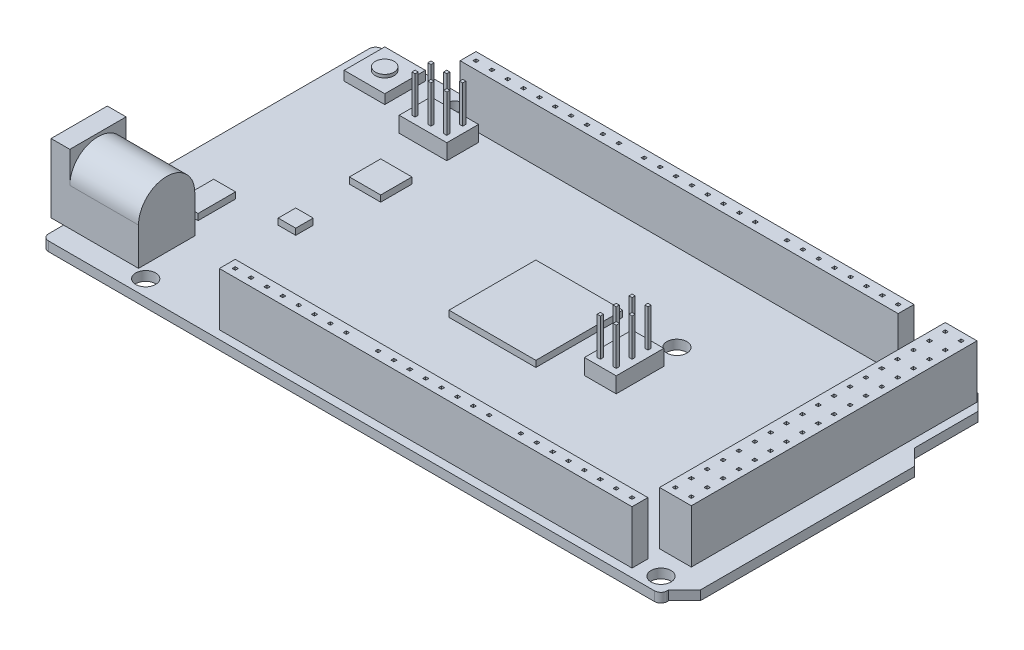
SolidWorks part; units mm, degrees
other "Camera1"
other "Camera3"
other "Camera4"
other "Camera5"
ref_plane "Front Plane" through (0, 0, 0) normal (0, 0, 1) x (1, 0, 0)
ref_plane "Top Plane" through (0, 0, 0) normal (0, 1, 0) x (1, 0, 0)
ref_plane "Right Plane" through (0, 0, 0) normal (1, 0, 0) x (0, 0, -1)
sketch "Sketch1" plane through (0, 0, 0) normal (0, 1, 0) x (1, 0, 0)
  line L0 (49.49, 24.11) -> (49.49, 13.95)
  line L1 (-49.49, 26.65) -> (46.95, 26.65)
  line L2 (-49.49, 26.65) -> (-49.49, -26.65)
  line L3 (-49.49, -26.65) -> (49.49, -26.65)
  line L4 (52.03, 26.65) -> (52.03, -26.65) construction
  line L5 (52.03, 11.41) -> (52.03, -22.85)
  line L6 (52.03, 11.41) -> (49.49, 13.95)
  line L7 (49.49, -26.65) -> (49.49, -25.39)
  line L8 (52.03, -22.85) -> (49.49, -25.39)
  line L9 (52.03, -5.72) -> (62.1258, -5.72) construction
  line L10 (46.95, 26.65) -> (49.49, 24.11)
  point P6 (-49.49, 0)
  point P7 (49.49, 26.65)
  point P10 (0, -26.65)
  dimension "D1" = 101.52
  dimension "D2" = 53.3
  dimension "D3" = 2.54
  dimension "D4" = 10.16
  dimension "D5" = 34.26
  dimension "D6" = 135
extrude "Boss-Extrude1" add sketch "Sketch1" along normal blind 1.5
fillet "Fillet1" radius 1 3 edges at (49.49, 0.75, 26.65) (-49.49, 0.75, -26.65) (-49.49, 0.75, 26.65)
sketch "Sketch2" plane through (0, 1.5, 0) normal (0, 1, 0) x (1, 0, 0)
  line L0 (-48.49, -26.65) -> (48.49, -26.65) construction
  line L1 (52.03, -22.85) -> (52.03, 11.41) construction
  line L2 (49.49, 13.95) -> (49.49, 24.11) construction
  line L3 (46.95, 26.65) -> (-48.49, 26.65) construction
  line L4 (-49.49, 25.65) -> (-49.49, -25.65) construction
  circle A0 centre (46.98, -24.11) radius 1.6
  circle A1 centre (40.62, 24.11) radius 1.6
  circle A2 centre (-34.26, 24.11) radius 1.6
  circle A3 centre (-35.49, -24.11) radius 1.6
  circle A4 centre (16.53, -19.03) radius 1.6
  circle A5 centre (16.53, 8.88) radius 1.6
  dimension "D1" = 3.2
  dimension "D2" = 2.54
  dimension "D3" = 5.05
  dimension "D4" = 8.87
  dimension "D5" = 2.54
  dimension "D6" = 7.62
  dimension "D7" = 35.5
  dimension "D8" = 27.91
  dimension "D9" = 15.23
  dimension "D10" = 14
extrude "Cut-Extrude1" cut sketch "Sketch2" against normal through all
sketch "Sketch3" plane through (0, 1.5, 0) normal (0, 1, 0) x (1, 0, 0)
  line L0 (-48.49, -26.65) -> (48.49, -26.65) construction
  line L1 (-22.51, -22.76) -> (-2.19, -22.76)
  line L2 (-22.51, -22.76) -> (-22.51, -25.3)
  line L3 (-22.51, -25.3) -> (-2.19, -25.3)
  line L4 (43.53, -22.76) -> (43.53, -25.3)
  line L5 (-18.95, -23.78) -> (-18.95, -24.28) construction
  line L6 (-21.49, -23.78) -> (-20.99, -23.78) construction
  line L7 (-21.49, -23.78) -> (-21.49, -24.28) construction
  line L8 (-21.49, -24.28) -> (-20.99, -24.28) construction
  line L9 (-20.99, -23.78) -> (-20.99, -24.28) construction
  line L10 (-18.95, -23.78) -> (-18.45, -23.78) construction
  line L11 (-18.45, -23.78) -> (-18.45, -24.28) construction
  line L12 (-18.95, -24.28) -> (-18.45, -24.28) construction
  line L13 (-16.41, -23.78) -> (-16.41, -24.28) construction
  line L14 (-16.41, -23.78) -> (-15.91, -23.78) construction
  line L15 (-15.91, -23.78) -> (-15.91, -24.28) construction
  line L16 (-16.41, -24.28) -> (-15.91, -24.28) construction
  line L17 (-13.87, -23.78) -> (-13.87, -24.28) construction
  line L18 (-13.87, -23.78) -> (-13.37, -23.78) construction
  line L19 (-13.37, -23.78) -> (-13.37, -24.28) construction
  line L20 (-13.87, -24.28) -> (-13.37, -24.28) construction
  line L21 (-11.33, -23.78) -> (-11.33, -24.28) construction
  line L22 (-11.33, -23.78) -> (-10.83, -23.78) construction
  line L23 (-10.83, -23.78) -> (-10.83, -24.28) construction
  line L24 (-11.33, -24.28) -> (-10.83, -24.28) construction
  line L25 (-8.79, -23.78) -> (-8.79, -24.28) construction
  line L26 (-8.79, -23.78) -> (-8.29, -23.78) construction
  line L27 (-8.29, -23.78) -> (-8.29, -24.28) construction
  line L28 (-8.79, -24.28) -> (-8.29, -24.28) construction
  line L29 (-6.25, -23.78) -> (-6.25, -24.28) construction
  line L30 (-6.25, -23.78) -> (-5.75, -23.78) construction
  line L31 (-5.75, -23.78) -> (-5.75, -24.28) construction
  line L32 (-6.25, -24.28) -> (-5.75, -24.28) construction
  line L33 (-3.71, -23.78) -> (-3.71, -24.28) construction
  line L34 (-3.71, -23.78) -> (-3.21, -23.78) construction
  line L35 (-3.21, -23.78) -> (-3.21, -24.28) construction
  line L36 (-3.71, -24.28) -> (-3.21, -24.28) construction
  line L37 (-1.17, -23.78) -> (-1.17, -24.28) construction
  line L38 (-1.17, -23.78) -> (-0.67, -23.78) construction
  line L39 (-0.67, -23.78) -> (-0.67, -24.28) construction
  line L40 (-1.17, -24.28) -> (-0.67, -24.28) construction
  line L41 (1.37, -23.78) -> (1.37, -24.28) construction
  line L42 (1.37, -23.78) -> (1.87, -23.78) construction
  line L43 (1.87, -23.78) -> (1.87, -24.28) construction
  line L44 (1.37, -24.28) -> (1.87, -24.28) construction
  line L45 (3.91, -23.78) -> (3.91, -24.28) construction
  line L46 (3.91, -23.78) -> (4.41, -23.78) construction
  line L47 (4.41, -23.78) -> (4.41, -24.28) construction
  line L48 (3.91, -24.28) -> (4.41, -24.28) construction
  line L49 (6.45, -23.78) -> (6.45, -24.28) construction
  line L50 (6.45, -23.78) -> (6.95, -23.78) construction
  line L51 (6.95, -23.78) -> (6.95, -24.28) construction
  line L52 (6.45, -24.28) -> (6.95, -24.28) construction
  line L53 (8.99, -23.78) -> (8.99, -24.28) construction
  line L54 (8.99, -23.78) -> (9.49, -23.78) construction
  line L55 (9.49, -23.78) -> (9.49, -24.28) construction
  line L56 (8.99, -24.28) -> (9.49, -24.28) construction
  line L57 (11.53, -23.78) -> (11.53, -24.28) construction
  line L58 (11.53, -23.78) -> (12.03, -23.78) construction
  line L59 (12.03, -23.78) -> (12.03, -24.28) construction
  line L60 (11.53, -24.28) -> (12.03, -24.28) construction
  line L61 (14.07, -23.78) -> (14.07, -24.28) construction
  line L62 (14.07, -23.78) -> (14.57, -23.78) construction
  line L63 (14.57, -23.78) -> (14.57, -24.28) construction
  line L64 (14.07, -24.28) -> (14.57, -24.28) construction
  line L65 (16.61, -23.78) -> (16.61, -24.28) construction
  line L66 (16.61, -23.78) -> (17.11, -23.78) construction
  line L67 (17.11, -23.78) -> (17.11, -24.28) construction
  line L68 (16.61, -24.28) -> (17.11, -24.28) construction
  line L69 (19.15, -23.78) -> (19.15, -24.28) construction
  line L70 (19.15, -23.78) -> (19.65, -23.78) construction
  line L71 (19.65, -23.78) -> (19.65, -24.28) construction
  line L72 (19.15, -24.28) -> (19.65, -24.28) construction
  line L73 (21.69, -23.78) -> (21.69, -24.28) construction
  line L74 (21.69, -23.78) -> (22.19, -23.78) construction
  line L75 (22.19, -23.78) -> (22.19, -24.28) construction
  line L76 (21.69, -24.28) -> (22.19, -24.28) construction
  line L77 (24.23, -23.78) -> (24.23, -24.28) construction
  line L78 (24.23, -23.78) -> (24.73, -23.78) construction
  line L79 (24.73, -23.78) -> (24.73, -24.28) construction
  line L80 (24.23, -24.28) -> (24.73, -24.28) construction
  line L81 (26.77, -23.78) -> (26.77, -24.28) construction
  line L82 (26.77, -23.78) -> (27.27, -23.78) construction
  line L83 (27.27, -23.78) -> (27.27, -24.28) construction
  line L84 (26.77, -24.28) -> (27.27, -24.28) construction
  line L85 (29.31, -23.78) -> (29.31, -24.28) construction
  line L86 (29.31, -23.78) -> (29.81, -23.78) construction
  line L87 (29.81, -23.78) -> (29.81, -24.28) construction
  line L88 (29.31, -24.28) -> (29.81, -24.28) construction
  line L89 (31.85, -23.78) -> (31.85, -24.28) construction
  line L90 (31.85, -23.78) -> (32.35, -23.78) construction
  line L91 (32.35, -23.78) -> (32.35, -24.28) construction
  line L92 (31.85, -24.28) -> (32.35, -24.28) construction
  line L93 (34.39, -23.78) -> (34.39, -24.28) construction
  line L94 (34.39, -23.78) -> (34.89, -23.78) construction
  line L95 (34.89, -23.78) -> (34.89, -24.28) construction
  line L96 (34.39, -24.28) -> (34.89, -24.28) construction
  line L97 (36.93, -23.78) -> (36.93, -24.28) construction
  line L98 (36.93, -23.78) -> (37.43, -23.78) construction
  line L99 (37.43, -23.78) -> (37.43, -24.28) construction
  line L100 (36.93, -24.28) -> (37.43, -24.28) construction
  line L101 (39.47, -23.78) -> (39.47, -24.28) construction
  line L102 (39.47, -23.78) -> (39.97, -23.78) construction
  line L103 (39.97, -23.78) -> (39.97, -24.28) construction
  line L104 (39.47, -24.28) -> (39.97, -24.28) construction
  line L105 (42.01, -23.78) -> (42.01, -24.28) construction
  line L106 (42.01, -23.78) -> (42.51, -23.78) construction
  line L107 (42.51, -23.78) -> (42.51, -24.28) construction
  line L108 (42.01, -24.28) -> (42.51, -24.28) construction
  line L109 (-21.49, -23.78) -> (-22.51, -23.78) construction
  line L110 (42.51, -23.78) -> (43.53, -23.78) construction
  line L111 (52.03, -22.85) -> (52.03, 11.41) construction
  line L112 (-21.49, -23.78) -> (-21.49, -22.76) construction
  line L113 (-2.19, -22.76) -> (-2.19, -25.3) construction
  line L114 (-3.21, -23.78) -> (-1.17, -23.78) construction
  line L115 (-0.92, -23.78) -> (-0.92, -24.28) construction
  line L116 (0.35, -22.76) -> (0.35, -25.3) construction
  line L117 (20.67, -22.76) -> (20.67, -25.3) construction
  line L118 (19.65, -24.28) -> (21.69, -24.28) construction
  line L119 (21.94, -23.78) -> (21.94, -24.28) construction
  line L120 (23.21, -22.76) -> (23.21, -25.3) construction
  line L121 (0.35, -22.76) -> (20.67, -22.76)
  line L122 (0.35, -25.3) -> (20.67, -25.3)
  line L123 (23.21, -25.3) -> (43.53, -25.3)
  line L124 (23.21, -22.76) -> (43.53, -22.76)
  line L125 (45.6, -20.42) -> (45.6, 25.3) construction
  line L126 (43.06, -20.42) -> (48.14, -20.42)
  line L127 (43.06, -20.42) -> (43.06, 25.3)
  line L128 (43.06, 25.3) -> (48.14, 25.3)
  line L129 (48.14, -20.42) -> (48.14, 25.3)
  line L130 (46.95, 26.65) -> (-48.49, 26.65) construction
  line L131 (49.49, 13.95) -> (49.49, 24.11) construction
  line L132 (43.06, 24.8735) -> (45.6, 24.8735) construction
  line L133 (44.08, 24.28) -> (44.58, 24.28) construction
  line L134 (44.08, 24.28) -> (44.08, 23.78) construction
  line L135 (44.08, 23.78) -> (44.58, 23.78) construction
  line L136 (44.58, 24.28) -> (44.58, 23.78) construction
  line L137 (44.08, 24.28) -> (44.08, 25.3) construction
  line L138 (46.62, 24.28) -> (46.62, 23.78) construction
  line L139 (47.12, 23.78) -> (46.62, 23.78) construction
  line L140 (47.12, 24.28) -> (47.12, 23.78) construction
  line L141 (47.12, 24.28) -> (46.62, 24.28) construction
  line L142 (44.58, 21.74) -> (44.58, 21.24) construction
  line L143 (44.08, 21.74) -> (44.58, 21.74) construction
  line L144 (44.08, 21.74) -> (44.08, 21.24) construction
  line L145 (44.08, 21.24) -> (44.58, 21.24) construction
  line L146 (46.62, 21.74) -> (46.62, 21.24) construction
  line L147 (47.12, 21.74) -> (46.62, 21.74) construction
  line L148 (47.12, 21.74) -> (47.12, 21.24) construction
  line L149 (47.12, 21.24) -> (46.62, 21.24) construction
  line L150 (44.58, 19.2) -> (44.58, 18.7) construction
  line L151 (44.08, 19.2) -> (44.58, 19.2) construction
  line L152 (44.08, 19.2) -> (44.08, 18.7) construction
  line L153 (44.08, 18.7) -> (44.58, 18.7) construction
  line L154 (46.62, 19.2) -> (46.62, 18.7) construction
  line L155 (47.12, 19.2) -> (46.62, 19.2) construction
  line L156 (47.12, 19.2) -> (47.12, 18.7) construction
  line L157 (47.12, 18.7) -> (46.62, 18.7) construction
  line L158 (44.58, 16.66) -> (44.58, 16.16) construction
  line L159 (44.08, 16.66) -> (44.58, 16.66) construction
  line L160 (44.08, 16.66) -> (44.08, 16.16) construction
  line L161 (44.08, 16.16) -> (44.58, 16.16) construction
  line L162 (46.62, 16.66) -> (46.62, 16.16) construction
  line L163 (47.12, 16.66) -> (46.62, 16.66) construction
  line L164 (47.12, 16.66) -> (47.12, 16.16) construction
  line L165 (47.12, 16.16) -> (46.62, 16.16) construction
  line L166 (44.58, 14.12) -> (44.58, 13.62) construction
  line L167 (44.08, 14.12) -> (44.58, 14.12) construction
  line L168 (44.08, 14.12) -> (44.08, 13.62) construction
  line L169 (44.08, 13.62) -> (44.58, 13.62) construction
  line L170 (46.62, 14.12) -> (46.62, 13.62) construction
  line L171 (47.12, 14.12) -> (46.62, 14.12) construction
  line L172 (47.12, 14.12) -> (47.12, 13.62) construction
  line L173 (47.12, 13.62) -> (46.62, 13.62) construction
  line L174 (44.58, 11.58) -> (44.58, 11.08) construction
  line L175 (44.08, 11.58) -> (44.58, 11.58) construction
  line L176 (44.08, 11.58) -> (44.08, 11.08) construction
  line L177 (44.08, 11.08) -> (44.58, 11.08) construction
  line L178 (46.62, 11.58) -> (46.62, 11.08) construction
  line L179 (47.12, 11.58) -> (46.62, 11.58) construction
  line L180 (47.12, 11.58) -> (47.12, 11.08) construction
  line L181 (47.12, 11.08) -> (46.62, 11.08) construction
  line L182 (44.58, 9.04) -> (44.58, 8.54) construction
  line L183 (44.08, 9.04) -> (44.58, 9.04) construction
  line L184 (44.08, 9.04) -> (44.08, 8.54) construction
  line L185 (44.08, 8.54) -> (44.58, 8.54) construction
  line L186 (46.62, 9.04) -> (46.62, 8.54) construction
  line L187 (47.12, 9.04) -> (46.62, 9.04) construction
  line L188 (47.12, 9.04) -> (47.12, 8.54) construction
  line L189 (47.12, 8.54) -> (46.62, 8.54) construction
  line L190 (44.58, 6.5) -> (44.58, 6) construction
  line L191 (44.08, 6.5) -> (44.58, 6.5) construction
  line L192 (44.08, 6.5) -> (44.08, 6) construction
  line L193 (44.08, 6) -> (44.58, 6) construction
  line L194 (46.62, 6.5) -> (46.62, 6) construction
  line L195 (47.12, 6.5) -> (46.62, 6.5) construction
  line L196 (47.12, 6.5) -> (47.12, 6) construction
  line L197 (47.12, 6) -> (46.62, 6) construction
  line L198 (44.58, 3.96) -> (44.58, 3.46) construction
  line L199 (44.08, 3.96) -> (44.58, 3.96) construction
  line L200 (44.08, 3.96) -> (44.08, 3.46) construction
  line L201 (44.08, 3.46) -> (44.58, 3.46) construction
  line L202 (46.62, 3.96) -> (46.62, 3.46) construction
  line L203 (47.12, 3.96) -> (46.62, 3.96) construction
  line L204 (47.12, 3.96) -> (47.12, 3.46) construction
  line L205 (47.12, 3.46) -> (46.62, 3.46) construction
  line L206 (44.58, 1.42) -> (44.58, 0.92) construction
  line L207 (44.08, 1.42) -> (44.58, 1.42) construction
  line L208 (44.08, 1.42) -> (44.08, 0.92) construction
  line L209 (44.08, 0.92) -> (44.58, 0.92) construction
  line L210 (46.62, 1.42) -> (46.62, 0.92) construction
  line L211 (47.12, 1.42) -> (46.62, 1.42) construction
  line L212 (47.12, 1.42) -> (47.12, 0.92) construction
  line L213 (47.12, 0.92) -> (46.62, 0.92) construction
  line L214 (44.58, -1.12) -> (44.58, -1.62) construction
  line L215 (44.08, -1.12) -> (44.58, -1.12) construction
  line L216 (44.08, -1.12) -> (44.08, -1.62) construction
  line L217 (44.08, -1.62) -> (44.58, -1.62) construction
  line L218 (46.62, -1.12) -> (46.62, -1.62) construction
  line L219 (47.12, -1.12) -> (46.62, -1.12) construction
  line L220 (47.12, -1.12) -> (47.12, -1.62) construction
  line L221 (47.12, -1.62) -> (46.62, -1.62) construction
  line L222 (44.58, -3.66) -> (44.58, -4.16) construction
  line L223 (44.08, -3.66) -> (44.58, -3.66) construction
  line L224 (44.08, -3.66) -> (44.08, -4.16) construction
  line L225 (44.08, -4.16) -> (44.58, -4.16) construction
  line L226 (46.62, -3.66) -> (46.62, -4.16) construction
  line L227 (47.12, -3.66) -> (46.62, -3.66) construction
  line L228 (47.12, -3.66) -> (47.12, -4.16) construction
  line L229 (47.12, -4.16) -> (46.62, -4.16) construction
  line L230 (44.58, -6.2) -> (44.58, -6.7) construction
  line L231 (44.08, -6.2) -> (44.58, -6.2) construction
  line L232 (44.08, -6.2) -> (44.08, -6.7) construction
  line L233 (44.08, -6.7) -> (44.58, -6.7) construction
  line L234 (46.62, -6.2) -> (46.62, -6.7) construction
  line L235 (47.12, -6.2) -> (46.62, -6.2) construction
  line L236 (47.12, -6.2) -> (47.12, -6.7) construction
  line L237 (47.12, -6.7) -> (46.62, -6.7) construction
  line L238 (44.58, -8.74) -> (44.58, -9.24) construction
  line L239 (44.08, -8.74) -> (44.58, -8.74) construction
  line L240 (44.08, -8.74) -> (44.08, -9.24) construction
  line L241 (44.08, -9.24) -> (44.58, -9.24) construction
  line L242 (46.62, -8.74) -> (46.62, -9.24) construction
  line L243 (47.12, -8.74) -> (46.62, -8.74) construction
  line L244 (47.12, -8.74) -> (47.12, -9.24) construction
  line L245 (47.12, -9.24) -> (46.62, -9.24) construction
  line L246 (44.58, -11.28) -> (44.58, -11.78) construction
  line L247 (44.08, -11.28) -> (44.58, -11.28) construction
  line L248 (44.08, -11.28) -> (44.08, -11.78) construction
  line L249 (44.08, -11.78) -> (44.58, -11.78) construction
  line L250 (46.62, -11.28) -> (46.62, -11.78) construction
  line L251 (47.12, -11.28) -> (46.62, -11.28) construction
  line L252 (47.12, -11.28) -> (47.12, -11.78) construction
  line L253 (47.12, -11.78) -> (46.62, -11.78) construction
  line L254 (44.58, -13.82) -> (44.58, -14.32) construction
  line L255 (44.08, -13.82) -> (44.58, -13.82) construction
  line L256 (44.08, -13.82) -> (44.08, -14.32) construction
  line L257 (44.08, -14.32) -> (44.58, -14.32) construction
  line L258 (46.62, -13.82) -> (46.62, -14.32) construction
  line L259 (47.12, -13.82) -> (46.62, -13.82) construction
  line L260 (47.12, -13.82) -> (47.12, -14.32) construction
  line L261 (47.12, -14.32) -> (46.62, -14.32) construction
  line L262 (44.58, -16.36) -> (44.58, -16.86) construction
  line L263 (44.08, -16.36) -> (44.58, -16.36) construction
  line L264 (44.08, -16.36) -> (44.08, -16.86) construction
  line L265 (44.08, -16.86) -> (44.58, -16.86) construction
  line L266 (46.62, -16.36) -> (46.62, -16.86) construction
  line L267 (47.12, -16.36) -> (46.62, -16.36) construction
  line L268 (47.12, -16.36) -> (47.12, -16.86) construction
  line L269 (47.12, -16.86) -> (46.62, -16.86) construction
  line L270 (44.58, -18.9) -> (44.58, -19.4) construction
  line L271 (44.08, -18.9) -> (44.58, -18.9) construction
  line L272 (44.08, -18.9) -> (44.08, -19.4) construction
  line L273 (44.08, -19.4) -> (44.58, -19.4) construction
  line L274 (46.62, -18.9) -> (46.62, -19.4) construction
  line L275 (47.12, -18.9) -> (46.62, -18.9) construction
  line L276 (47.12, -18.9) -> (47.12, -19.4) construction
  line L277 (47.12, -19.4) -> (46.62, -19.4) construction
  line L278 (44.08, -19.4) -> (44.08, -20.42) construction
  line L279 (-2.19, -22.76) -> (0.35, -22.76)
  line L280 (38.06, 25.3) -> (17.74, 25.3)
  line L281 (38.06, 25.3) -> (38.06, 22.76)
  line L282 (38.06, 22.76) -> (17.74, 22.76)
  line L283 (-32.04, 25.3) -> (-32.04, 22.76)
  line L284 (-31.02, 24.28) -> (-32.04, 24.28) construction
  line L285 (-31.02, 24.28) -> (-30.52, 24.28) construction
  line L286 (-31.02, 24.28) -> (-31.02, 23.78) construction
  line L287 (-31.02, 23.78) -> (-30.52, 23.78) construction
  line L288 (-30.52, 24.28) -> (-30.52, 23.78) construction
  line L289 (-31.02, 24.28) -> (-31.02, 25.3) construction
  line L290 (-28.48, 24.28) -> (-28.48, 23.78) construction
  line L291 (-28.48, 24.28) -> (-27.98, 24.28) construction
  line L292 (-27.98, 24.28) -> (-27.98, 23.78) construction
  line L293 (-28.48, 23.78) -> (-27.98, 23.78) construction
  line L294 (-25.94, 24.28) -> (-25.94, 23.78) construction
  line L295 (-25.94, 24.28) -> (-25.44, 24.28) construction
  line L296 (-25.44, 24.28) -> (-25.44, 23.78) construction
  line L297 (-25.94, 23.78) -> (-25.44, 23.78) construction
  line L298 (-23.4, 24.28) -> (-23.4, 23.78) construction
  line L299 (-23.4, 24.28) -> (-22.9, 24.28) construction
  line L300 (-22.9, 24.28) -> (-22.9, 23.78) construction
  line L301 (-23.4, 23.78) -> (-22.9, 23.78) construction
  line L302 (-20.86, 24.28) -> (-20.86, 23.78) construction
  line L303 (-20.86, 24.28) -> (-20.36, 24.28) construction
  line L304 (-20.36, 24.28) -> (-20.36, 23.78) construction
  line L305 (-20.86, 23.78) -> (-20.36, 23.78) construction
  line L306 (-18.32, 24.28) -> (-18.32, 23.78) construction
  line L307 (-18.32, 24.28) -> (-17.82, 24.28) construction
  line L308 (-17.82, 24.28) -> (-17.82, 23.78) construction
  line L309 (-18.32, 23.78) -> (-17.82, 23.78) construction
  line L310 (-15.78, 24.28) -> (-15.78, 23.78) construction
  line L311 (-15.78, 24.28) -> (-15.28, 24.28) construction
  line L312 (-15.28, 24.28) -> (-15.28, 23.78) construction
  line L313 (-15.78, 23.78) -> (-15.28, 23.78) construction
  line L314 (-13.24, 24.28) -> (-13.24, 23.78) construction
  line L315 (-13.24, 24.28) -> (-12.74, 24.28) construction
  line L316 (-12.74, 24.28) -> (-12.74, 23.78) construction
  line L317 (-13.24, 23.78) -> (-12.74, 23.78) construction
  line L318 (-10.7, 24.28) -> (-10.7, 23.78) construction
  line L319 (-10.7, 24.28) -> (-10.2, 24.28) construction
  line L320 (-10.2, 24.28) -> (-10.2, 23.78) construction
  line L321 (-10.7, 23.78) -> (-10.2, 23.78) construction
  line L322 (-8.16, 24.28) -> (-8.16, 23.78) construction
  line L323 (-8.16, 24.28) -> (-7.66, 24.28) construction
  line L324 (-7.66, 24.28) -> (-7.66, 23.78) construction
  line L325 (-8.16, 23.78) -> (-7.66, 23.78) construction
  line L326 (-7.66, 24.28) -> (-4.1, 24.28) construction
  line L327 (-1.56, 24.28) -> (-1.06, 24.28) construction
  line L328 (-4.1, 24.28) -> (-3.6, 24.28) construction
  line L329 (-4.1, 24.28) -> (-4.1, 23.78) construction
  line L330 (-4.1, 23.78) -> (-3.6, 23.78) construction
  line L331 (-3.6, 24.28) -> (-3.6, 23.78) construction
  line L332 (-1.56, 24.28) -> (-1.56, 23.78) construction
  line L333 (-1.56, 23.78) -> (-1.06, 23.78) construction
  line L334 (-1.06, 24.28) -> (-1.06, 23.78) construction
  line L335 (0.98, 24.28) -> (1.48, 24.28) construction
  line L336 (0.98, 24.28) -> (0.98, 23.78) construction
  line L337 (0.98, 23.78) -> (1.48, 23.78) construction
  line L338 (1.48, 24.28) -> (1.48, 23.78) construction
  line L339 (3.52, 24.28) -> (4.02, 24.28) construction
  line L340 (3.52, 24.28) -> (3.52, 23.78) construction
  line L341 (3.52, 23.78) -> (4.02, 23.78) construction
  line L342 (4.02, 24.28) -> (4.02, 23.78) construction
  line L343 (6.06, 24.28) -> (6.56, 24.28) construction
  line L344 (6.06, 24.28) -> (6.06, 23.78) construction
  line L345 (6.06, 23.78) -> (6.56, 23.78) construction
  line L346 (6.56, 24.28) -> (6.56, 23.78) construction
  line L347 (8.6, 24.28) -> (9.1, 24.28) construction
  line L348 (8.6, 24.28) -> (8.6, 23.78) construction
  line L349 (8.6, 23.78) -> (9.1, 23.78) construction
  line L350 (9.1, 24.28) -> (9.1, 23.78) construction
  line L351 (11.14, 24.28) -> (11.64, 24.28) construction
  line L352 (11.14, 24.28) -> (11.14, 23.78) construction
  line L353 (11.14, 23.78) -> (11.64, 23.78) construction
  line L354 (11.64, 24.28) -> (11.64, 23.78) construction
  line L355 (13.68, 24.28) -> (14.18, 24.28) construction
  line L356 (13.68, 24.28) -> (13.68, 23.78) construction
  line L357 (13.68, 23.78) -> (14.18, 23.78) construction
  line L358 (14.18, 24.28) -> (14.18, 23.78) construction
  line L359 (16.22, 24.28) -> (16.72, 24.28) construction
  line L360 (16.22, 24.28) -> (16.22, 23.78) construction
  line L361 (16.22, 23.78) -> (16.72, 23.78) construction
  line L362 (16.72, 24.28) -> (16.72, 23.78) construction
  line L363 (18.76, 24.28) -> (19.26, 24.28) construction
  line L364 (18.76, 24.28) -> (18.76, 23.78) construction
  line L365 (18.76, 23.78) -> (19.26, 23.78) construction
  line L366 (19.26, 24.28) -> (19.26, 23.78) construction
  line L367 (21.3, 24.28) -> (21.8, 24.28) construction
  line L368 (21.3, 24.28) -> (21.3, 23.78) construction
  line L369 (21.3, 23.78) -> (21.8, 23.78) construction
  line L370 (21.8, 24.28) -> (21.8, 23.78) construction
  line L371 (23.84, 24.28) -> (24.34, 24.28) construction
  line L372 (23.84, 24.28) -> (23.84, 23.78) construction
  line L373 (23.84, 23.78) -> (24.34, 23.78) construction
  line L374 (24.34, 24.28) -> (24.34, 23.78) construction
  line L375 (26.38, 24.28) -> (26.88, 24.28) construction
  line L376 (26.38, 24.28) -> (26.38, 23.78) construction
  line L377 (26.38, 23.78) -> (26.88, 23.78) construction
  line L378 (26.88, 24.28) -> (26.88, 23.78) construction
  line L379 (28.92, 24.28) -> (29.42, 24.28) construction
  line L380 (28.92, 24.28) -> (28.92, 23.78) construction
  line L381 (28.92, 23.78) -> (29.42, 23.78) construction
  line L382 (29.42, 24.28) -> (29.42, 23.78) construction
  line L383 (31.46, 24.28) -> (31.96, 24.28) construction
  line L384 (31.46, 24.28) -> (31.46, 23.78) construction
  line L385 (31.46, 23.78) -> (31.96, 23.78) construction
  line L386 (31.96, 24.28) -> (31.96, 23.78) construction
  line L387 (34, 24.28) -> (34.5, 24.28) construction
  line L388 (34, 24.28) -> (34, 23.78) construction
  line L389 (34, 23.78) -> (34.5, 23.78) construction
  line L390 (34.5, 24.28) -> (34.5, 23.78) construction
  line L391 (36.54, 24.28) -> (37.04, 24.28) construction
  line L392 (36.54, 24.28) -> (36.54, 23.78) construction
  line L393 (36.54, 23.78) -> (37.04, 23.78) construction
  line L394 (37.04, 24.28) -> (37.04, 23.78) construction
  line L395 (15.2, 25.3) -> (15.2, 22.76) construction
  line L396 (14.18, 24.28) -> (16.22, 24.28) construction
  line L397 (16.47, 24.28) -> (16.47, 23.78) construction
  line L398 (17.74, 25.3) -> (17.74, 22.76) construction
  line L399 (15.2, 25.3) -> (-5.12, 25.3)
  line L400 (15.2, 22.76) -> (-5.12, 22.76)
  line L401 (-7.66, 23.78) -> (-6.64, 23.78) construction
  line L402 (-6.64, 22.76) -> (-6.64, 25.3) construction
  line L403 (-4.1, 23.78) -> (-5.12, 23.78) construction
  line L404 (-5.12, 25.3) -> (-5.12, 22.76) construction
  line L405 (-6.64, 25.3) -> (-32.04, 25.3)
  line L406 (-6.64, 22.76) -> (-32.04, 22.76)
  line L407 (18.76, 24.28) -> (17.74, 24.28) construction
  line L408 (37.04, 24.28) -> (38.06, 24.28) construction
  line L409 (-2.19, -25.3) -> (0.35, -25.3)
  line L410 (20.67, -22.76) -> (23.21, -22.76)
  line L411 (20.67, -25.3) -> (23.21, -25.3)
  line L412 (15.2, 25.3) -> (17.74, 25.3)
  line L413 (15.2, 22.76) -> (17.74, 22.76)
  line L414 (-6.64, 25.3) -> (-5.12, 25.3)
  line L415 (-6.64, 22.76) -> (-5.12, 22.76)
  line L416 (-8.16, 24.03) -> (-7.66, 24.03) construction
  line L417 (-7.91, 24.28) -> (-7.91, 23.78) construction
  line L418 (-3.85, 24.28) -> (-3.85, 23.78) construction
  line L419 (-4.1, 24.03) -> (-3.6, 24.03) construction
  point P10 (-21.49, -24.03)
  point P11 (-22.51, -24.03)
  point P119 (-2.19, -23.78)
  point P126 (20.67, -24.28)
  point P147 (44.33, 24.28)
  point P148 (44.33, 24.8735)
  point P301 (-31.02, 24.03)
  point P302 (-32.04, 24.03)
  point P411 (15.2, 24.28)
  point P430 (-7.91, 24.03)
  point P431 (-3.85, 24.03)
  dimension "D1" = 1.35
  dimension "D2" = 0.5
  dimension "D4" = 2.54
  dimension "D5" = 8.5
  dimension "D6" = 2.54
  dimension "D7" = 5.08
  dimension "D8" = 1.35
  dimension "D9" = 1.35
  dimension "D10" = 0.5
  dimension "D11" = 1.02
  dimension "D13" = 2.54
  dimension "D14" = 1.35
  dimension "D15" = 2.54
  dimension "D16" = 5
  dimension "D17" = 0.5
  dimension "D19" = 2.54
  dimension "D20" = 4.06
  dimension "D22" = 2.54
  dimension "D3" = 26
  dimension "D12" = 18
  dimension "D18" = 10
  dimension "D21" = 17
extrude "Boss-Extrude2" add sketch "Sketch3" along normal blind 8.5
sketch "Sketch4" plane through (0, 10, 0) normal (0, 1, 0) x (1, 0, 0)
  line L0 (-21.49, -24.28) -> (-20.99, -24.28) construction
  line L1 (-20.99, -23.78) -> (-20.99, -24.28) construction
  line L2 (-21.49, -23.78) -> (-20.99, -23.78) construction
  line L3 (-21.49, -23.78) -> (-21.49, -24.28) construction
  line L4 (-21.49, -24.28) -> (-20.99, -24.28)
  line L5 (-20.99, -23.78) -> (-20.99, -24.28)
  line L6 (-21.49, -23.78) -> (-20.99, -23.78)
  line L7 (-21.49, -23.78) -> (-21.49, -24.28)
  line L8 (-18.95, -24.28) -> (-18.45, -24.28)
  line L9 (-18.45, -23.78) -> (-18.45, -24.28)
  line L10 (-18.95, -23.78) -> (-18.45, -23.78)
  line L11 (-18.95, -23.78) -> (-18.95, -24.28)
  line L12 (-16.41, -24.28) -> (-15.91, -24.28)
  line L13 (-15.91, -23.78) -> (-15.91, -24.28)
  line L14 (-16.41, -23.78) -> (-15.91, -23.78)
  line L15 (-16.41, -23.78) -> (-16.41, -24.28)
  line L16 (-13.87, -24.28) -> (-13.37, -24.28)
  line L17 (-13.37, -23.78) -> (-13.37, -24.28)
  line L18 (-13.87, -23.78) -> (-13.37, -23.78)
  line L19 (-13.87, -23.78) -> (-13.87, -24.28)
  line L20 (-11.33, -24.28) -> (-10.83, -24.28)
  line L21 (-10.83, -23.78) -> (-10.83, -24.28)
  line L22 (-11.33, -23.78) -> (-10.83, -23.78)
  line L23 (-11.33, -23.78) -> (-11.33, -24.28)
  line L24 (-8.79, -24.28) -> (-8.29, -24.28)
  line L25 (-8.29, -23.78) -> (-8.29, -24.28)
  line L26 (-8.79, -23.78) -> (-8.29, -23.78)
  line L27 (-8.79, -23.78) -> (-8.79, -24.28)
  line L28 (-6.25, -24.28) -> (-5.75, -24.28)
  line L29 (-5.75, -23.78) -> (-5.75, -24.28)
  line L30 (-6.25, -23.78) -> (-5.75, -23.78)
  line L31 (-6.25, -23.78) -> (-6.25, -24.28)
  line L32 (-3.71, -24.28) -> (-3.21, -24.28)
  line L33 (-3.21, -23.78) -> (-3.21, -24.28)
  line L34 (-3.71, -23.78) -> (-3.21, -23.78)
  line L35 (-3.71, -23.78) -> (-3.71, -24.28)
  line L36 (-1.17, -24.28) -> (-0.67, -24.28) construction
  line L37 (-0.67, -23.78) -> (-0.67, -24.28) construction
  line L38 (-1.17, -23.78) -> (-0.67, -23.78) construction
  line L39 (-1.17, -23.78) -> (-1.17, -24.28) construction
  line L40 (1.37, -24.28) -> (1.87, -24.28)
  line L41 (1.87, -23.78) -> (1.87, -24.28)
  line L42 (1.37, -23.78) -> (1.87, -23.78)
  line L43 (1.37, -23.78) -> (1.37, -24.28)
  line L44 (3.91, -24.28) -> (4.41, -24.28)
  line L45 (4.41, -23.78) -> (4.41, -24.28)
  line L46 (3.91, -23.78) -> (4.41, -23.78)
  line L47 (3.91, -23.78) -> (3.91, -24.28)
  line L48 (6.45, -24.28) -> (6.95, -24.28)
  line L49 (6.95, -23.78) -> (6.95, -24.28)
  line L50 (6.45, -23.78) -> (6.95, -23.78)
  line L51 (6.45, -23.78) -> (6.45, -24.28)
  line L52 (8.99, -24.28) -> (9.49, -24.28)
  line L53 (9.49, -23.78) -> (9.49, -24.28)
  line L54 (8.99, -23.78) -> (9.49, -23.78)
  line L55 (8.99, -23.78) -> (8.99, -24.28)
  line L56 (11.53, -24.28) -> (12.03, -24.28)
  line L57 (12.03, -23.78) -> (12.03, -24.28)
  line L58 (11.53, -23.78) -> (12.03, -23.78)
  line L59 (11.53, -23.78) -> (11.53, -24.28)
  line L60 (14.07, -24.28) -> (14.57, -24.28)
  line L61 (14.57, -23.78) -> (14.57, -24.28)
  line L62 (14.07, -23.78) -> (14.57, -23.78)
  line L63 (14.07, -23.78) -> (14.07, -24.28)
  line L64 (16.61, -24.28) -> (17.11, -24.28)
  line L65 (17.11, -23.78) -> (17.11, -24.28)
  line L66 (16.61, -23.78) -> (17.11, -23.78)
  line L67 (16.61, -23.78) -> (16.61, -24.28)
  line L68 (19.15, -24.28) -> (19.65, -24.28)
  line L69 (19.65, -23.78) -> (19.65, -24.28)
  line L70 (19.15, -23.78) -> (19.65, -23.78)
  line L71 (19.15, -23.78) -> (19.15, -24.28)
  line L72 (21.69, -24.28) -> (22.19, -24.28) construction
  line L73 (22.19, -23.78) -> (22.19, -24.28) construction
  line L74 (21.69, -23.78) -> (22.19, -23.78) construction
  line L75 (21.69, -23.78) -> (21.69, -24.28) construction
  line L76 (24.23, -24.28) -> (24.73, -24.28)
  line L77 (24.73, -23.78) -> (24.73, -24.28)
  line L78 (24.23, -23.78) -> (24.73, -23.78)
  line L79 (24.23, -23.78) -> (24.23, -24.28)
  line L80 (26.77, -24.28) -> (27.27, -24.28)
  line L81 (27.27, -23.78) -> (27.27, -24.28)
  line L82 (26.77, -23.78) -> (27.27, -23.78)
  line L83 (26.77, -23.78) -> (26.77, -24.28)
  line L84 (29.31, -24.28) -> (29.81, -24.28)
  line L85 (29.81, -23.78) -> (29.81, -24.28)
  line L86 (29.31, -23.78) -> (29.81, -23.78)
  line L87 (29.31, -23.78) -> (29.31, -24.28)
  line L88 (31.85, -24.28) -> (32.35, -24.28)
  line L89 (32.35, -23.78) -> (32.35, -24.28)
  line L90 (31.85, -23.78) -> (32.35, -23.78)
  line L91 (31.85, -23.78) -> (31.85, -24.28)
  line L92 (34.39, -24.28) -> (34.89, -24.28)
  line L93 (34.89, -23.78) -> (34.89, -24.28)
  line L94 (34.39, -23.78) -> (34.89, -23.78)
  line L95 (34.39, -23.78) -> (34.39, -24.28)
  line L96 (36.93, -24.28) -> (37.43, -24.28)
  line L97 (37.43, -23.78) -> (37.43, -24.28)
  line L98 (36.93, -23.78) -> (37.43, -23.78)
  line L99 (36.93, -23.78) -> (36.93, -24.28)
  line L100 (39.47, -24.28) -> (39.97, -24.28)
  line L101 (39.97, -23.78) -> (39.97, -24.28)
  line L102 (39.47, -23.78) -> (39.97, -23.78)
  line L103 (39.47, -23.78) -> (39.47, -24.28)
  line L104 (42.01, -24.28) -> (42.51, -24.28)
  line L105 (42.51, -23.78) -> (42.51, -24.28)
  line L106 (42.01, -23.78) -> (42.51, -23.78)
  line L107 (42.01, -23.78) -> (42.01, -24.28)
  line L108 (44.08, -19.4) -> (44.58, -19.4) construction
  line L109 (44.58, -18.9) -> (44.58, -19.4) construction
  line L110 (44.08, -18.9) -> (44.58, -18.9) construction
  line L111 (44.08, -18.9) -> (44.08, -19.4) construction
  line L112 (47.12, -19.4) -> (46.62, -19.4) construction
  line L113 (47.12, -18.9) -> (47.12, -19.4) construction
  line L114 (47.12, -18.9) -> (46.62, -18.9) construction
  line L115 (46.62, -18.9) -> (46.62, -19.4) construction
  line L116 (47.12, -19.4) -> (46.62, -19.4)
  line L117 (47.12, -18.9) -> (47.12, -19.4)
  line L118 (47.12, -18.9) -> (46.62, -18.9)
  line L119 (46.62, -18.9) -> (46.62, -19.4)
  line L120 (44.08, -18.9) -> (44.08, -19.4)
  line L121 (44.08, -18.9) -> (44.58, -18.9)
  line L122 (44.58, -18.9) -> (44.58, -19.4)
  line L123 (44.08, -19.4) -> (44.58, -19.4)
  line L124 (47.12, -16.86) -> (46.62, -16.86)
  line L125 (46.62, -16.36) -> (46.62, -16.86)
  line L126 (47.12, -16.36) -> (46.62, -16.36)
  line L127 (47.12, -16.36) -> (47.12, -16.86)
  line L128 (44.08, -16.36) -> (44.08, -16.86)
  line L129 (44.08, -16.86) -> (44.58, -16.86)
  line L130 (44.58, -16.36) -> (44.58, -16.86)
  line L131 (44.08, -16.36) -> (44.58, -16.36)
  line L132 (47.12, -14.32) -> (46.62, -14.32)
  line L133 (46.62, -13.82) -> (46.62, -14.32)
  line L134 (47.12, -13.82) -> (46.62, -13.82)
  line L135 (47.12, -13.82) -> (47.12, -14.32)
  line L136 (44.08, -13.82) -> (44.08, -14.32)
  line L137 (44.08, -14.32) -> (44.58, -14.32)
  line L138 (44.58, -13.82) -> (44.58, -14.32)
  line L139 (44.08, -13.82) -> (44.58, -13.82)
  line L140 (47.12, -11.78) -> (46.62, -11.78)
  line L141 (46.62, -11.28) -> (46.62, -11.78)
  line L142 (47.12, -11.28) -> (46.62, -11.28)
  line L143 (47.12, -11.28) -> (47.12, -11.78)
  line L144 (44.08, -11.28) -> (44.08, -11.78)
  line L145 (44.08, -11.78) -> (44.58, -11.78)
  line L146 (44.58, -11.28) -> (44.58, -11.78)
  line L147 (44.08, -11.28) -> (44.58, -11.28)
  line L148 (47.12, -9.24) -> (46.62, -9.24)
  line L149 (46.62, -8.74) -> (46.62, -9.24)
  line L150 (47.12, -8.74) -> (46.62, -8.74)
  line L151 (47.12, -8.74) -> (47.12, -9.24)
  line L152 (44.08, -8.74) -> (44.08, -9.24)
  line L153 (44.08, -9.24) -> (44.58, -9.24)
  line L154 (44.58, -8.74) -> (44.58, -9.24)
  line L155 (44.08, -8.74) -> (44.58, -8.74)
  line L156 (47.12, -6.7) -> (46.62, -6.7)
  line L157 (46.62, -6.2) -> (46.62, -6.7)
  line L158 (47.12, -6.2) -> (46.62, -6.2)
  line L159 (47.12, -6.2) -> (47.12, -6.7)
  line L160 (44.08, -6.2) -> (44.08, -6.7)
  line L161 (44.08, -6.7) -> (44.58, -6.7)
  line L162 (44.58, -6.2) -> (44.58, -6.7)
  line L163 (44.08, -6.2) -> (44.58, -6.2)
  line L164 (47.12, -4.16) -> (46.62, -4.16)
  line L165 (46.62, -3.66) -> (46.62, -4.16)
  line L166 (47.12, -3.66) -> (46.62, -3.66)
  line L167 (47.12, -3.66) -> (47.12, -4.16)
  line L168 (44.08, -3.66) -> (44.08, -4.16)
  line L169 (44.08, -4.16) -> (44.58, -4.16)
  line L170 (44.58, -3.66) -> (44.58, -4.16)
  line L171 (44.08, -3.66) -> (44.58, -3.66)
  line L172 (47.12, -1.62) -> (46.62, -1.62)
  line L173 (46.62, -1.12) -> (46.62, -1.62)
  line L174 (47.12, -1.12) -> (46.62, -1.12)
  line L175 (47.12, -1.12) -> (47.12, -1.62)
  line L176 (44.08, -1.12) -> (44.08, -1.62)
  line L177 (44.08, -1.62) -> (44.58, -1.62)
  line L178 (44.58, -1.12) -> (44.58, -1.62)
  line L179 (44.08, -1.12) -> (44.58, -1.12)
  line L180 (47.12, 0.92) -> (46.62, 0.92)
  line L181 (46.62, 1.42) -> (46.62, 0.92)
  line L182 (47.12, 1.42) -> (46.62, 1.42)
  line L183 (47.12, 1.42) -> (47.12, 0.92)
  line L184 (44.08, 1.42) -> (44.08, 0.92)
  line L185 (44.08, 0.92) -> (44.58, 0.92)
  line L186 (44.58, 1.42) -> (44.58, 0.92)
  line L187 (44.08, 1.42) -> (44.58, 1.42)
  line L188 (47.12, 3.46) -> (46.62, 3.46)
  line L189 (46.62, 3.96) -> (46.62, 3.46)
  line L190 (47.12, 3.96) -> (46.62, 3.96)
  line L191 (47.12, 3.96) -> (47.12, 3.46)
  line L192 (44.08, 3.96) -> (44.08, 3.46)
  line L193 (44.08, 3.46) -> (44.58, 3.46)
  line L194 (44.58, 3.96) -> (44.58, 3.46)
  line L195 (44.08, 3.96) -> (44.58, 3.96)
  line L196 (47.12, 6) -> (46.62, 6)
  line L197 (46.62, 6.5) -> (46.62, 6)
  line L198 (47.12, 6.5) -> (46.62, 6.5)
  line L199 (47.12, 6.5) -> (47.12, 6)
  line L200 (44.08, 6.5) -> (44.08, 6)
  line L201 (44.08, 6) -> (44.58, 6)
  line L202 (44.58, 6.5) -> (44.58, 6)
  line L203 (44.08, 6.5) -> (44.58, 6.5)
  line L204 (47.12, 8.54) -> (46.62, 8.54)
  line L205 (46.62, 9.04) -> (46.62, 8.54)
  line L206 (47.12, 9.04) -> (46.62, 9.04)
  line L207 (47.12, 9.04) -> (47.12, 8.54)
  line L208 (44.08, 9.04) -> (44.08, 8.54)
  line L209 (44.08, 8.54) -> (44.58, 8.54)
  line L210 (44.58, 9.04) -> (44.58, 8.54)
  line L211 (44.08, 9.04) -> (44.58, 9.04)
  line L212 (47.12, 11.08) -> (46.62, 11.08)
  line L213 (46.62, 11.58) -> (46.62, 11.08)
  line L214 (47.12, 11.58) -> (46.62, 11.58)
  line L215 (47.12, 11.58) -> (47.12, 11.08)
  line L216 (44.08, 11.58) -> (44.08, 11.08)
  line L217 (44.08, 11.08) -> (44.58, 11.08)
  line L218 (44.58, 11.58) -> (44.58, 11.08)
  line L219 (44.08, 11.58) -> (44.58, 11.58)
  line L220 (47.12, 13.62) -> (46.62, 13.62)
  line L221 (46.62, 14.12) -> (46.62, 13.62)
  line L222 (47.12, 14.12) -> (46.62, 14.12)
  line L223 (47.12, 14.12) -> (47.12, 13.62)
  line L224 (44.08, 14.12) -> (44.08, 13.62)
  line L225 (44.08, 13.62) -> (44.58, 13.62)
  line L226 (44.58, 14.12) -> (44.58, 13.62)
  line L227 (44.08, 14.12) -> (44.58, 14.12)
  line L228 (47.12, 16.16) -> (46.62, 16.16)
  line L229 (46.62, 16.66) -> (46.62, 16.16)
  line L230 (47.12, 16.66) -> (46.62, 16.66)
  line L231 (47.12, 16.66) -> (47.12, 16.16)
  line L232 (44.08, 16.66) -> (44.08, 16.16)
  line L233 (44.08, 16.16) -> (44.58, 16.16)
  line L234 (44.58, 16.66) -> (44.58, 16.16)
  line L235 (44.08, 16.66) -> (44.58, 16.66)
  line L236 (47.12, 18.7) -> (46.62, 18.7)
  line L237 (46.62, 19.2) -> (46.62, 18.7)
  line L238 (47.12, 19.2) -> (46.62, 19.2)
  line L239 (47.12, 19.2) -> (47.12, 18.7)
  line L240 (44.08, 19.2) -> (44.08, 18.7)
  line L241 (44.08, 18.7) -> (44.58, 18.7)
  line L242 (44.58, 19.2) -> (44.58, 18.7)
  line L243 (44.08, 19.2) -> (44.58, 19.2)
  line L244 (47.12, 21.24) -> (46.62, 21.24)
  line L245 (46.62, 21.74) -> (46.62, 21.24)
  line L246 (47.12, 21.74) -> (46.62, 21.74)
  line L247 (47.12, 21.74) -> (47.12, 21.24)
  line L248 (44.08, 21.74) -> (44.08, 21.24)
  line L249 (44.08, 21.24) -> (44.58, 21.24)
  line L250 (44.58, 21.74) -> (44.58, 21.24)
  line L251 (44.08, 21.74) -> (44.58, 21.74)
  line L252 (47.12, 23.78) -> (46.62, 23.78)
  line L253 (46.62, 24.28) -> (46.62, 23.78)
  line L254 (47.12, 24.28) -> (46.62, 24.28)
  line L255 (47.12, 24.28) -> (47.12, 23.78)
  line L256 (44.08, 24.28) -> (44.08, 23.78)
  line L257 (44.08, 23.78) -> (44.58, 23.78)
  line L258 (44.58, 24.28) -> (44.58, 23.78)
  line L259 (44.08, 24.28) -> (44.58, 24.28)
  line L260 (37.04, 24.28) -> (37.04, 23.78) construction
  line L261 (36.54, 24.28) -> (37.04, 24.28) construction
  line L262 (36.54, 24.28) -> (36.54, 23.78) construction
  line L263 (36.54, 23.78) -> (37.04, 23.78) construction
  line L264 (37.04, 24.28) -> (37.04, 23.78)
  line L265 (36.54, 24.28) -> (37.04, 24.28)
  line L266 (36.54, 24.28) -> (36.54, 23.78)
  line L267 (36.54, 23.78) -> (37.04, 23.78)
  line L268 (34.5, 24.28) -> (34.5, 23.78)
  line L269 (34, 23.78) -> (34.5, 23.78)
  line L270 (34, 24.28) -> (34, 23.78)
  line L271 (34, 24.28) -> (34.5, 24.28)
  line L272 (31.96, 24.28) -> (31.96, 23.78)
  line L273 (31.46, 23.78) -> (31.96, 23.78)
  line L274 (31.46, 24.28) -> (31.46, 23.78)
  line L275 (31.46, 24.28) -> (31.96, 24.28)
  line L276 (29.42, 24.28) -> (29.42, 23.78)
  line L277 (28.92, 23.78) -> (29.42, 23.78)
  line L278 (28.92, 24.28) -> (28.92, 23.78)
  line L279 (28.92, 24.28) -> (29.42, 24.28)
  line L280 (26.88, 24.28) -> (26.88, 23.78)
  line L281 (26.38, 23.78) -> (26.88, 23.78)
  line L282 (26.38, 24.28) -> (26.38, 23.78)
  line L283 (26.38, 24.28) -> (26.88, 24.28)
  line L284 (24.34, 24.28) -> (24.34, 23.78)
  line L285 (23.84, 23.78) -> (24.34, 23.78)
  line L286 (23.84, 24.28) -> (23.84, 23.78)
  line L287 (23.84, 24.28) -> (24.34, 24.28)
  line L288 (21.8, 24.28) -> (21.8, 23.78)
  line L289 (21.3, 23.78) -> (21.8, 23.78)
  line L290 (21.3, 24.28) -> (21.3, 23.78)
  line L291 (21.3, 24.28) -> (21.8, 24.28)
  line L292 (19.26, 24.28) -> (19.26, 23.78)
  line L293 (18.76, 23.78) -> (19.26, 23.78)
  line L294 (18.76, 24.28) -> (18.76, 23.78)
  line L295 (18.76, 24.28) -> (19.26, 24.28)
  line L296 (16.72, 24.28) -> (16.72, 23.78) construction
  line L297 (16.22, 23.78) -> (16.72, 23.78) construction
  line L298 (16.22, 24.28) -> (16.22, 23.78) construction
  line L299 (16.22, 24.28) -> (16.72, 24.28) construction
  line L300 (14.18, 24.28) -> (14.18, 23.78)
  line L301 (13.68, 23.78) -> (14.18, 23.78)
  line L302 (13.68, 24.28) -> (13.68, 23.78)
  line L303 (13.68, 24.28) -> (14.18, 24.28)
  line L304 (11.64, 24.28) -> (11.64, 23.78)
  line L305 (11.14, 23.78) -> (11.64, 23.78)
  line L306 (11.14, 24.28) -> (11.14, 23.78)
  line L307 (11.14, 24.28) -> (11.64, 24.28)
  line L308 (9.1, 24.28) -> (9.1, 23.78)
  line L309 (8.6, 23.78) -> (9.1, 23.78)
  line L310 (8.6, 24.28) -> (8.6, 23.78)
  line L311 (8.6, 24.28) -> (9.1, 24.28)
  line L312 (6.56, 24.28) -> (6.56, 23.78)
  line L313 (6.06, 23.78) -> (6.56, 23.78)
  line L314 (6.06, 24.28) -> (6.06, 23.78)
  line L315 (6.06, 24.28) -> (6.56, 24.28)
  line L316 (4.02, 24.28) -> (4.02, 23.78)
  line L317 (3.52, 23.78) -> (4.02, 23.78)
  line L318 (3.52, 24.28) -> (3.52, 23.78)
  line L319 (3.52, 24.28) -> (4.02, 24.28)
  line L320 (1.48, 24.28) -> (1.48, 23.78)
  line L321 (0.98, 23.78) -> (1.48, 23.78)
  line L322 (0.98, 24.28) -> (0.98, 23.78)
  line L323 (0.98, 24.28) -> (1.48, 24.28)
  line L324 (-1.06, 24.28) -> (-1.06, 23.78)
  line L325 (-1.56, 23.78) -> (-1.06, 23.78)
  line L326 (-1.56, 24.28) -> (-1.56, 23.78)
  line L327 (-1.56, 24.28) -> (-1.06, 24.28)
  line L328 (-3.6, 24.28) -> (-3.6, 23.78)
  line L329 (-4.1, 23.78) -> (-3.6, 23.78)
  line L330 (-4.1, 24.28) -> (-4.1, 23.78)
  line L331 (-4.1, 24.28) -> (-3.6, 24.28)
  line L332 (-8.16, 24.28) -> (-8.16, 23.78) construction
  line L333 (-8.16, 24.28) -> (-7.66, 24.28) construction
  line L334 (-7.66, 24.28) -> (-7.66, 23.78) construction
  line L335 (-8.16, 23.78) -> (-7.66, 23.78) construction
  line L336 (-8.16, 24.28) -> (-8.16, 23.78)
  line L337 (-8.16, 24.28) -> (-7.66, 24.28)
  line L338 (-7.66, 24.28) -> (-7.66, 23.78)
  line L339 (-8.16, 23.78) -> (-7.66, 23.78)
  line L340 (-10.7, 24.28) -> (-10.7, 23.78)
  line L341 (-10.7, 23.78) -> (-10.2, 23.78)
  line L342 (-10.2, 24.28) -> (-10.2, 23.78)
  line L343 (-10.7, 24.28) -> (-10.2, 24.28)
  line L344 (-13.24, 24.28) -> (-13.24, 23.78)
  line L345 (-13.24, 23.78) -> (-12.74, 23.78)
  line L346 (-12.74, 24.28) -> (-12.74, 23.78)
  line L347 (-13.24, 24.28) -> (-12.74, 24.28)
  line L348 (-15.78, 24.28) -> (-15.78, 23.78)
  line L349 (-15.78, 23.78) -> (-15.28, 23.78)
  line L350 (-15.28, 24.28) -> (-15.28, 23.78)
  line L351 (-15.78, 24.28) -> (-15.28, 24.28)
  line L352 (-18.32, 24.28) -> (-18.32, 23.78)
  line L353 (-18.32, 23.78) -> (-17.82, 23.78)
  line L354 (-17.82, 24.28) -> (-17.82, 23.78)
  line L355 (-18.32, 24.28) -> (-17.82, 24.28)
  line L356 (-20.86, 24.28) -> (-20.86, 23.78)
  line L357 (-20.86, 23.78) -> (-20.36, 23.78)
  line L358 (-20.36, 24.28) -> (-20.36, 23.78)
  line L359 (-20.86, 24.28) -> (-20.36, 24.28)
  line L360 (-23.4, 24.28) -> (-23.4, 23.78)
  line L361 (-23.4, 23.78) -> (-22.9, 23.78)
  line L362 (-22.9, 24.28) -> (-22.9, 23.78)
  line L363 (-23.4, 24.28) -> (-22.9, 24.28)
  line L364 (-25.94, 24.28) -> (-25.94, 23.78)
  line L365 (-25.94, 23.78) -> (-25.44, 23.78)
  line L366 (-25.44, 24.28) -> (-25.44, 23.78)
  line L367 (-25.94, 24.28) -> (-25.44, 24.28)
  line L368 (-28.48, 24.28) -> (-28.48, 23.78)
  line L369 (-28.48, 23.78) -> (-27.98, 23.78)
  line L370 (-27.98, 24.28) -> (-27.98, 23.78)
  line L371 (-28.48, 24.28) -> (-27.98, 24.28)
  line L372 (-31.02, 24.28) -> (-31.02, 23.78)
  line L373 (-31.02, 23.78) -> (-30.52, 23.78)
  line L374 (-30.52, 24.28) -> (-30.52, 23.78)
  line L375 (-31.02, 24.28) -> (-30.52, 24.28)
  dimension "D1" = 26
  dimension "D2" = 18
  dimension "D3" = 17
  dimension "D4" = 10
extrude "Cut-Extrude2" cut sketch "Sketch4" against normal blind 7
sketch "Sketch6" plane through (-49.49, 0, 0) normal (-1, 0, 0) x (0, 0, 1)
  line L0 (-25.65, 1.5) -> (25.65, 1.5) construction
  line L1 (23.25, 1.5) -> (14.25, 1.5)
  line L2 (23.25, 1.5) -> (23.25, 12.5)
  line L3 (23.25, 12.5) -> (14.25, 12.5)
  line L4 (14.25, 1.5) -> (14.25, 12.5)
  line L6 (26.65, 1.5) -> (26.65, 0) construction
  dimension "D1" = 11
  dimension "D2" = 12.4
  dimension "D3" = 9
extrude "Boss-Extrude4" add sketch "Sketch6" along normal blind 2 and the other way blind 1 separate body
sketch "Sketch7" plane through (-48.49, 0, 0) normal (1, 0, 0) x (0, 0, -1)
  line L0 (-23.25, 1.5) -> (-23.25, 12.5) construction
  line L1 (-14.25, 12.5) -> (-14.25, 1.5) construction
  line L2 (-23.25, 12.5) -> (-14.25, 12.5) construction
  circle A0 centre (-18.75, 7.5) radius 4.5
  point P6 (-18.75, 12)
  point P9 (-23.25, 7.5)
  dimension "D1" = 0.5
extrude "Boss-Extrude5" add sketch "Sketch7" along normal blind 11
sketch "Sketch8" plane through (0, 1.5, 0) normal (0, 1, 0) x (1, 0, 0)
  line L1 (-37.49, -14.25) -> (-48.49, -14.25)
  line L2 (-37.49, -14.25) -> (-37.49, -23.25)
  line L3 (-37.49, -23.25) -> (-48.49, -23.25)
  line L4 (-48.49, -14.25) -> (-48.49, -23.25)
extrude "Boss-Extrude6" add sketch "Sketch8" along normal up to vertex (6 mm away) up to point (-48.49, 7.5, 23.25)
sketch "Sketch11" plane through (0, 1.5, 0) normal (0, 1, 0) x (1, 0, 0)
  line L0 (-49.49, 25.65) -> (-49.49, -14.25) construction
  line L1 (-5.86, 8.7) -> (8.04, 8.7)
  line L2 (-5.86, 8.7) -> (-5.86, -5.2)
  line L3 (-5.86, -5.2) -> (8.04, -5.2)
  line L4 (8.04, 8.7) -> (8.04, -5.2)
  line L5 (38.06, 25.3) -> (-32.04, 25.3) construction
  line L6 (48.14, -20.42) -> (48.14, 25.3) construction
  line L8 (-32.29, 10.3) -> (-27.29, 10.3)
  line L9 (-32.29, 10.3) -> (-32.29, 5.3)
  line L10 (-32.29, 5.3) -> (-27.29, 5.3)
  line L11 (-27.29, 10.3) -> (-27.29, 5.3)
  line L12 (-32.29, -3.3) -> (-29.49, -3.3)
  line L13 (-32.29, -3.3) -> (-32.29, -6.1)
  line L14 (-32.29, -6.1) -> (-29.49, -6.1)
  line L15 (-29.49, -3.3) -> (-29.49, -6.1)
  line L16 (-49.49, 25.65) -> (-49.49, -14.25) construction
  line L17 (38.06, 25.3) -> (-32.04, 25.3) construction
  line L18 (-22.51, -25.3) -> (43.53, -25.3) construction
  line L19 (-42.8403, -5.8783) -> (-39.3403, -5.8783)
  line L20 (-42.8403, -5.8783) -> (-42.8403, -11.8783)
  line L21 (-42.8403, -11.8783) -> (-39.3403, -11.8783)
  line L22 (-39.3403, -5.8783) -> (-39.3403, -11.8783)
  dimension "D1" = 13.9
  dimension "D2" = 30.5
  dimension "D3" = 54
  dimension "D4" = 5
  dimension "D5" = 17.2
  dimension "D6" = 2.8
  dimension "D7" = 20
  dimension "D8" = 20
  dimension "D9" = 22
  dimension "D10" = 3.5
  dimension "D11" = 6
extrude "Boss-Extrude8" add sketch "Sketch11" along normal blind 1
sketch "Sketch12" plane through (-51.49, 0, 0) normal (-1, 0, 0) x (0, 0, 1)
  line L0 (23.25, 12.5) -> (14.25, 12.5) construction
  line L1 (14.25, 1.5) -> (23.25, 1.5) construction
  circle A0 centre (18.75, 8) radius 3
  point P5 (18.75, 12.5)
  point P9 (18.75, 1.5)
  point P10 (18.75, 11)
  dimension "D1" = 6
  dimension "D2" = 1.5
extrude "Cut-Extrude4" cut sketch "Sketch12" against normal blind 9.5
sketch "Sketch13" plane through (-41.99, 0, 0) normal (-1, 0, 0) x (0, 0, 1)
  circle A0 centre (18.75, 8) radius 1.25
  dimension "D1" = 2.5
extrude "Boss-Extrude9" add sketch "Sketch13" along normal blind 7.5
fillet "Fillet2" radius 1 1 edges at (-49.49, 8, 20)
sketch "Sketch14" plane through (0, 1.5, 0) normal (0, 1, 0) x (1, 0, 0)
  line L1 (-46.99, 25.65) -> (-40.49, 25.65)
  line L2 (-46.99, 25.65) -> (-46.99, 19.15)
  line L3 (-46.99, 19.15) -> (-40.49, 19.15)
  line L4 (-40.49, 25.65) -> (-40.49, 19.15)
  line L5 (-49.49, 25.65) -> (-49.49, -14.25) construction
  line L6 (46.95, 26.65) -> (-48.49, 26.65) construction
  dimension "D1" = 7.5
  dimension "D2" = 6.5
  dimension "D3" = 2.5
extrude "Boss-Extrude10" add sketch "Sketch14" along normal blind 1.5
sketch "Sketch15" plane through (0, 3, 0) normal (0, 1, 0) x (1, 0, 0)
  line L0 (-43.74, 25.65) -> (-43.74, 19.15) construction
  line L1 (-40.49, 25.65) -> (-46.99, 25.65) construction
  line L2 (-46.99, 19.15) -> (-40.49, 19.15) construction
  circle A0 centre (-43.74, 22.4) radius 1.5
  dimension "D1" = 3
extrude "Boss-Extrude11" add sketch "Sketch15" along normal blind 0.5
sketch "Sketch16" plane through (0, 1.5, 0) normal (0, 1, 0) x (1, 0, 0)
  line L0 (8.04, -5.2) -> (8.04, 8.7) construction
  line L1 (13.04, 5.2) -> (18.12, 5.2)
  line L2 (13.04, 5.2) -> (13.04, -2.42)
  line L3 (13.04, -2.42) -> (18.12, -2.42)
  line L4 (18.12, 5.2) -> (18.12, -2.42)
  line L5 (15.58, 5.2) -> (15.58, -2.42) construction
  line L6 (13.04, 1.39) -> (15.58, 1.39) construction
  line L7 (14.06, 4.18) -> (14.56, 4.18) construction
  line L8 (14.06, 4.18) -> (14.06, 3.68) construction
  line L9 (14.06, 3.68) -> (14.56, 3.68) construction
  line L10 (14.56, 4.18) -> (14.56, 3.68) construction
  line L11 (17.1, 3.68) -> (16.6, 3.68) construction
  line L12 (16.6, 4.18) -> (16.6, 3.68) construction
  line L13 (17.1, 4.18) -> (16.6, 4.18) construction
  line L14 (17.1, 4.18) -> (17.1, 3.68) construction
  line L15 (14.06, 1.64) -> (14.56, 1.64) construction
  line L16 (14.56, 1.64) -> (14.56, 1.14) construction
  line L17 (14.06, 1.14) -> (14.56, 1.14) construction
  line L18 (14.06, 1.64) -> (14.06, 1.14) construction
  line L19 (16.6, 1.64) -> (16.6, 1.14) construction
  line L20 (17.1, 1.64) -> (16.6, 1.64) construction
  line L21 (17.1, 1.64) -> (17.1, 1.14) construction
  line L22 (17.1, 1.14) -> (16.6, 1.14) construction
  line L23 (14.06, -0.9) -> (14.56, -0.9) construction
  line L24 (14.56, -0.9) -> (14.56, -1.4) construction
  line L25 (14.06, -1.4) -> (14.56, -1.4) construction
  line L26 (14.06, -0.9) -> (14.06, -1.4) construction
  line L27 (16.6, -0.9) -> (16.6, -1.4) construction
  line L28 (17.1, -0.9) -> (16.6, -0.9) construction
  line L29 (17.1, -0.9) -> (17.1, -1.4) construction
  line L30 (17.1, -1.4) -> (16.6, -1.4) construction
  line L31 (-22.51, -25.3) -> (43.53, -25.3) construction
  line L36 (-35.36, 18.87) -> (-27.74, 18.87) construction
  line L37 (-35.36, 21.41) -> (-27.74, 21.41)
  line L38 (-35.36, 21.41) -> (-35.36, 16.33)
  line L39 (-35.36, 16.33) -> (-27.74, 16.33)
  line L40 (-27.74, 21.41) -> (-27.74, 16.33)
  line L41 (-31.55, 18.87) -> (-31.55, 16.33) construction
  line L42 (-34.34, 20.39) -> (-33.84, 20.39) construction
  line L43 (-34.34, 17.85) -> (-33.84, 17.85) construction
  line L44 (-34.34, 17.85) -> (-34.34, 17.35) construction
  line L45 (-34.34, 17.35) -> (-33.84, 17.35) construction
  line L46 (-33.84, 17.85) -> (-33.84, 17.35) construction
  line L47 (-33.84, 19.89) -> (-33.84, 20.39) construction
  line L48 (-34.34, 19.89) -> (-34.34, 20.39) construction
  line L49 (-34.34, 19.89) -> (-33.84, 19.89) construction
  line L50 (-34.34, 17.35) -> (-35.36, 17.35) construction
  line L51 (-31.8, 17.85) -> (-31.3, 17.85) construction
  line L52 (-31.8, 17.85) -> (-31.8, 17.35) construction
  line L53 (-31.8, 17.35) -> (-31.3, 17.35) construction
  line L54 (-31.3, 17.85) -> (-31.3, 17.35) construction
  line L55 (-31.3, 19.89) -> (-31.3, 20.39) construction
  line L56 (-31.8, 20.39) -> (-31.3, 20.39) construction
  line L57 (-31.8, 19.89) -> (-31.8, 20.39) construction
  line L58 (-31.8, 19.89) -> (-31.3, 19.89) construction
  line L59 (-29.26, 17.85) -> (-28.76, 17.85) construction
  line L60 (-29.26, 17.85) -> (-29.26, 17.35) construction
  line L61 (-29.26, 17.35) -> (-28.76, 17.35) construction
  line L62 (-28.76, 17.85) -> (-28.76, 17.35) construction
  line L63 (-28.76, 19.89) -> (-28.76, 20.39) construction
  line L64 (-29.26, 20.39) -> (-28.76, 20.39) construction
  line L65 (-29.26, 19.89) -> (-29.26, 20.39) construction
  line L66 (-29.26, 19.89) -> (-28.76, 19.89) construction
  line L67 (-33.84, 17.35) -> (-33.84, 16.33) construction
  line L68 (-28.76, 17.35) -> (-27.74, 17.35) construction
  line L69 (-32.04, 22.76) -> (38.06, 22.76) construction
  line L70 (48.14, -20.42) -> (48.14, 25.3) construction
  point P14 (14.31, 3.68)
  point P15 (14.31, 1.39)
  point P50 (-33.84, 17.6)
  point P51 (-31.55, 17.6)
  dimension "D1" = 5
  dimension "D2" = 0.5
  dimension "D3" = 1.02
  dimension "D4" = 1.02
  dimension "D6" = 1.02
  dimension "D7" = 2.54
  dimension "D8" = 30.5
  dimension "D9" = 0.5
  dimension "D10" = 0.5
  dimension "D11" = 1.02
  dimension "D12" = 3
  dimension "D13" = 2.54
  dimension "D14" = 1.35
  dimension "D15" = 83.5
  dimension "D5" = 3
extrude "Boss-Extrude12" add sketch "Sketch16" along normal blind 2.5
sketch "Sketch17" plane through (0, 4, 0) normal (0, 1, 0) x (1, 0, 0)
  line L0 (-35.36, 18.87) -> (-27.74, 18.87) construction
  line L1 (-35.36, 21.41) -> (-35.36, 16.33) construction
  line L2 (-27.74, 16.33) -> (-27.74, 21.41) construction
  line L3 (-31.55, 18.87) -> (-31.55, 16.33) construction
  line L4 (-35.36, 16.33) -> (-27.74, 16.33) construction
  line L5 (-34.34, 17.35) -> (-33.84, 17.35) construction
  line L10 (-33.84, 17.85) -> (-33.84, 17.35) construction
  line L11 (-34.34, 17.85) -> (-34.34, 17.35) construction
  line L12 (-34.34, 17.85) -> (-33.84, 17.85) construction
  line L13 (-34.34, 17.35) -> (-33.84, 17.35)
  line L14 (-33.84, 17.85) -> (-33.84, 17.35)
  line L15 (-34.34, 17.85) -> (-34.34, 17.35)
  line L16 (-34.34, 17.85) -> (-33.84, 17.85)
  line L17 (-34.34, 19.89) -> (-34.34, 20.39) construction
  line L18 (-34.34, 20.39) -> (-33.84, 20.39) construction
  line L19 (-33.84, 19.89) -> (-33.84, 20.39) construction
  line L20 (-34.34, 19.89) -> (-33.84, 19.89) construction
  line L21 (-34.34, 19.89) -> (-34.34, 20.39)
  line L22 (-34.34, 20.39) -> (-33.84, 20.39)
  line L23 (-33.84, 19.89) -> (-33.84, 20.39)
  line L24 (-34.34, 19.89) -> (-33.84, 19.89)
  line L25 (17.1, -0.9) -> (16.6, -0.9) construction
  line L26 (17.1, -0.9) -> (17.1, -1.4) construction
  line L27 (17.1, -1.4) -> (16.6, -1.4) construction
  line L28 (16.6, -0.9) -> (16.6, -1.4) construction
  line L29 (14.06, -1.4) -> (14.56, -1.4) construction
  line L30 (14.06, -0.9) -> (14.06, -1.4) construction
  line L31 (14.56, -0.9) -> (14.56, -1.4) construction
  line L32 (14.06, -0.9) -> (14.56, -0.9) construction
  line L33 (17.1, -0.9) -> (16.6, -0.9)
  line L34 (17.1, -0.9) -> (17.1, -1.4)
  line L35 (17.1, -1.4) -> (16.6, -1.4)
  line L36 (16.6, -0.9) -> (16.6, -1.4)
  line L37 (14.06, -1.4) -> (14.56, -1.4)
  line L38 (14.06, -0.9) -> (14.06, -1.4)
  line L39 (14.56, -0.9) -> (14.56, -1.4)
  line L40 (14.06, -0.9) -> (14.56, -0.9)
  line L41 (-31.8, 19.89) -> (-31.8, 20.39)
  line L42 (-31.8, 20.39) -> (-31.3, 20.39)
  line L43 (-31.3, 19.89) -> (-31.3, 20.39)
  line L44 (-31.8, 19.89) -> (-31.3, 19.89)
  line L45 (-31.8, 17.35) -> (-31.3, 17.35)
  line L46 (-31.3, 17.85) -> (-31.3, 17.35)
  line L47 (-31.8, 17.85) -> (-31.3, 17.85)
  line L48 (-31.8, 17.85) -> (-31.8, 17.35)
  line L49 (-29.26, 19.89) -> (-29.26, 20.39)
  line L50 (-29.26, 20.39) -> (-28.76, 20.39)
  line L51 (-28.76, 19.89) -> (-28.76, 20.39)
  line L52 (-29.26, 19.89) -> (-28.76, 19.89)
  line L53 (-29.26, 17.35) -> (-28.76, 17.35)
  line L54 (-28.76, 17.85) -> (-28.76, 17.35)
  line L55 (-29.26, 17.85) -> (-28.76, 17.85)
  line L56 (-29.26, 17.85) -> (-29.26, 17.35)
  line L57 (14.06, 1.14) -> (14.56, 1.14)
  line L58 (14.56, 1.64) -> (14.56, 1.14)
  line L59 (14.06, 1.64) -> (14.56, 1.64)
  line L60 (14.06, 1.64) -> (14.06, 1.14)
  line L61 (17.1, 1.64) -> (16.6, 1.64)
  line L62 (16.6, 1.64) -> (16.6, 1.14)
  line L63 (17.1, 1.14) -> (16.6, 1.14)
  line L64 (17.1, 1.64) -> (17.1, 1.14)
  line L65 (14.06, 3.68) -> (14.56, 3.68)
  line L66 (14.56, 4.18) -> (14.56, 3.68)
  line L67 (14.06, 4.18) -> (14.56, 4.18)
  line L68 (14.06, 4.18) -> (14.06, 3.68)
  line L69 (17.1, 4.18) -> (16.6, 4.18)
  line L70 (16.6, 4.18) -> (16.6, 3.68)
  line L71 (17.1, 3.68) -> (16.6, 3.68)
  line L72 (17.1, 4.18) -> (17.1, 3.68)
  dimension "D2" = 2.54
  dimension "D1" = 3
  dimension "D3" = 3
extrude "Boss-Extrude13" add sketch "Sketch17" along normal blind 6
sketch "Sketch18" [suppressed] plane through (0, 1.5, 0) normal (0, 1, 0) x (1, 0, 0)
  circle A0 centre (-17.5779, -5.6102) radius 0.25
  circle A1 centre (-24.1814, -22.7542) radius 0.25
  circle A2 centre (-20.5849, -21.803) radius 0.25
  circle A3 centre (-18.3556, -17.2553) radius 0.25
  circle A4 centre (-15.0861, -16.5123) radius 0.25
  circle A5 centre (-21.6846, -14.5208) radius 0.25
  circle A6 centre (-18.207, -12.0538) radius 0.25
  circle A7 centre (-17.5828, -10.3001) radius 0.25
  circle A8 centre (-12.3812, -9.7353) radius 0.25
  circle A9 centre (-36.6058, -13.3616) radius 0.25
  circle A10 centre (-33.3659, -11.4593) radius 0.25
  circle A11 centre (-26.0242, -10.3001) radius 0.25
  circle A12 centre (-24.0625, -8.4572) radius 0.25
  circle A13 centre (-45.5224, -12.7694) radius 0.25
  circle A14 centre (-47.495, -4.4061) radius 0.25
  circle A15 centre (-45.5945, -4.3669) radius 0.25
  circle A16 centre (-43.5959, -4.3865) radius 0.25
  circle A17 centre (-41.8521, -4.3081) radius 0.25
  circle A18 centre (-36.9138, -4.0843) radius 0.25
  circle A19 centre (-27.542, -4.4299) radius 0.25
  circle A20 centre (-24.3924, -2.3943) radius 0.25
  circle A21 centre (-31.9136, -7.9418) radius 0.25
  circle A22 centre (-41.0664, 2.4541) radius 0.25
  circle A23 centre (-40.9989, 3.6915) radius 0.25
  circle A24 centre (-34.632, 3.8265) radius 0.25
  circle A25 centre (-35.9369, 5.9188) radius 0.25
  circle A26 centre (-25.6265, -0.008) radius 0.25
  circle A27 centre (-27.262, 4.733) radius 0.25
  circle A28 centre (-21.7308, 1.5172) radius 0.25
  circle A29 centre (-18.3312, 2.6565) radius 0.25
  circle A30 centre (-11.5871, 2.6014) radius 0.25
  circle A31 centre (-11.973, -1.9375) radius 0.25
  circle A32 centre (-2.7892, -18.403) radius 0.25
  circle A33 centre (-0.6123, -18.1518) radius 0.25
  circle A34 centre (-0.3821, -16.3516) radius 0.25
  circle A35 centre (-1.2292, -21.1386) radius 0.25
  circle A36 centre (-0.2365, -15.0582) radius 0.25
  circle A37 centre (-3.9096, -16.0757) radius 0.25
  circle A38 centre (29.2838, -17.9569) radius 0.25
  circle A39 centre (31.6259, -17.9771) radius 0.25
  circle A40 centre (26.3966, -16.5638) radius 0.25
  circle A41 centre (24.418, -15.736) radius 0.25
  circle A42 centre (50.9865, -10.2097) radius 0.25
  circle A43 centre (50.6024, 5.1503) radius 0.25
  circle A44 centre (40.0962, -4.6698) radius 0.25
  circle A45 centre (24.5791, -8.8802) radius 0.25
  circle A46 centre (23.1598, -8.7856) radius 0.25
  circle A47 centre (22.5448, -7.461) radius 0.25
  circle A48 centre (28.0799, 0.8653) radius 0.25
  circle A49 centre (20.1321, -3.014) radius 0.25
  circle A50 centre (22.9233, 0.9126) radius 0.25
  circle A51 centre (19.9901, 0.2976) radius 0.25
  circle A52 centre (19.8009, 5.5489) radius 0.25
  circle A53 centre (38.2175, 12.1318) radius 0.25
  circle A54 centre (33.7863, 12.8049) radius 0.25
  circle A55 centre (31.8792, 12.6928) radius 0.25
  circle A56 centre (29.1307, 12.5806) radius 0.25
  circle A57 centre (26.4383, 12.1318) radius 0.25
  circle A58 centre (22.8484, 9.0468) radius 0.25
  circle A59 centre (16.6783, 12.9732) radius 0.25
  circle A60 centre (13.3689, 7.7006) radius 0.25
  circle A61 centre (10.6204, 2.5963) radius 0.25
  circle A62 centre (8.2085, -6.2101) radius 0.25
  circle A63 centre (9.3303, -5.2566) radius 0.25
  circle A64 centre (11.2374, -4.0786) radius 0.25
  circle A65 centre (9.3864, -7.8929) radius 0.25
  circle A66 centre (10.1156, -6.9954) radius 0.25
  circle A67 centre (11.0131, -5.9858) radius 0.25
  circle A68 centre (25.8, -9.7739) radius 0.25
  circle A69 centre (12.5264, 5.1443) radius 0.25
  circle A70 centre (11.1509, 4.878) radius 0.25
  circle A71 centre (17.1343, 20.8304) radius 0.25
  circle A72 centre (15.7106, 20.8304) radius 0.25
  circle A73 centre (10.2747, 20.3558) radius 0.25
  circle A74 centre (5.6153, 12.4176) radius 0.25
  circle A75 centre (8.6784, 14.7473) radius 0.25
  circle A76 centre (4.8387, 13.7119) radius 0.25
  circle A77 centre (4.925, 15.567) radius 0.25
  circle A78 centre (4.321, 17.8536) radius 0.25
  circle A79 centre (2.5522, 17.681) radius 0.25
  circle A80 centre (1.4736, 16.775) radius 0.25
  circle A81 centre (2.2071, 15.6102) radius 0.25
  circle A82 centre (0.6971, 13.9276) radius 0.25
  circle A83 centre (0.7402, 15.7827) radius 0.25
  circle A84 centre (-0.1226, 17.1633) radius 0.25
  circle A85 centre (-0.9855, 16.0416) radius 0.25
  circle A86 centre (-0.6835, 13.151) radius 0.25
  circle A87 centre (-1.9346, 15.4376) radius 0.25
  circle A88 centre (-4.9977, 13.5393) radius 0.25
  circle A89 centre (-4.2211, 12.4176) radius 0.25
  circle A90 centre (-3.6603, 13.5393) radius 0.25
  circle A91 centre (-4.8251, 18.0261) radius 0.25
  circle A92 centre (-4.8683, 16.8613) radius 0.25
  circle A93 centre (-9.8622, -2.4877) radius 0.25
  circle A94 centre (-11.5615, -5.3313) radius 0.25
  circle A95 centre (-8.9953, -5.4353) radius 0.25
  circle A96 centre (-8.9606, -1.5167) radius 0.25
  circle A97 centre (-10.105, 2.3673) radius 0.25
  circle A98 centre (-8.6832, 2.2979) radius 0.25
  circle A99 centre (-8.0243, 8.9214) radius 0.25
  circle A100 centre (-6.6025, 9.0255) radius 0.25
  circle A101 centre (-10.1743, 13.2562) radius 0.25
  circle A102 centre (-10.6252, 11.8691) radius 0.25
  circle A103 centre (-7.3307, 14.0191) radius 0.25
  circle A104 centre (-7.088, 12.6667) radius 0.25
  circle A105 centre (-8.3503, 16.8362) radius 0.25
  circle A106 centre (-8.3163, 18.1278) radius 0.25
  circle A107 centre (-18.9553, 14.185) radius 0.25
  circle A108 centre (-19.3631, 20.1672) radius 0.25
  circle A109 centre (-25.1415, 13.6071) radius 0.25
  circle A110 centre (-26.1272, 11.6697) radius 0.25
  circle A111 centre (-19.1932, 11.0918) radius 0.25
  circle A112 centre (-18.3095, 9.9022) radius 0.25
  circle A113 centre (-37.2002, 0.9076) radius 0.25
  circle A114 centre (-43.541, -12.7082) radius 0.25
  circle A115 centre (-47.4277, -12.7478) radius 0.25
  circle A116 centre (-33.7103, 13.2843) radius 0.25
  circle A117 centre (-17.5011, 7.6054) radius 0.25
  circle A118 centre (-27.3721, 19.8961) radius 0.25
  circle A119 centre (-21.8029, 19.3968) radius 0.25
  circle A120 centre (30.6422, 20.2876) radius 0.25
  dimension "D1" = 0.5
extrude "Cut-Extrude5" [suppressed] cut sketch "Sketch18" against normal through all
chamfer "Chamfer1" [suppressed] distance 0.5 angle 10
chamfer "Chamfer2" [suppressed] distance 0.6 angle 20
sketch "Sketch19" [suppressed] plane through (-56.29, 0, 0) normal (-1, 0, 0) x (0, 0, 1)
  line L12 (-7.45, 2.3) -> (-7.45, 9.0828)
  line L13 (-7.45, 9.0828) -> (-9.0672, 10.7)
  line L14 (-9.0672, 10.7) -> (-14.2328, 10.7)
  line L15 (-14.2328, 10.7) -> (-15.85, 9.0828)
  line L16 (-15.85, 9.0828) -> (-15.85, 2.3)
  line L17 (-15.85, 2.3) -> (-7.45, 2.3)
  line L18 (-7.45, 2.3) -> (-7.45, 9.0828)
  line L19 (-7.45, 9.0828) -> (-9.0672, 10.7)
  line L20 (-9.0672, 10.7) -> (-14.2328, 10.7)
  line L21 (-14.2328, 10.7) -> (-15.85, 9.0828)
  line L22 (-15.85, 9.0828) -> (-15.85, 2.3)
  line L23 (-15.85, 2.3) -> (-7.45, 2.3)
  dimension "D1" = 0.2
extrude "Cut-Extrude6" [suppressed] cut sketch "Sketch19" against normal blind 0.3
sketch "Sketch20" [suppressed] plane through (-47.29, 0, 0) normal (-1, 0, 0) x (0, 0, 1)
  line L0 (-11.65, 8.25) -> (-11.65, 10.3102) construction
  line L1 (-9.15, 8.25) -> (-14.15, 8.25) construction
  line L2 (-14.15, 8.25) -> (-9.15, 8.25) construction
  line L3 (-13.65, 8.25) -> (-12.65, 8.25)
  line L4 (-13.65, 8.25) -> (-13.65, 8.75)
  line L5 (-13.65, 8.75) -> (-12.65, 8.75)
  line L6 (-12.65, 8.25) -> (-12.65, 8.75)
  line L7 (-9.65, 8.75) -> (-10.65, 8.75)
  line L8 (-10.65, 8.25) -> (-10.65, 8.75)
  line L9 (-9.65, 8.25) -> (-10.65, 8.25)
  line L10 (-9.65, 8.25) -> (-9.65, 8.75)
  line L11 (-14.15, 6.5) -> (-9.15, 6.5) construction
  line L12 (-14.15, 4.75) -> (-14.15, 8.25) construction
  line L13 (-9.15, 8.25) -> (-9.15, 4.75) construction
  line L14 (-13.65, 4.25) -> (-12.65, 4.25)
  line L15 (-12.65, 4.75) -> (-12.65, 4.25)
  line L16 (-13.65, 4.75) -> (-12.65, 4.75)
  line L17 (-13.65, 4.75) -> (-13.65, 4.25)
  line L18 (-9.65, 4.75) -> (-9.65, 4.25)
  line L19 (-9.65, 4.75) -> (-10.65, 4.75)
  line L20 (-10.65, 4.75) -> (-10.65, 4.25)
  line L21 (-9.65, 4.25) -> (-10.65, 4.25)
  dimension "D1" = 0.5
  dimension "D2" = 1
  dimension "D3" = 2
extrude "Cut-Extrude7" [suppressed] cut sketch "Sketch20" against normal blind 1
sketch "Sketch21" [suppressed] plane through (0, 8.25, 0) normal (0, 1, 0) x (1, 0, 0)
  line L0 (-47.29, 13.65) -> (-53.79, 13.65)
  line L1 (-53.79, 13.65) -> (-53.79, 12.65)
  line L2 (-53.79, 12.65) -> (-47.29, 12.65)
  line L3 (-47.29, 10.65) -> (-53.79, 10.65)
  line L4 (-53.79, 10.65) -> (-53.79, 9.65)
  line L5 (-53.79, 9.65) -> (-47.29, 9.65)
  line L12 (-47.29, 14.15) -> (-55.79, 14.15)
  line L13 (-55.79, 14.15) -> (-55.79, 9.15)
  line L14 (-55.79, 9.15) -> (-47.29, 9.15)
  line L15 (-47.29, 9.15) -> (-47.29, 9.65)
  line L16 (-47.29, 9.65) -> (-46.29, 9.65)
  line L17 (-46.29, 9.65) -> (-46.29, 10.65)
  line L18 (-46.29, 10.65) -> (-47.29, 10.65)
  line L19 (-47.29, 10.65) -> (-47.29, 12.65)
  line L20 (-47.29, 12.65) -> (-46.29, 12.65)
  line L21 (-46.29, 12.65) -> (-46.29, 13.65)
  line L22 (-46.29, 13.65) -> (-47.29, 13.65)
  line L23 (-47.29, 13.65) -> (-47.29, 14.15)
  line L24 (-47.29, 14.15) -> (-55.79, 14.15) construction
  line L25 (-55.79, 14.15) -> (-55.79, 9.15) construction
  line L26 (-55.79, 9.15) -> (-47.29, 9.15) construction
  line L27 (-47.29, 9.15) -> (-47.29, 9.65) construction
  line L28 (-47.29, 9.65) -> (-46.29, 9.65)
  line L29 (-46.29, 9.65) -> (-46.29, 10.65)
  line L30 (-46.29, 10.65) -> (-47.29, 10.65)
  line L31 (-47.29, 10.65) -> (-47.29, 12.65) construction
  line L32 (-47.29, 12.65) -> (-46.29, 12.65)
  line L33 (-46.29, 12.65) -> (-46.29, 13.65)
  line L34 (-46.29, 13.65) -> (-47.29, 13.65)
  line L35 (-47.29, 13.65) -> (-47.29, 14.15) construction
  dimension "D2" = 2
  dimension "D1" = 0
extrude "Boss-Extrude14" [suppressed] add sketch "Sketch21" along normal blind 0.2 and the other way offset from surface 0.2
sketch "Sketch22" [suppressed] plane through (0, 1.5, 0) normal (0, -1, 0) x (1, 0, 0)
  line L0 (-56.29, -11.65) -> (-49.49, -11.65) construction
  line L1 (-56.29, -17.65) -> (-56.29, -5.65) construction
  line L2 (-49.49, -17.65) -> (-49.49, -5.65) construction
  line L3 (-49.49, -6.65) -> (-53.79, -6.65)
  line L4 (-49.49, -7.15) -> (-49.99, -7.15)
  line L5 (-49.49, -7.15) -> (-49.49, -8.15) construction
  line L6 (-49.49, -8.15) -> (-49.99, -8.15)
  line L7 (-49.99, -7.15) -> (-49.99, -8.15)
  line L12 (-49.49, -25.65) -> (-49.49, 25.65) construction
  line L13 (-53.79, -6.65) -> (-53.79, -16.65)
  line L14 (-49.49, -16.65) -> (-53.79, -16.65)
  line L15 (-49.49, -5.65) -> (-56.29, -5.65) construction
  line L16 (-49.49, -15.15) -> (-49.99, -15.15)
  line L17 (-49.99, -16.15) -> (-49.99, -15.15)
  line L18 (-49.49, -16.15) -> (-49.99, -16.15)
  line L19 (-49.49, -16.15) -> (-49.49, -15.15) construction
  line L20 (-49.49, -6.65) -> (-49.49, -7.15)
  line L21 (-49.49, -8.15) -> (-49.49, -15.15)
  line L22 (-49.49, -16.15) -> (-49.49, -16.65)
  point P16 (-53.79, -11.65)
  dimension "D1" = 2.5
  dimension "D2" = 1
  dimension "D3" = 0.5
  dimension "D4" = 0.5
  dimension "D5" = 1
extrude "Cut-Extrude8" [suppressed] cut sketch "Sketch22" against normal blind 0.25
sketch "Sketch23" [suppressed] plane through (0, 12.5, 0) normal (0, 1, 0) x (1, 0, 0)
  line L0 (-37.49, -23.25) -> (-37.49, -14.25) construction
  line L1 (-48.49, -14.25) -> (-37.49, -14.25)
  line L2 (-48.49, -14.25) -> (-48.49, -14.45)
  line L3 (-48.49, -14.45) -> (-37.49, -14.45)
  line L4 (-37.49, -14.25) -> (-37.49, -14.45)
  line L5 (-37.49, -23.25) -> (-37.49, -14.25) construction
  line L6 (-48.49, -23.25) -> (-37.49, -23.25)
  line L7 (-48.49, -23.25) -> (-48.49, -23.05)
  line L8 (-48.49, -23.05) -> (-37.49, -23.05)
  line L9 (-37.49, -23.25) -> (-37.49, -23.05)
  dimension "D1" = 0.2
extrude "Cut-Extrude9" [suppressed] cut sketch "Sketch23" against normal up to vertex
sketch "Sketch24" [suppressed] plane through (0, 7.5, 0) normal (0, 1, 0) x (1, 0, 0)
  line L0 (-48.49, -14.45) -> (-37.49, -14.45) construction
  line L1 (-37.49, -14.25) -> (-39.99, -14.25)
  line L2 (-37.49, -14.25) -> (-37.49, -14.45)
  line L3 (-37.49, -14.45) -> (-39.99, -14.45)
  line L4 (-39.99, -14.25) -> (-39.99, -14.45)
  line L5 (-48.49, -23.25) -> (-37.49, -23.25) construction
  line L6 (-37.49, -23.05) -> (-39.99, -23.05)
  line L7 (-37.49, -23.05) -> (-37.49, -23.25)
  line L8 (-37.49, -23.25) -> (-39.99, -23.25)
  line L9 (-39.99, -23.05) -> (-39.99, -23.25)
  line L10 (-48.49, -23.25) -> (-48.49, -14.25) construction
  dimension "D1" = 8.5
extrude "Cut-Extrude10" [suppressed] cut sketch "Sketch24" against normal up to surface (6 mm away)
sketch "Sketch25" [suppressed] plane through (0, 0, 23.25) normal (0, 0, 1) x (1, 0, 0)
  line L1 (-39.99, 1.5) -> (-42.49, 1.5)
  line L2 (-39.99, 1.5) -> (-39.99, 6)
  line L3 (-39.99, 6) -> (-42.49, 6)
  line L4 (-42.49, 1.5) -> (-42.49, 6)
  dimension "D1" = 4.5
  dimension "D2" = 2.5
extrude "Boss-Extrude15" [suppressed] add sketch "Sketch25" along normal blind 0.1
sketch "Sketch26" [suppressed] plane through (-37.49, 0, 0) normal (1, 0, 0) x (0, 0, -1)
  circle A0 centre (-18.75, 7.5) radius 1.25
  dimension "D1" = 2.5
extrude "Boss-Extrude16" [suppressed] add sketch "Sketch26" along normal blind 0.1
sketch "Sketch27" [suppressed] plane through (-37.39, 0, 0) normal (1, 0, 0) x (0, 0, -1)
  circle A2 centre (-18.75, 7.5) radius 0.75
  circle A3 centre (-18.75, 7.5) radius 0.75
  dimension "D1" = 0.5
extrude "Cut-Extrude11" [suppressed] cut sketch "Sketch27" against normal blind 0.5
fillet "Fillet5" [suppressed] radius 0.1
fillet "Fillet6" [suppressed] radius 0.25
sketch "Sketch28" [suppressed] plane through (0, 1.5, 0) normal (0, 1, 0) x (1, 0, 0)
  line L0 (-34.5747, -0.6518) -> (-28.4247, -0.6518) construction
  line L1 (-34.5747, 1.6482) -> (-28.4247, 1.6482)
  line L2 (-34.5747, -2.9518) -> (-28.4247, -2.9518)
  arc A0 (-34.5747, 1.6482) -> (-34.5747, -2.9518) centre (-34.5747, -0.6518) ccw
  arc A1 (-28.4247, -2.9518) -> (-28.4247, 1.6482) centre (-28.4247, -0.6518) ccw
  point P2 (-31.4997, -0.6518)
  dimension "D2" = 2.3
  dimension "D1" = 6.15
extrude "Boss-Extrude17" [suppressed] add sketch "Sketch28" along normal blind 0.8
sketch "Sketch29" [suppressed] plane through (0, 2.3, 0) normal (0, 1, 0) x (1, 0, 0)
  line L4 (-34.5747, -2.4518) -> (-28.4247, -2.4518)
  line L5 (-28.4247, 1.1482) -> (-34.5747, 1.1482)
  line L6 (-34.5747, -2.4518) -> (-28.4247, -2.4518)
  line L7 (-28.4247, 1.1482) -> (-34.5747, 1.1482)
  arc A4 (-34.5747, 1.1482) -> (-34.5747, -2.4518) centre (-34.5747, -0.6518) ccw
  arc A5 (-28.4247, -2.4518) -> (-28.4247, 1.1482) centre (-28.4247, -0.6518) ccw
  arc A6 (-34.5747, 1.1482) -> (-34.5747, -2.4518) centre (-34.5747, -0.6518) ccw
  arc A7 (-28.4247, -2.4518) -> (-28.4247, 1.1482) centre (-28.4247, -0.6518) ccw
  dimension "D1" = 0.5
extrude "Boss-Extrude18" [suppressed] add sketch "Sketch29" along normal blind 2.2
fillet "Fillet7" [suppressed] radius 0.2
sketch "Sketch30" [suppressed] plane through (0, 1.5, 0) normal (0, 1, 0) x (1, 0, 0)
  line L0 (-27.6107, -20.8311) -> (-21.2107, -20.8311)
  line L1 (-34.6307, -20.8311) -> (-28.2307, -20.8311)
  line L2 (-34.6307, -20.8311) -> (-34.6307, -14.4311)
  line L3 (-34.6307, -14.4311) -> (-28.2307, -14.4311)
  line L4 (-28.2307, -20.8311) -> (-28.2307, -14.4311)
  line L5 (-27.6107, -20.8311) -> (-27.6107, -14.4311)
  line L6 (-21.2107, -20.8311) -> (-21.2107, -14.4311)
  line L7 (-27.6107, -14.4311) -> (-21.2107, -14.4311)
  dimension "D1" = 6.4
  dimension "D2" = 2
extrude "Boss-Extrude19" [suppressed] add sketch "Sketch30" along normal blind 2
chamfer "Chamfer3" [suppressed] distance 2 angle 45
sketch "Sketch31" [suppressed] plane through (0, 3.5, 0) normal (0, 1, 0) x (1, 0, 0)
  line L0 (-31.4307, -14.4311) -> (-31.4307, -20.8311) construction
  line L1 (-30.2307, -14.4311) -> (-32.6307, -14.4311) construction
  line L2 (-34.6307, -20.8311) -> (-28.2307, -20.8311) construction
  line L3 (-34.6307, -20.8311) -> (-34.6307, -14.4311) construction
  line L4 (-34.6307, -17.6311) -> (-28.2307, -17.6311) construction
  line L5 (-28.2307, -20.8311) -> (-28.2307, -16.4311) construction
  line L6 (-28.2307, -20.8311) -> (-27.6107, -20.8311) construction
  line L7 (-27.9207, -20.8311) -> (-27.9207, -16.4119) construction
  circle A0 centre (-31.4307, -17.6311) radius 2.975
  circle A1 centre (-24.4107, -17.6311) radius 2.975
  dimension "D1" = 5.95
extrude "Boss-Extrude20" [suppressed] add sketch "Sketch31" along normal blind 3.5
sketch "Sketch32" [suppressed] plane through (0, 3.5, 0) normal (0, 1, 0) x (1, 0, 0)
  line L0 (-32.6807, -20.4406) -> (-32.6807, -20.8311)
  line L1 (-34.6307, -20.8311) -> (-28.2307, -20.8311) construction
  line L2 (-31.4307, -20.8311) -> (-31.4307, -18.6405) construction
  line L3 (-34.6307, -20.8311) -> (-28.2307, -20.8311) construction
  line L4 (-30.1807, -20.4406) -> (-30.1807, -20.8311)
  line L5 (-32.6807, -20.8311) -> (-30.1807, -20.8311)
  line L6 (-34.6307, -19.9311) -> (-33.4717, -19.9311)
  line L7 (-34.6307, -16.4311) -> (-34.6307, -20.8311) construction
  line L8 (-28.2307, -19.9311) -> (-29.3897, -19.9311)
  line L9 (-28.2307, -20.8311) -> (-27.6107, -20.8311) construction
  line L10 (-27.9207, -20.8311) -> (-27.9207, -16.7465) construction
  line L11 (-21.2107, -19.9311) -> (-22.3697, -19.9311)
  line L12 (-21.2107, -16.4311) -> (-21.2107, -19.9311)
  line L13 (-23.2107, -14.4311) -> (-21.2107, -16.4311)
  line L14 (-25.6107, -14.4311) -> (-23.2107, -14.4311)
  line L15 (-30.2307, -14.4311) -> (-32.6307, -14.4311)
  line L16 (-32.6307, -14.4311) -> (-34.6307, -16.4311)
  line L17 (-34.6307, -16.4311) -> (-34.6307, -20.8311)
  line L18 (-34.6307, -20.8311) -> (-28.2307, -20.8311)
  line L19 (-28.2307, -20.8311) -> (-28.2307, -16.4311)
  line L20 (-28.2307, -16.4311) -> (-30.2307, -14.4311)
  line L21 (-30.2307, -14.4311) -> (-32.6307, -14.4311)
  line L22 (-32.6307, -14.4311) -> (-34.6307, -16.4311)
  line L23 (-34.6307, -16.4311) -> (-34.6307, -19.9311)
  line L24 (-32.6807, -20.8311) -> (-30.1807, -20.8311)
  line L25 (-28.2307, -19.9311) -> (-28.2307, -16.4311)
  line L26 (-28.2307, -16.4311) -> (-30.2307, -14.4311)
  line L27 (-27.6107, -16.4311) -> (-25.6107, -14.4311)
  line L28 (-23.1607, -20.4406) -> (-23.1607, -20.8311)
  line L29 (-23.1607, -20.8311) -> (-25.6607, -20.8311)
  line L30 (-25.6607, -20.4406) -> (-25.6607, -20.8311)
  line L31 (-27.6107, -19.9311) -> (-26.4517, -19.9311)
  line L32 (-27.6107, -19.9311) -> (-27.6107, -16.4311)
  circle A0 centre (-31.4307, -17.6311) radius 2.975 construction
  arc A1 (-25.6607, -20.4406) -> (-26.4517, -19.9311) centre (-24.4107, -17.6311) cw
  circle A2 centre (-31.4307, -17.6311) radius 3.075
  arc A3 (-30.1807, -20.4406) -> (-29.3897, -19.9311) centre (-31.4307, -17.6311) ccw
  circle A4 centre (-24.4107, -17.6311) radius 2.975 construction
  circle A5 centre (-24.4107, -17.6311) radius 2.975
  arc A6 (-22.3697, -19.9311) -> (-23.1607, -20.4406) centre (-24.4107, -17.6311) cw
  circle A7 centre (-31.4307, -17.6311) radius 2.975
  arc A8 (-33.4717, -19.9311) -> (-32.6807, -20.4406) centre (-31.4307, -17.6311) ccw
  circle M13 centre (-31.4307, -17.6311) radius 2.975
  line M14 (-30.2307, -14.4311) -> (-32.6307, -14.4311)
  line M15 (-32.6307, -14.4311) -> (-34.6307, -16.4311)
  line M16 (-34.6307, -16.4311) -> (-34.6307, -20.8311)
  line M17 (-34.6307, -20.8311) -> (-28.2307, -20.8311)
  line M18 (-28.2307, -20.8311) -> (-28.2307, -16.4311)
  line M19 (-28.2307, -16.4311) -> (-30.2307, -14.4311)
  dimension "D2" = 2.5
  dimension "D3" = 0.9
  dimension "D1" = 0.1
  dimension "D4" = 0
extrude "Cut-Extrude12" [suppressed] cut sketch "Sketch32" against normal offset from surface (1 mm away) 1 contours L6 A8 L0 L4 A3 L8 M17 M18 M19 M14 M15 M16 M13 | A6 L11 L12 L13 L14 L27 L32 L31 A1 L30 L29 L28 A5
fillet "Fillet8" [suppressed] radius 0.3
fillet "Fillet9" [suppressed] radius 0.3
sketch "Sketch33" [suppressed] plane through (0, 1.5, 0) normal (0, 1, 0) x (1, 0, 0)
  line L1 (-30.1241, -22.7367) -> (-26.1241, -22.7367)
  line L2 (-30.1241, -22.7367) -> (-30.1241, -25.2367)
  line L3 (-30.1241, -25.2367) -> (-26.1241, -25.2367)
  line L4 (-26.1241, -22.7367) -> (-26.1241, -25.2367)
  dimension "D1" = 4
  dimension "D2" = 2.5
extrude "Boss-Extrude21" [suppressed] add sketch "Sketch33" along normal blind 2
sketch "Sketch35" [suppressed] plane through (0, 1.5, 0) normal (0, 1, 0) x (1, 0, 0)
  line L0 (-21.9079, 16.3264) -> (-21.9079, 2.9593) construction
  line L1 (-31.9645, -8.5254) -> (-30.9645, -8.5254)
  line L2 (-31.9645, -8.5254) -> (-31.9645, -11.8254)
  line L3 (-31.9645, -11.8254) -> (-30.9645, -11.8254)
  line L4 (-30.9645, -8.5254) -> (-30.9645, -11.8254)
  line L5 (-28.9443, -9.0248) -> (-27.6443, -9.0248)
  line L6 (-28.9443, -9.0248) -> (-28.9443, -10.0248)
  line L7 (-28.9443, -10.0248) -> (-27.6443, -10.0248)
  line L8 (-27.6443, -9.0248) -> (-27.6443, -10.0248)
  line L9 (-15.01, -10.4535) -> (-13.31, -10.4535)
  line L10 (-15.01, -10.4535) -> (-15.01, -13.4535)
  line L11 (-15.01, -13.4535) -> (-13.31, -13.4535)
  line L12 (-13.31, -10.4535) -> (-13.31, -13.4535)
  line L13 (-16.7226, -11.3035) -> (-15.7226, -11.3035)
  line L14 (-16.7226, -11.3035) -> (-16.7226, -12.6035)
  line L15 (-16.7226, -12.6035) -> (-15.7226, -12.6035)
  line L16 (-15.7226, -11.3035) -> (-15.7226, -12.6035)
  line L17 (-11.9401, -10.4535) -> (-10.9401, -10.4535)
  line L18 (-11.9401, -10.4535) -> (-11.9401, -13.4535)
  line L19 (-11.9401, -13.4535) -> (-10.9401, -13.4535)
  line L20 (-10.9401, -10.4535) -> (-10.9401, -13.4535)
  line L21 (-22.5486, -7.8941) -> (-21.2486, -7.8941)
  line L22 (-22.5486, -7.8941) -> (-22.5486, -8.8941)
  line L23 (-22.5486, -8.8941) -> (-21.2486, -8.8941)
  line L24 (-21.2486, -7.8941) -> (-21.2486, -8.8941)
  line L25 (-22.5486, -4.6331) -> (-21.2486, -4.6331)
  line L26 (-22.5486, -4.6331) -> (-22.5486, -5.6331)
  line L27 (-22.5486, -5.6331) -> (-21.2486, -5.6331)
  line L28 (-21.2486, -4.6331) -> (-21.2486, -5.6331)
  line L29 (-23.1986, -0.8736) -> (-20.5986, -0.8736)
  line L30 (-23.1986, -0.8736) -> (-23.1986, -2.3736)
  line L31 (-23.1986, -2.3736) -> (-20.5986, -2.3736)
  line L32 (-20.5986, -0.8736) -> (-20.5986, -2.3736)
  line L33 (-22.4079, 6.2593) -> (-21.4079, 6.2593)
  line L34 (-22.4079, 6.2593) -> (-22.4079, 2.9593)
  line L35 (-22.4079, 2.9593) -> (-21.4079, 2.9593)
  line L36 (-21.4079, 6.2593) -> (-21.4079, 2.9593)
  line L37 (-25.7604, 3.2625) -> (-24.4604, 3.2625)
  line L38 (-25.7604, 3.2625) -> (-25.7604, 2.2625)
  line L39 (-25.7604, 2.2625) -> (-24.4604, 2.2625)
  line L40 (-24.4604, 3.2625) -> (-24.4604, 2.2625)
  line L41 (-28.8604, 3.2625) -> (-27.5604, 3.2625)
  line L42 (-28.8604, 3.2625) -> (-28.8604, 2.2625)
  line L43 (-28.8604, 2.2625) -> (-27.5604, 2.2625)
  line L44 (-27.5604, 3.2625) -> (-27.5604, 2.2625)
  line L45 (-35.2604, 3.2625) -> (-33.9604, 3.2625)
  line L46 (-35.2604, 3.2625) -> (-35.2604, 2.2625)
  line L47 (-35.2604, 2.2625) -> (-33.9604, 2.2625)
  line L48 (-33.9604, 3.2625) -> (-33.9604, 2.2625)
  line L49 (-31.9604, 3.2625) -> (-30.6604, 3.2625)
  line L50 (-31.9604, 3.2625) -> (-31.9604, 2.2625)
  line L51 (-31.9604, 2.2625) -> (-30.6604, 2.2625)
  line L52 (-30.6604, 3.2625) -> (-30.6604, 2.2625)
  line L53 (-38.5604, 3.2625) -> (-37.2604, 3.2625)
  line L54 (-38.5604, 3.2625) -> (-38.5604, 2.2625)
  line L55 (-38.5604, 2.2625) -> (-37.2604, 2.2625)
  line L56 (-37.2604, 3.2625) -> (-37.2604, 2.2625)
  line L57 (-38.5604, 5.0533) -> (-37.2604, 5.0533)
  line L58 (-38.5604, 5.0533) -> (-38.5604, 4.0533)
  line L59 (-38.5604, 4.0533) -> (-37.2604, 4.0533)
  line L60 (-37.2604, 5.0533) -> (-37.2604, 4.0533)
  line L61 (-41.3011, 0.5524) -> (-40.1011, 0.5524)
  line L62 (-41.3011, 0.5524) -> (-41.3011, -2.4476)
  line L63 (-41.3011, -2.4476) -> (-40.1011, -2.4476)
  line L64 (-40.1011, 0.5524) -> (-40.1011, -2.4476)
  line L65 (-47.0826, 2.3626) -> (-44.0826, 2.3626)
  line L66 (-47.0826, 2.3626) -> (-47.0826, -2.6374)
  line L67 (-47.0826, -2.6374) -> (-44.0826, -2.6374)
  line L68 (-44.0826, 2.3626) -> (-44.0826, -2.6374)
  line L69 (-38.5604, 8.2027) -> (-37.2604, 8.2027)
  line L70 (-38.5604, 8.2027) -> (-38.5604, 7.2027)
  line L71 (-38.5604, 7.2027) -> (-37.2604, 7.2027)
  line L72 (-37.2604, 8.2027) -> (-37.2604, 7.2027)
  line L73 (-38.4104, 12.131) -> (-37.4104, 12.131)
  line L74 (-38.4104, 12.131) -> (-38.4104, 8.831)
  line L75 (-38.4104, 8.831) -> (-37.4104, 8.831)
  line L76 (-37.4104, 12.131) -> (-37.4104, 8.831)
  line L77 (-38.7455, 13.5768) -> (-37.0753, 13.5768)
  line L78 (-38.7455, 13.5768) -> (-38.7455, 12.664)
  line L79 (-38.7455, 12.664) -> (-37.0753, 12.664)
  line L80 (-37.0753, 13.5768) -> (-37.0753, 12.664)
  line L81 (-39.1865, 15.7343) -> (-36.6343, 15.7343)
  line L82 (-39.1865, 15.7343) -> (-39.1865, 14.3527)
  line L83 (-39.1865, 14.3527) -> (-36.6343, 14.3527)
  line L84 (-36.6343, 15.7343) -> (-36.6343, 14.3527)
  line L85 (-37.6917, 21.209) -> (-35.9917, 21.209)
  line L86 (-37.6917, 21.209) -> (-37.6917, 18.209)
  line L87 (-37.6917, 18.209) -> (-35.9917, 18.209)
  line L88 (-35.9917, 21.209) -> (-35.9917, 18.209)
  line L89 (-22.9079, 16.3264) -> (-20.9079, 16.3264)
  line L90 (-22.9079, 16.3264) -> (-22.9079, 15.0264)
  line L91 (-22.9079, 15.0264) -> (-20.9079, 15.0264)
  line L92 (-20.9079, 16.3264) -> (-20.9079, 15.0264)
  line L93 (-22.5579, 18.4995) -> (-21.2579, 18.4995)
  line L94 (-22.5579, 18.4995) -> (-22.5579, 17.4995)
  line L95 (-22.5579, 17.4995) -> (-21.2579, 17.4995)
  line L96 (-21.2579, 18.4995) -> (-21.2579, 17.4995)
  line L97 (-22.4079, 14.6025) -> (-21.4079, 14.6025)
  line L98 (-22.4079, 14.6025) -> (-22.4079, 11.3025)
  line L99 (-22.4079, 11.3025) -> (-21.4079, 11.3025)
  line L100 (-21.4079, 14.6025) -> (-21.4079, 11.3025)
  line L101 (-22.9079, 10.7554) -> (-20.9079, 10.7554)
  line L102 (-22.9079, 10.7554) -> (-22.9079, 9.4554)
  line L103 (-22.9079, 9.4554) -> (-20.9079, 9.4554)
  line L104 (-20.9079, 10.7554) -> (-20.9079, 9.4554)
  line L105 (-22.9079, 8.2689) -> (-20.9079, 8.2689)
  line L106 (-22.9079, 8.2689) -> (-22.9079, 6.9689)
  line L107 (-22.9079, 6.9689) -> (-20.9079, 6.9689)
  line L108 (-20.9079, 8.2689) -> (-20.9079, 6.9689)
  line L109 (-8.6856, 12.5535) -> (-7.4271, 12.5535)
  line L110 (-8.6856, 12.5535) -> (-8.6856, 10.2281)
  line L111 (-8.6856, 10.2281) -> (-7.4271, 10.2281)
  line L112 (-7.4271, 12.5535) -> (-7.4271, 10.2281)
  line L113 (-6.4671, 11.0377) -> (-5.4671, 11.0377)
  line L114 (-6.4671, 11.0377) -> (-6.4671, 9.7377)
  line L115 (-6.4671, 9.7377) -> (-5.4671, 9.7377)
  line L116 (-5.4671, 11.0377) -> (-5.4671, 9.7377)
  line L117 (-10.4047, 4.3233) -> (-9.1047, 4.3233)
  line L118 (-10.4047, 4.3233) -> (-10.4047, 3.3233)
  line L119 (-10.4047, 3.3233) -> (-9.1047, 3.3233)
  line L120 (-9.1047, 4.3233) -> (-9.1047, 3.3233)
  line L121 (-11.7338, -19.186) -> (-10.4338, -19.186)
  line L122 (-11.7338, -19.186) -> (-11.7338, -20.186)
  line L123 (-11.7338, -20.186) -> (-10.4338, -20.186)
  line L124 (-10.4338, -19.186) -> (-10.4338, -20.186)
  line L125 (-36.0645, -8.2788) -> (-35.0645, -8.2788)
  line L126 (-36.0645, -8.2788) -> (-36.0645, -9.5788)
  line L127 (-36.0645, -9.5788) -> (-35.0645, -9.5788)
  line L128 (-35.0645, -8.2788) -> (-35.0645, -9.5788)
  line L129 (25.5994, 10.902) -> (27.5994, 10.902)
  line L130 (25.5994, 10.902) -> (25.5994, 9.602)
  line L131 (25.5994, 9.602) -> (27.5994, 9.602)
  line L132 (27.5994, 10.902) -> (27.5994, 9.602)
  line L133 (30.7357, 11.902) -> (31.7357, 11.902)
  line L134 (30.7357, 11.902) -> (30.7357, 8.602)
  line L135 (30.7357, 8.602) -> (31.7357, 8.602)
  line L136 (31.7357, 11.902) -> (31.7357, 8.602)
  line L137 (-35.2408, 11.1989) -> (-33.9408, 11.1989)
  line L138 (-35.2408, 11.1989) -> (-35.2408, 10.1989)
  line L139 (-35.2408, 10.1989) -> (-33.9408, 10.1989)
  line L140 (-33.9408, 11.1989) -> (-33.9408, 10.1989)
  line L142 (-9.6975, -11.3035) -> (-8.6975, -11.3035)
  line L143 (-9.6975, -11.3035) -> (-9.6975, -12.6035)
  line L144 (-9.6975, -12.6035) -> (-8.6975, -12.6035)
  line L145 (-8.6975, -11.3035) -> (-8.6975, -12.6035)
  line L146 (8.6243, 13.4037) -> (9.9243, 13.4037)
  line L147 (8.6243, 13.4037) -> (8.6243, 12.4037)
  line L148 (8.6243, 12.4037) -> (9.9243, 12.4037)
  line L149 (9.9243, 13.4037) -> (9.9243, 12.4037)
  point P136 (-37.9104, 8.2027)
  point P137 (-37.9104, 8.831)
  point P138 (-37.9104, 12.664)
  point P139 (-37.9104, 14.3527)
  point P146 (-21.9079, 14.6025)
  point P147 (-21.9079, 10.7554)
  point P148 (-21.9079, 8.2689)
  point P149 (-21.9079, 17.4995)
  point P150 (27.5994, 10.252)
  point P151 (30.7357, 10.252)
  point P152 (-15.7226, -11.9535)
  point P153 (-15.01, -11.9535)
  point P154 (-11.9401, -11.9535)
  point P155 (-21.8986, -4.6331)
  point P156 (-21.8986, -2.3736)
  point P161 (-9.6975, -11.9535)
  point P162 (-10.9401, -11.9535)
  dimension "D1" = 3.3
  dimension "D2" = 1
  dimension "D3" = 3.3
  dimension "D4" = 1
  dimension "D5" = 1
  dimension "D6" = 3.3
  dimension "D7" = 3.3
  dimension "D8" = 1
  dimension "D9" = 3.3
  dimension "D10" = 1
  dimension "D11" = 1
  dimension "D12" = 1
  dimension "D13" = 1
  dimension "D14" = 1
  dimension "D15" = 1
  dimension "D16" = 1
  dimension "D17" = 1.3
  dimension "D18" = 1.3
  dimension "D19" = 1.3
  dimension "D20" = 1.3
  dimension "D21" = 1.3
  dimension "D22" = 1.3
  dimension "D23" = 1.3
  dimension "D24" = 1
  dimension "D25" = 2
  dimension "D26" = 2
  dimension "D27" = 1.8
  dimension "D28" = 1.8
  dimension "D29" = 1.3
  dimension "D30" = 1
  dimension "D31" = 2
  dimension "D32" = 2
  dimension "D33" = 1.3
  dimension "D34" = 1.3
  dimension "D35" = 2
  dimension "D36" = 1.3
  dimension "D37" = 1.3
  dimension "D38" = 1
  dimension "D39" = 1.3
  dimension "D40" = 1
  dimension "D41" = 1
  dimension "D42" = 1.3
  dimension "D43" = 1.3
  dimension "D44" = 1.3
  dimension "D45" = 1
  dimension "D46" = 1
  dimension "D47" = 1
  dimension "D48" = 1.3
  dimension "D49" = 1
  dimension "D50" = 1.3
  dimension "D51" = 1.3
  dimension "D52" = 1
  dimension "D53" = 2
  dimension "D54" = 1.3
  dimension "D55" = 3
  dimension "D56" = 1.2
  dimension "D57" = 5
  dimension "D58" = 3
  dimension "D59" = 3
  dimension "D60" = 1.7
  dimension "D61" = 3
  dimension "D62" = 1.7
  dimension "D63" = 1
  dimension "D64" = 1.3
  dimension "D65" = 3
  dimension "D66" = 1
  dimension "D67" = 2.6
  dimension "D68" = 1.5
  dimension "D69" = 1.3
  dimension "D70" = 1
extrude "Boss-Extrude22" [suppressed] add sketch "Sketch35" along normal blind 0.5
fillet "Fillet10" [suppressed] radius 0.1
sketch "Sketch36" [suppressed] plane through (0, 1.5, 0) normal (0, 1, 0) x (1, 0, 0)
  line L0 (-35.8596, -9.3314) -> (-35.273, -9.3314)
  line L1 (-35.8596, -7.7972) -> (-35.273, -7.7972)
  line L2 (-35.8596, -7.7972) -> (-35.8596, -8.5192)
  line L3 (-35.8596, -8.5192) -> (-35.273, -8.5192)
  line L4 (-35.273, -7.7972) -> (-35.273, -8.5192)
  line L5 (-35.8596, -9.3314) -> (-35.8596, -10.0533)
  line L6 (-35.8596, -10.0533) -> (-35.273, -10.0533)
  line L7 (-35.273, -9.3314) -> (-35.273, -10.0533)
  line L8 (-29.3604, -9.8499) -> (-29.3604, -9.2633)
  line L9 (-29.3604, -9.8499) -> (-28.6385, -9.8499)
  line L10 (-28.6385, -9.8499) -> (-28.6385, -9.2633)
  line L11 (-29.3604, -9.2633) -> (-28.6385, -9.2633)
  line L12 (-27.9569, -9.8499) -> (-27.9569, -9.2633)
  line L13 (-27.9569, -9.8499) -> (-27.2349, -9.8499)
  line L14 (-27.2349, -9.8499) -> (-27.2349, -9.2633)
  line L15 (-27.9569, -9.2633) -> (-27.2349, -9.2633)
  line L16 (-23.0365, -8.7209) -> (-23.0365, -8.1343)
  line L17 (-23.0365, -8.7209) -> (-22.3146, -8.7209)
  line L18 (-22.3146, -8.7209) -> (-22.3146, -8.1343)
  line L19 (-23.0365, -8.1343) -> (-22.3146, -8.1343)
  line L20 (-21.4506, -8.7209) -> (-21.4506, -8.1343)
  line L21 (-21.4506, -8.7209) -> (-20.7287, -8.7209)
  line L22 (-20.7287, -8.7209) -> (-20.7287, -8.1343)
  line L23 (-21.4506, -8.1343) -> (-20.7287, -8.1343)
  line L24 (-26.8553, -23.1023) -> (-24.9899, -23.1023)
  line L25 (-31.2258, -23.1023) -> (-29.3604, -23.1023)
  line L26 (-31.2258, -23.1023) -> (-31.2258, -24.8641)
  line L27 (-31.2258, -24.8641) -> (-29.3604, -24.8641)
  line L28 (-29.3604, -23.1023) -> (-29.3604, -24.8641)
  line L29 (-26.8553, -23.1023) -> (-26.8553, -24.8641)
  line L30 (-26.8553, -24.8641) -> (-24.9899, -24.8641)
  line L31 (-24.9899, -23.1023) -> (-24.9899, -24.8641)
  line L32 (-22.7007, -10.5832) -> (-22.7007, -11.2548) construction
  line L33 (-22.2228, -10.5832) -> (-22.2228, -11.2548)
  line L34 (-23.1785, -10.5832) -> (-23.1785, -11.2548)
  line L35 (-21.0991, -10.5832) -> (-21.0991, -11.2548) construction
  line L36 (-20.6212, -10.5832) -> (-20.6212, -11.2548)
  line L37 (-21.577, -10.5832) -> (-21.577, -11.2548)
  line L38 (-39.5537, -10.7205) -> (-37.0319, -10.7205)
  line L39 (-45.1898, -7.417) -> (-41.8737, -7.417)
  line L40 (-45.1898, -7.417) -> (-45.1898, -10.4557)
  line L41 (-45.1898, -10.4557) -> (-41.8737, -10.4557)
  line L42 (-41.8737, -7.417) -> (-41.8737, -10.4557)
  line L43 (-39.5537, -6.0679) -> (-37.0319, -6.0679)
  line L44 (-39.5537, -6.0679) -> (-39.5537, -6.9631)
  line L45 (-39.5537, -6.9631) -> (-37.0319, -6.9631)
  line L46 (-37.0319, -6.0679) -> (-37.0319, -6.9631)
  line L47 (-39.5537, -10.7205) -> (-39.5537, -11.6157)
  line L48 (-39.5537, -11.6157) -> (-37.0319, -11.6157)
  line L49 (-37.0319, -10.7205) -> (-37.0319, -11.6157)
  line L50 (-39.5537, -8.4361) -> (-37.0319, -8.4361)
  line L51 (-39.5537, -8.4361) -> (-39.5537, -9.3314)
  line L52 (-39.5537, -9.3314) -> (-37.0319, -9.3314)
  line L53 (-37.0319, -8.4361) -> (-37.0319, -9.3314)
  line L54 (-32.3466, -9.5297) -> (-31.7166, -9.5297)
  line L55 (-32.3466, -8.7209) -> (-31.7166, -8.7209)
  line L56 (-32.3466, -8.7209) -> (-32.3466, -9.0991)
  line L57 (-32.3466, -9.0991) -> (-31.7166, -9.0991)
  line L58 (-31.7166, -8.7209) -> (-31.7166, -9.0991)
  line L59 (-32.3466, -9.5297) -> (-32.3466, -9.9079)
  line L60 (-32.3466, -9.9079) -> (-31.7166, -9.9079)
  line L61 (-31.7166, -9.5297) -> (-31.7166, -9.9079)
  line L62 (-32.3466, -10.3423) -> (-31.7166, -10.3423)
  line L63 (-32.3466, -10.3423) -> (-32.3466, -10.7205)
  line L64 (-32.3466, -10.7205) -> (-31.7166, -10.7205)
  line L65 (-31.7166, -10.3423) -> (-31.7166, -10.7205)
  line L66 (-32.3466, -11.1728) -> (-31.7166, -11.1728)
  line L67 (-32.3466, -11.1728) -> (-32.3466, -11.5511)
  line L68 (-32.3466, -11.5511) -> (-31.7166, -11.5511)
  line L69 (-31.7166, -11.1728) -> (-31.7166, -11.5511)
  line L70 (-31.2258, -8.7209) -> (-30.5958, -8.7209)
  line L71 (-31.2258, -8.7209) -> (-31.2258, -9.0991)
  line L72 (-31.2258, -9.0991) -> (-30.5958, -9.0991)
  line L73 (-30.5958, -8.7209) -> (-30.5958, -9.0991)
  line L74 (-31.2258, -9.5297) -> (-30.5958, -9.5297)
  line L75 (-31.2258, -9.5297) -> (-31.2258, -9.9079)
  line L76 (-31.2258, -9.9079) -> (-30.5958, -9.9079)
  line L77 (-30.5958, -9.5297) -> (-30.5958, -9.9079)
  line L78 (-31.2258, -10.3423) -> (-30.5958, -10.3423)
  line L79 (-31.2258, -10.3423) -> (-31.2258, -10.7205)
  line L80 (-31.2258, -10.7205) -> (-30.5958, -10.7205)
  line L81 (-30.5958, -10.3423) -> (-30.5958, -10.7205)
  line L82 (-31.2258, -11.1728) -> (-30.5958, -11.1728)
  line L83 (-31.2258, -11.1728) -> (-31.2258, -11.5511)
  line L84 (-31.2258, -11.5511) -> (-30.5958, -11.5511)
  line L85 (-30.5958, -11.1728) -> (-30.5958, -11.5511)
  line L86 (-33.7183, -4.1476) -> (-31.9982, -4.1476)
  line L87 (-33.7183, -3.5056) -> (-31.9982, -3.5056)
  line L88 (-33.7183, -3.5056) -> (-33.7183, -3.9417)
  line L89 (-33.7183, -3.9417) -> (-31.9982, -3.9417)
  line L90 (-31.9982, -3.5056) -> (-31.9982, -3.9417)
  line L91 (-33.7183, -4.1476) -> (-33.7183, -4.5837)
  line L92 (-33.7183, -4.5837) -> (-31.9982, -4.5837)
  line L93 (-31.9982, -4.1476) -> (-31.9982, -4.5837)
  line L94 (-33.7183, -4.8138) -> (-31.9982, -4.8138)
  line L95 (-33.7183, -4.8138) -> (-33.7183, -5.2499)
  line L96 (-33.7183, -5.2499) -> (-31.9982, -5.2499)
  line L97 (-31.9982, -4.8138) -> (-31.9982, -5.2499)
  line L98 (-33.7183, -5.4195) -> (-31.9982, -5.4195)
  line L99 (-33.7183, -5.4195) -> (-33.7183, -5.8556)
  line L100 (-33.7183, -5.8556) -> (-31.9982, -5.8556)
  line L101 (-31.9982, -5.4195) -> (-31.9982, -5.8556)
  line L102 (-29.8041, -3.5056) -> (-28.084, -3.5056)
  line L103 (-29.8041, -3.5056) -> (-29.8041, -3.9417)
  line L104 (-29.8041, -3.9417) -> (-28.084, -3.9417)
  line L105 (-28.084, -3.5056) -> (-28.084, -3.9417)
  line L106 (-29.8041, -4.1476) -> (-28.084, -4.1476)
  line L107 (-29.8041, -4.1476) -> (-29.8041, -4.5837)
  line L108 (-29.8041, -4.5837) -> (-28.084, -4.5837)
  line L109 (-28.084, -4.1476) -> (-28.084, -4.5837)
  line L110 (-29.8041, -4.8138) -> (-28.084, -4.8138)
  line L111 (-29.8041, -4.8138) -> (-29.8041, -5.2499)
  line L112 (-29.8041, -5.2499) -> (-28.084, -5.2499)
  line L113 (-28.084, -4.8138) -> (-28.084, -5.2499)
  line L114 (-29.8041, -5.4195) -> (-28.084, -5.4195)
  line L115 (-29.8041, -5.4195) -> (-29.8041, -5.8556)
  line L116 (-29.8041, -5.8556) -> (-28.084, -5.8556)
  line L117 (-28.084, -5.4195) -> (-28.084, -5.8556)
  line L118 (-23.0365, -5.4195) -> (-23.0365, -4.8329)
  line L119 (-23.0365, -5.4195) -> (-22.3146, -5.4195)
  line L120 (-22.3146, -5.4195) -> (-22.3146, -4.8329)
  line L121 (-23.0365, -4.8329) -> (-22.3146, -4.8329)
  line L122 (-21.4506, -5.4195) -> (-21.4506, -4.8329)
  line L123 (-21.4506, -5.4195) -> (-20.7287, -5.4195)
  line L124 (-20.7287, -5.4195) -> (-20.7287, -4.8329)
  line L125 (-21.4506, -4.8329) -> (-20.7287, -4.8329)
  line L126 (-32.0421, -21.6675) -> (-30.7986, -21.6675)
  line L127 (-24.9899, -21.6675) -> (-23.7464, -21.6675)
  line L128 (-24.9899, -21.6675) -> (-24.9899, -19.9661)
  line L129 (-24.9899, -19.9661) -> (-23.7464, -19.9661)
  line L130 (-23.7464, -21.6675) -> (-23.7464, -19.9661)
  line L131 (-32.0421, -21.6675) -> (-32.0421, -19.9661)
  line L132 (-32.0421, -19.9661) -> (-30.7986, -19.9661)
  line L133 (-30.7986, -21.6675) -> (-30.7986, -19.9661)
  line L134 (-32.0421, -15.3504) -> (-30.7986, -15.3504)
  line L135 (-32.0421, -15.3504) -> (-32.0421, -13.6491)
  line L136 (-32.0421, -13.6491) -> (-30.7986, -13.6491)
  line L137 (-30.7986, -15.3504) -> (-30.7986, -13.6491)
  line L138 (-24.9899, -15.3504) -> (-23.7464, -15.3504)
  line L139 (-24.9899, -15.3504) -> (-24.9899, -13.6491)
  line L140 (-24.9899, -13.6491) -> (-23.7464, -13.6491)
  line L141 (-23.7464, -15.3504) -> (-23.7464, -13.6491)
  line L142 (-46.7452, -2.3793) -> (-44.3763, -2.3793)
  line L143 (-46.7452, 2.9376) -> (-44.3763, 2.9376)
  line L144 (-46.7452, 2.9376) -> (-46.7452, 2.0252)
  line L145 (-46.7452, 2.0252) -> (-44.3763, 2.0252)
  line L146 (-44.3763, 2.9376) -> (-44.3763, 2.0252)
  line L147 (-46.7452, -2.3793) -> (-46.7452, -3.2918)
  line L148 (-46.7452, -3.2918) -> (-44.3763, -3.2918)
  line L149 (-44.3763, -2.3793) -> (-44.3763, -3.2918)
  line L150 (-40.4807, 0.323) -> (-38.9891, 0.323)
  line L151 (-42.3056, -0.414) -> (-40.8141, -0.414)
  line L152 (-42.3056, -0.414) -> (-42.3056, -1.4668)
  line L153 (-42.3056, -1.4668) -> (-40.8141, -1.4668)
  line L154 (-40.8141, -0.414) -> (-40.8141, -1.4668)
  line L155 (-40.4807, 0.323) -> (-40.4807, -0.7298)
  line L156 (-40.4807, -0.7298) -> (-38.9891, -0.7298)
  line L157 (-38.9891, 0.323) -> (-38.9891, -0.7298)
  line L158 (-40.4807, -1.1159) -> (-38.9891, -1.1159)
  line L159 (-40.4807, -1.1159) -> (-40.4807, -2.1687)
  line L160 (-40.4807, -2.1687) -> (-38.9891, -2.1687)
  line L161 (-38.9891, -1.1159) -> (-38.9891, -2.1687)
  line L162 (-12.2664, -19.9661) -> (-12.2664, -19.3796)
  line L163 (-12.2664, -19.9661) -> (-11.5444, -19.9661)
  line L164 (-11.5444, -19.9661) -> (-11.5444, -19.3796)
  line L165 (-12.2664, -19.3796) -> (-11.5444, -19.3796)
  line L166 (-10.5997, -19.9661) -> (-10.5997, -19.3796)
  line L167 (-10.5997, -19.9661) -> (-9.8777, -19.9661)
  line L168 (-9.8777, -19.9661) -> (-9.8777, -19.3796)
  line L169 (-10.5997, -19.3796) -> (-9.8777, -19.3796)
  line L170 (25.0292, 9.9321) -> (25.0292, 10.5187)
  line L171 (25.0292, 9.9321) -> (25.7512, 9.9321)
  line L172 (25.7512, 9.9321) -> (25.7512, 10.5187)
  line L173 (25.0292, 10.5187) -> (25.7512, 10.5187)
  line L174 (27.438, 9.9321) -> (27.438, 10.5187)
  line L175 (27.438, 9.9321) -> (28.16, 9.9321)
  line L176 (28.16, 9.9321) -> (28.16, 10.5187)
  line L177 (27.438, 10.5187) -> (28.16, 10.5187)
  line L178 (31.4657, 11.7224) -> (32.0957, 11.7224)
  line L179 (31.4657, 11.7224) -> (31.4657, 11.3441)
  line L180 (31.4657, 11.3441) -> (32.0957, 11.3441)
  line L181 (32.0957, 11.7224) -> (32.0957, 11.3441)
  line L186 (-16.5116, -10.8291) -> (-15.925, -10.8291)
  line L187 (-16.5116, -10.8291) -> (-16.5116, -11.5511)
  line L188 (-16.5116, -11.5511) -> (-15.925, -11.5511)
  line L189 (-15.925, -10.8291) -> (-15.925, -11.5511)
  line L190 (-16.5116, -12.3797) -> (-15.925, -12.3797)
  line L191 (-16.5116, -12.3797) -> (-16.5116, -13.1016)
  line L192 (-16.5116, -13.1016) -> (-15.925, -13.1016)
  line L193 (-15.925, -12.3797) -> (-15.925, -13.1016)
  line L194 (-9.4967, -12.3797) -> (-8.9102, -12.3797)
  line L195 (-9.4967, -12.3797) -> (-9.4967, -13.1016)
  line L196 (-9.4967, -13.1016) -> (-8.9102, -13.1016)
  line L197 (-8.9102, -12.3797) -> (-8.9102, -13.1016)
  line L198 (-9.4967, -10.8291) -> (-8.9102, -10.8291)
  line L199 (-9.4967, -10.8291) -> (-9.4967, -11.5511)
  line L200 (-9.4967, -11.5511) -> (-8.9102, -11.5511)
  line L201 (-8.9102, -10.8291) -> (-8.9102, -11.5511)
  line L202 (31.4657, 10.8969) -> (32.0957, 10.8969)
  line L203 (31.4657, 10.8969) -> (31.4657, 10.5187)
  line L204 (31.4657, 10.5187) -> (32.0957, 10.5187)
  line L205 (32.0957, 10.8969) -> (32.0957, 10.5187)
  line L206 (31.4657, 10.0479) -> (32.0957, 10.0479)
  line L207 (31.4657, 10.0479) -> (31.4657, 9.6697)
  line L208 (31.4657, 9.6697) -> (32.0957, 9.6697)
  line L209 (32.0957, 10.0479) -> (32.0957, 9.6697)
  line L210 (31.4657, 9.2639) -> (32.0957, 9.2639)
  line L211 (31.4657, 9.2639) -> (31.4657, 8.8856)
  line L212 (31.4657, 8.8856) -> (32.0957, 8.8856)
  line L213 (32.0957, 9.2639) -> (32.0957, 8.8856)
  line L214 (30.3366, 11.7224) -> (30.9667, 11.7224)
  line L215 (30.3366, 11.7224) -> (30.3366, 11.3441)
  line L216 (30.3366, 11.3441) -> (30.9667, 11.3441)
  line L217 (30.9667, 11.7224) -> (30.9667, 11.3441)
  line L218 (30.3366, 10.8969) -> (30.9667, 10.8969)
  line L219 (30.3366, 10.8969) -> (30.3366, 10.5187)
  line L220 (30.3366, 10.5187) -> (30.9667, 10.5187)
  line L221 (30.9667, 10.8969) -> (30.9667, 10.5187)
  line L222 (30.3366, 10.0479) -> (30.9667, 10.0479)
  line L223 (30.3366, 10.0479) -> (30.3366, 9.6697)
  line L224 (30.3366, 9.6697) -> (30.9667, 9.6697)
  line L225 (30.9667, 10.0479) -> (30.9667, 9.6697)
  line L226 (30.3366, 9.2639) -> (30.9667, 9.2639)
  line L227 (30.3366, 9.2639) -> (30.3366, 8.8856)
  line L228 (30.3366, 8.8856) -> (30.9667, 8.8856)
  line L229 (30.9667, 9.2639) -> (30.9667, 8.8856)
  line L230 (9.6936, 12.5762) -> (9.6936, 13.1628)
  line L231 (9.6936, 12.5762) -> (10.4156, 12.5762)
  line L232 (10.4156, 12.5762) -> (10.4156, 13.1628)
  line L233 (9.6936, 13.1628) -> (10.4156, 13.1628)
  line L234 (8.1818, 12.5762) -> (8.1818, 13.1628)
  line L235 (8.1818, 12.5762) -> (8.9037, 12.5762)
  line L236 (8.9037, 12.5762) -> (8.9037, 13.1628)
  line L237 (8.1818, 13.1628) -> (8.9037, 13.1628)
  line L238 (-9.3835, 3.5081) -> (-9.3835, 4.0947)
  line L239 (-9.3835, 3.5081) -> (-8.6616, 3.5081)
  line L240 (-8.6616, 3.5081) -> (-8.6616, 4.0947)
  line L241 (-9.3835, 4.0947) -> (-8.6616, 4.0947)
  line L242 (-10.8595, 3.5081) -> (-10.8595, 4.0947)
  line L243 (-10.8595, 3.5081) -> (-10.1375, 3.5081)
  line L244 (-10.1375, 3.5081) -> (-10.1375, 4.0947)
  line L245 (-10.8595, 4.0947) -> (-10.1375, 4.0947)
  line L246 (-6.2561, 11.6188) -> (-5.6695, 11.6188)
  line L247 (-6.2561, 11.6188) -> (-6.2561, 10.8969)
  line L248 (-6.2561, 10.8969) -> (-5.6695, 10.8969)
  line L249 (-5.6695, 11.6188) -> (-5.6695, 10.8969)
  line L250 (-6.2561, 9.8835) -> (-5.6695, 9.8835)
  line L251 (-6.2561, 9.8835) -> (-6.2561, 9.1616)
  line L252 (-6.2561, 9.1616) -> (-5.6695, 9.1616)
  line L253 (-5.6695, 9.8835) -> (-5.6695, 9.1616)
  line L254 (-8.3683, 13.0555) -> (-7.7817, 13.0555)
  line L255 (-8.3683, 13.0555) -> (-8.3683, 12.3336)
  line L256 (-8.3683, 12.3336) -> (-7.7817, 12.3336)
  line L257 (-7.7817, 13.0555) -> (-7.7817, 12.3336)
  line L258 (-8.3683, 10.4323) -> (-7.7817, 10.4323)
  line L259 (-8.3683, 10.4323) -> (-8.3683, 9.7104)
  line L260 (-8.3683, 9.7104) -> (-7.7817, 9.7104)
  line L261 (-7.7817, 10.4323) -> (-7.7817, 9.7104)
  line L266 (-14.8728, -13.3209) -> (-13.4454, -13.3209)
  line L267 (-14.8728, -10.0533) -> (-13.4454, -10.0533)
  line L268 (-14.8728, -10.0533) -> (-14.8728, -10.5832)
  line L269 (-14.8728, -10.5832) -> (-13.4454, -10.5832)
  line L270 (-13.4454, -10.0533) -> (-13.4454, -10.5832)
  line L271 (-14.8728, -13.3209) -> (-14.8728, -13.8508)
  line L272 (-14.8728, -13.8508) -> (-13.4454, -13.8508)
  line L273 (-13.4454, -13.3209) -> (-13.4454, -13.8508)
  line L274 (-10.9401, -10.4535) -> (-11.9401, -10.4535) construction
  line L275 (-12.4052, -10.7077) -> (-10.4749, -10.7077)
  line L276 (-12.4052, -10.7077) -> (-12.4052, -11.1601)
  line L277 (-12.4052, -11.1601) -> (-10.4749, -11.1601)
  line L278 (-10.4749, -10.7077) -> (-10.4749, -11.1601)
  line L279 (-12.4052, -11.7077) -> (-12.4052, -12.1601)
  line L280 (-12.4052, -11.7077) -> (-10.4749, -11.7077)
  line L281 (-10.4749, -11.7077) -> (-10.4749, -12.1601)
  line L282 (-12.4052, -12.1601) -> (-10.4749, -12.1601)
  line L283 (-12.4052, -12.7077) -> (-12.4052, -13.1601)
  line L284 (-12.4052, -12.7077) -> (-10.4749, -12.7077)
  line L285 (-10.4749, -12.7077) -> (-10.4749, -13.1601)
  line L286 (-12.4052, -13.1601) -> (-10.4749, -13.1601)
  line L287 (-21.1904, 0.6057) -> (-20.7085, 0.6057)
  line L288 (-23.0365, 0.6057) -> (-22.5546, 0.6057)
  line L289 (-23.0365, 0.6057) -> (-23.0365, -3.397)
  line L290 (-23.0365, -3.397) -> (-22.5546, -3.397)
  line L291 (-22.5546, 0.6057) -> (-22.5546, -3.397)
  line L292 (-21.1904, 0.6057) -> (-21.1904, -3.397)
  line L293 (-21.1904, -3.397) -> (-20.7085, -3.397)
  line L294 (-20.7085, 0.6057) -> (-20.7085, -3.397)
  line L295 (-22.0846, 0.6057) -> (-21.6026, 0.6057)
  line L296 (-22.0846, 0.6057) -> (-22.0846, -1.495)
  line L297 (-22.0846, -1.495) -> (-21.6026, -1.495)
  line L298 (-21.6026, 0.6057) -> (-21.6026, -1.495)
  line L299 (-21.6026, 6.0642) -> (-20.9726, 6.0642)
  line L300 (-21.6026, 6.0642) -> (-21.6026, 5.686)
  line L301 (-21.6026, 5.686) -> (-20.9726, 5.686)
  line L302 (-20.9726, 6.0642) -> (-20.9726, 5.686)
  line L303 (-22.8528, 6.0642) -> (-22.2228, 6.0642)
  line L304 (-22.8528, 6.0642) -> (-22.8528, 5.686)
  line L305 (-22.8528, 5.686) -> (-22.2228, 5.686)
  line L306 (-22.2228, 6.0642) -> (-22.2228, 5.686)
  line L307 (-21.6026, 5.2642) -> (-20.9726, 5.2642)
  line L308 (-20.9726, 5.2642) -> (-20.9726, 4.886)
  line L309 (-21.6026, 4.886) -> (-20.9726, 4.886)
  line L310 (-21.6026, 5.2642) -> (-21.6026, 4.886)
  line L311 (-22.8528, 5.2642) -> (-22.2228, 5.2642)
  line L312 (-22.2228, 5.2642) -> (-22.2228, 4.886)
  line L313 (-22.8528, 4.886) -> (-22.2228, 4.886)
  line L314 (-22.8528, 5.2642) -> (-22.8528, 4.886)
  line L315 (-21.6026, 4.4642) -> (-20.9726, 4.4642)
  line L316 (-20.9726, 4.4642) -> (-20.9726, 4.086)
  line L317 (-21.6026, 4.086) -> (-20.9726, 4.086)
  line L318 (-21.6026, 4.4642) -> (-21.6026, 4.086)
  line L319 (-22.8528, 4.4642) -> (-22.2228, 4.4642)
  line L320 (-22.2228, 4.4642) -> (-22.2228, 4.086)
  line L321 (-22.8528, 4.086) -> (-22.2228, 4.086)
  line L322 (-22.8528, 4.4642) -> (-22.8528, 4.086)
  line L323 (-21.6026, 3.6642) -> (-20.9726, 3.6642)
  line L324 (-20.9726, 3.6642) -> (-20.9726, 3.286)
  line L325 (-21.6026, 3.286) -> (-20.9726, 3.286)
  line L326 (-21.6026, 3.6642) -> (-21.6026, 3.286)
  line L327 (-22.8528, 3.6642) -> (-22.2228, 3.6642)
  line L328 (-22.2228, 3.6642) -> (-22.2228, 3.286)
  line L329 (-22.8528, 3.286) -> (-22.2228, 3.286)
  line L330 (-22.8528, 3.6642) -> (-22.8528, 3.286)
  line L331 (-24.6169, 2.4542) -> (-24.6169, 3.0408)
  line L332 (-24.6169, 2.4542) -> (-23.8949, 2.4542)
  line L333 (-23.8949, 2.4542) -> (-23.8949, 3.0408)
  line L334 (-24.6169, 3.0408) -> (-23.8949, 3.0408)
  line L335 (-26.2857, 2.4542) -> (-26.2857, 3.0408)
  line L336 (-26.2857, 2.4542) -> (-25.5638, 2.4542)
  line L337 (-25.5638, 2.4542) -> (-25.5638, 3.0408)
  line L338 (-26.2857, 3.0408) -> (-25.5638, 3.0408)
  line L339 (-27.7334, 2.4542) -> (-27.7334, 3.0408)
  line L340 (-27.7334, 2.4542) -> (-27.0115, 2.4542)
  line L341 (-27.0115, 2.4542) -> (-27.0115, 3.0408)
  line L342 (-27.7334, 3.0408) -> (-27.0115, 3.0408)
  line L343 (-29.3604, 2.4542) -> (-29.3604, 3.0408)
  line L344 (-29.3604, 2.4542) -> (-28.6385, 2.4542)
  line L345 (-28.6385, 2.4542) -> (-28.6385, 3.0408)
  line L346 (-29.3604, 3.0408) -> (-28.6385, 3.0408)
  line L347 (-30.8467, 2.4542) -> (-30.8467, 3.0408)
  line L348 (-30.8467, 2.4542) -> (-30.1248, 2.4542)
  line L349 (-30.1248, 2.4542) -> (-30.1248, 3.0408)
  line L350 (-30.8467, 3.0408) -> (-30.1248, 3.0408)
  line L351 (-32.4999, 2.4542) -> (-32.4999, 3.0408)
  line L352 (-32.4999, 2.4542) -> (-31.778, 2.4542)
  line L353 (-31.778, 2.4542) -> (-31.778, 3.0408)
  line L354 (-32.4999, 3.0408) -> (-31.778, 3.0408)
  line L355 (-34.1126, 2.4542) -> (-34.1126, 3.0408)
  line L356 (-34.1126, 2.4542) -> (-33.3907, 2.4542)
  line L357 (-33.3907, 2.4542) -> (-33.3907, 3.0408)
  line L358 (-34.1126, 3.0408) -> (-33.3907, 3.0408)
  line L359 (-35.8319, 2.4542) -> (-35.8319, 3.0408)
  line L360 (-35.8319, 2.4542) -> (-35.1099, 2.4542)
  line L361 (-35.1099, 2.4542) -> (-35.1099, 3.0408)
  line L362 (-35.8319, 3.0408) -> (-35.1099, 3.0408)
  line L363 (-37.3926, 2.4542) -> (-37.3926, 3.0408)
  line L364 (-37.3926, 2.4542) -> (-36.6707, 2.4542)
  line L365 (-36.6707, 2.4542) -> (-36.6707, 3.0408)
  line L366 (-37.3926, 3.0408) -> (-36.6707, 3.0408)
  line L367 (-39.1409, 2.4542) -> (-39.1409, 3.0408)
  line L368 (-39.1409, 2.4542) -> (-38.419, 2.4542)
  line L369 (-38.419, 2.4542) -> (-38.419, 3.0408)
  line L370 (-39.1409, 3.0408) -> (-38.419, 3.0408)
  line L371 (-37.3926, 4.2722) -> (-37.3926, 4.8588)
  line L372 (-37.3926, 4.2722) -> (-36.6707, 4.2722)
  line L373 (-36.6707, 4.2722) -> (-36.6707, 4.8588)
  line L374 (-37.3926, 4.8588) -> (-36.6707, 4.8588)
  line L375 (-39.1409, 4.2722) -> (-39.1409, 4.8588)
  line L376 (-39.1409, 4.2722) -> (-38.419, 4.2722)
  line L377 (-38.419, 4.2722) -> (-38.419, 4.8588)
  line L378 (-39.1409, 4.8588) -> (-38.419, 4.8588)
  line L379 (-37.3926, 7.412) -> (-37.3926, 7.9985)
  line L380 (-37.3926, 7.412) -> (-36.6707, 7.412)
  line L381 (-36.6707, 7.412) -> (-36.6707, 7.9985)
  line L382 (-37.3926, 7.9985) -> (-36.6707, 7.9985)
  line L383 (-39.1409, 7.412) -> (-39.1409, 7.9985)
  line L384 (-39.1409, 7.412) -> (-38.419, 7.412)
  line L385 (-38.419, 7.412) -> (-38.419, 7.9985)
  line L386 (-39.1409, 7.9985) -> (-38.419, 7.9985)
  line L387 (-37.5197, 11.9232) -> (-36.8897, 11.9232)
  line L388 (-37.5197, 11.9232) -> (-37.5197, 11.5449)
  line L389 (-37.5197, 11.5449) -> (-36.8897, 11.5449)
  line L390 (-36.8897, 11.9232) -> (-36.8897, 11.5449)
  line L391 (-38.92, 11.9232) -> (-38.2899, 11.9232)
  line L392 (-38.92, 11.9232) -> (-38.92, 11.5449)
  line L393 (-38.92, 11.5449) -> (-38.2899, 11.5449)
  line L394 (-38.2899, 11.9232) -> (-38.2899, 11.5449)
  line L395 (-37.5197, 11.1232) -> (-36.8897, 11.1232)
  line L396 (-36.8897, 11.1232) -> (-36.8897, 10.7449)
  line L397 (-37.5197, 10.7449) -> (-36.8897, 10.7449)
  line L398 (-37.5197, 11.1232) -> (-37.5197, 10.7449)
  line L399 (-38.92, 11.1232) -> (-38.2899, 11.1232)
  line L400 (-38.2899, 11.1232) -> (-38.2899, 10.7449)
  line L401 (-38.92, 10.7449) -> (-38.2899, 10.7449)
  line L402 (-38.92, 11.1232) -> (-38.92, 10.7449)
  line L403 (-37.5197, 10.3232) -> (-36.8897, 10.3232)
  line L404 (-36.8897, 10.3232) -> (-36.8897, 9.9449)
  line L405 (-37.5197, 9.9449) -> (-36.8897, 9.9449)
  line L406 (-37.5197, 10.3232) -> (-37.5197, 9.9449)
  line L407 (-38.92, 10.3232) -> (-38.2899, 10.3232)
  line L408 (-38.2899, 10.3232) -> (-38.2899, 9.9449)
  line L409 (-38.92, 9.9449) -> (-38.2899, 9.9449)
  line L410 (-38.92, 10.3232) -> (-38.92, 9.9449)
  line L411 (-37.5197, 9.5232) -> (-36.8897, 9.5232)
  line L412 (-36.8897, 9.5232) -> (-36.8897, 9.1449)
  line L413 (-37.5197, 9.1449) -> (-36.8897, 9.1449)
  line L414 (-37.5197, 9.5232) -> (-37.5197, 9.1449)
  line L415 (-38.92, 9.5232) -> (-38.2899, 9.5232)
  line L416 (-38.2899, 9.5232) -> (-38.2899, 9.1449)
  line L417 (-38.92, 9.1449) -> (-38.2899, 9.1449)
  line L418 (-38.92, 9.5232) -> (-38.92, 9.1449)
  line L419 (-34.1126, 10.4323) -> (-34.1126, 11.0189)
  line L420 (-34.1126, 10.4323) -> (-33.3907, 10.4323)
  line L421 (-33.3907, 10.4323) -> (-33.3907, 11.0189)
  line L422 (-34.1126, 11.0189) -> (-33.3907, 11.0189)
  line L423 (-35.8319, 10.4323) -> (-35.8319, 11.0189)
  line L424 (-35.8319, 10.4323) -> (-35.1099, 10.4323)
  line L425 (-35.1099, 10.4323) -> (-35.1099, 11.0189)
  line L426 (-35.8319, 11.0189) -> (-35.1099, 11.0189)
  line L427 (-37.2169, 12.8272) -> (-37.2169, 13.4138)
  line L428 (-37.2169, 12.8272) -> (-36.495, 12.8272)
  line L429 (-36.495, 12.8272) -> (-36.495, 13.4138)
  line L430 (-37.2169, 13.4138) -> (-36.495, 13.4138)
  line L431 (-39.3256, 12.8272) -> (-39.3256, 13.4138)
  line L432 (-39.3256, 12.8272) -> (-38.6037, 12.8272)
  line L433 (-38.6037, 12.8272) -> (-38.6037, 13.4138)
  line L434 (-39.3256, 13.4138) -> (-38.6037, 13.4138)
  line L435 (-36.8897, 14.7384) -> (-36.8897, 15.325)
  line L436 (-36.8897, 14.7384) -> (-36.1678, 14.7384)
  line L437 (-36.1678, 14.7384) -> (-36.1678, 15.325)
  line L438 (-36.8897, 15.325) -> (-36.1678, 15.325)
  line L439 (-39.6419, 14.7384) -> (-39.6419, 15.325)
  line L440 (-39.6419, 14.7384) -> (-38.92, 14.7384)
  line L441 (-38.92, 14.7384) -> (-38.92, 15.325)
  line L442 (-39.6419, 15.325) -> (-38.92, 15.325)
  line L443 (-37.5674, 21.6339) -> (-36.1399, 21.6339)
  line L444 (-37.5674, 21.6339) -> (-37.5674, 21.104)
  line L445 (-37.5674, 21.104) -> (-36.1399, 21.104)
  line L446 (-36.1399, 21.6339) -> (-36.1399, 21.104)
  line L447 (-37.5674, 18.3164) -> (-36.1399, 18.3164)
  line L448 (-37.5674, 18.3164) -> (-37.5674, 17.7865)
  line L449 (-37.5674, 17.7865) -> (-36.1399, 17.7865)
  line L450 (-36.1399, 18.3164) -> (-36.1399, 17.7865)
  line L451 (-48.3675, 22.8411) -> (-46.2772, 22.8411)
  line L452 (-48.3675, 25.0029) -> (-46.2772, 25.0029)
  line L453 (-48.3675, 25.0029) -> (-48.3675, 24.0381)
  line L454 (-48.3675, 24.0381) -> (-46.2772, 24.0381)
  line L455 (-46.2772, 25.0029) -> (-46.2772, 24.0381)
  line L456 (-48.3675, 22.8411) -> (-48.3675, 21.8763)
  line L457 (-48.3675, 21.8763) -> (-46.2772, 21.8763)
  line L458 (-46.2772, 22.8411) -> (-46.2772, 21.8763)
  line L459 (-48.3675, 20.6257) -> (-46.2772, 20.6257)
  line L460 (-48.3675, 20.6257) -> (-48.3675, 19.6609)
  line L461 (-48.3675, 19.6609) -> (-46.2772, 19.6609)
  line L462 (-46.2772, 20.6257) -> (-46.2772, 19.6609)
  line L463 (-41.0423, 25.0029) -> (-38.952, 25.0029)
  line L464 (-41.0423, 25.0029) -> (-41.0423, 24.0381)
  line L465 (-41.0423, 24.0381) -> (-38.952, 24.0381)
  line L466 (-38.952, 25.0029) -> (-38.952, 24.0381)
  line L467 (-41.0423, 20.6257) -> (-38.952, 20.6257)
  line L468 (-41.0423, 20.6257) -> (-41.0423, 19.6609)
  line L469 (-41.0423, 19.6609) -> (-38.952, 19.6609)
  line L470 (-38.952, 20.6257) -> (-38.952, 19.6609)
  line L471 (-21.4506, 17.6968) -> (-21.4506, 18.2834)
  line L472 (-21.4506, 17.6968) -> (-20.7287, 17.6968)
  line L473 (-20.7287, 17.6968) -> (-20.7287, 18.2834)
  line L474 (-21.4506, 18.2834) -> (-20.7287, 18.2834)
  line L475 (-23.0365, 17.6968) -> (-23.0365, 18.2834)
  line L476 (-23.0365, 17.6968) -> (-22.3146, 17.6968)
  line L477 (-22.3146, 17.6968) -> (-22.3146, 18.2834)
  line L478 (-23.0365, 18.2834) -> (-22.3146, 18.2834)
  line L479 (-23.4226, 15.325) -> (-23.4226, 15.9116)
  line L480 (-23.4226, 15.325) -> (-22.7007, 15.325)
  line L481 (-22.7007, 15.325) -> (-22.7007, 15.9116)
  line L482 (-23.4226, 15.9116) -> (-22.7007, 15.9116)
  line L483 (-21.0991, 15.325) -> (-21.0991, 15.9116)
  line L484 (-21.0991, 15.325) -> (-20.3772, 15.325)
  line L485 (-20.3772, 15.325) -> (-20.3772, 15.9116)
  line L486 (-21.0991, 15.9116) -> (-20.3772, 15.9116)
  line L487 (-21.6026, 14.3065) -> (-20.9726, 14.3065)
  line L488 (-21.6026, 14.3065) -> (-21.6026, 13.9283)
  line L489 (-21.6026, 13.9283) -> (-20.9726, 13.9283)
  line L490 (-20.9726, 14.3065) -> (-20.9726, 13.9283)
  line L491 (-22.8528, 14.3065) -> (-22.2228, 14.3065)
  line L492 (-22.8528, 14.3065) -> (-22.8528, 13.9283)
  line L493 (-22.8528, 13.9283) -> (-22.2228, 13.9283)
  line L494 (-22.2228, 14.3065) -> (-22.2228, 13.9283)
  line L495 (-21.6026, 13.5065) -> (-20.9726, 13.5065)
  line L496 (-20.9726, 13.5065) -> (-20.9726, 13.1283)
  line L497 (-21.6026, 13.1283) -> (-20.9726, 13.1283)
  line L498 (-21.6026, 13.5065) -> (-21.6026, 13.1283)
  line L499 (-22.8528, 13.5065) -> (-22.2228, 13.5065)
  line L500 (-22.2228, 13.5065) -> (-22.2228, 13.1283)
  line L501 (-22.8528, 13.1283) -> (-22.2228, 13.1283)
  line L502 (-22.8528, 13.5065) -> (-22.8528, 13.1283)
  line L503 (-21.6026, 12.7065) -> (-20.9726, 12.7065)
  line L504 (-20.9726, 12.7065) -> (-20.9726, 12.3283)
  line L505 (-21.6026, 12.3283) -> (-20.9726, 12.3283)
  line L506 (-21.6026, 12.7065) -> (-21.6026, 12.3283)
  line L507 (-22.8528, 12.7065) -> (-22.2228, 12.7065)
  line L508 (-22.2228, 12.7065) -> (-22.2228, 12.3283)
  line L509 (-22.8528, 12.3283) -> (-22.2228, 12.3283)
  line L510 (-22.8528, 12.7065) -> (-22.8528, 12.3283)
  line L511 (-21.6026, 11.9065) -> (-20.9726, 11.9065)
  line L512 (-20.9726, 11.9065) -> (-20.9726, 11.5283)
  line L513 (-21.6026, 11.5283) -> (-20.9726, 11.5283)
  line L514 (-21.6026, 11.9065) -> (-21.6026, 11.5283)
  line L515 (-22.8528, 11.9065) -> (-22.2228, 11.9065)
  line L516 (-22.2228, 11.9065) -> (-22.2228, 11.5283)
  line L517 (-22.8528, 11.5283) -> (-22.2228, 11.5283)
  line L518 (-22.8528, 11.9065) -> (-22.8528, 11.5283)
  line L519 (-21.0991, 9.8149) -> (-21.0991, 10.4015)
  line L520 (-21.0991, 9.8149) -> (-20.3772, 9.8149)
  line L521 (-20.3772, 9.8149) -> (-20.3772, 10.4015)
  line L522 (-21.0991, 10.4015) -> (-20.3772, 10.4015)
  line L523 (-23.4226, 9.8149) -> (-23.4226, 10.4015)
  line L524 (-23.4226, 9.8149) -> (-22.7007, 9.8149)
  line L525 (-22.7007, 9.8149) -> (-22.7007, 10.4015)
  line L526 (-23.4226, 10.4015) -> (-22.7007, 10.4015)
  line L527 (-23.4226, 7.2564) -> (-23.4226, 7.8429)
  line L528 (-23.4226, 7.2564) -> (-22.7007, 7.2564)
  line L529 (-22.7007, 7.2564) -> (-22.7007, 7.8429)
  line L530 (-23.4226, 7.8429) -> (-22.7007, 7.8429)
  line L531 (-21.0991, 7.2564) -> (-21.0991, 7.8429)
  line L532 (-21.0991, 7.2564) -> (-20.3772, 7.2564)
  line L533 (-20.3772, 7.2564) -> (-20.3772, 7.8429)
  line L534 (-21.0991, 7.8429) -> (-20.3772, 7.8429)
  line L535 (-32.6134, 9.1843) -> (-32.6134, 8.8746)
  line L536 (-32.6134, 9.6843) -> (-26.9705, 9.6843)
  line L537 (-32.6134, 9.6843) -> (-32.6134, 9.3746)
  line L538 (-32.6134, 9.3746) -> (-26.9705, 9.3746)
  line L539 (-26.9705, 9.6843) -> (-26.9705, 9.3746)
  line L540 (-32.6134, 9.1843) -> (-26.9705, 9.1843)
  line L541 (-26.9705, 9.1843) -> (-26.9705, 8.8746)
  line L542 (-32.6134, 8.8746) -> (-26.9705, 8.8746)
  line L543 (-32.6134, 8.6843) -> (-32.6134, 8.3746)
  line L544 (-32.6134, 8.6843) -> (-26.9705, 8.6843)
  line L545 (-26.9705, 8.6843) -> (-26.9705, 8.3746)
  line L546 (-32.6134, 8.3746) -> (-26.9705, 8.3746)
  line L547 (-32.6134, 8.1843) -> (-32.6134, 7.8746)
  line L548 (-32.6134, 8.1843) -> (-26.9705, 8.1843)
  line L549 (-26.9705, 8.1843) -> (-26.9705, 7.8746)
  line L550 (-32.6134, 7.8746) -> (-26.9705, 7.8746)
  line L551 (-32.6134, 7.6843) -> (-32.6134, 7.3746)
  line L552 (-32.6134, 7.6843) -> (-26.9705, 7.6843)
  line L553 (-26.9705, 7.6843) -> (-26.9705, 7.3746)
  line L554 (-32.6134, 7.3746) -> (-26.9705, 7.3746)
  line L555 (-32.6134, 7.1843) -> (-32.6134, 6.8746)
  line L556 (-32.6134, 7.1843) -> (-26.9705, 7.1843)
  line L557 (-26.9705, 7.1843) -> (-26.9705, 6.8746)
  line L558 (-32.6134, 6.8746) -> (-26.9705, 6.8746)
  line L559 (-32.6134, 6.6843) -> (-32.6134, 6.3746)
  line L560 (-32.6134, 6.6843) -> (-26.9705, 6.6843)
  line L561 (-26.9705, 6.6843) -> (-26.9705, 6.3746)
  line L562 (-32.6134, 6.3746) -> (-26.9705, 6.3746)
  line L563 (-32.6134, 6.1843) -> (-32.6134, 5.8746)
  line L564 (-32.6134, 6.1843) -> (-26.9705, 6.1843)
  line L565 (-26.9705, 6.1843) -> (-26.9705, 5.8746)
  line L566 (-32.6134, 5.8746) -> (-26.9705, 5.8746)
  line L568 (-31.7567, 5.7046) -> (-31.4467, 5.7046)
  line L569 (-31.7567, 10.6607) -> (-31.4467, 10.6607)
  line L570 (-31.7567, 10.6607) -> (-31.7567, 9.8149)
  line L571 (-31.7567, 9.8149) -> (-31.4467, 9.8149)
  line L572 (-31.4467, 10.6607) -> (-31.4467, 9.8149)
  line L573 (-31.7567, 5.7046) -> (-31.7567, 4.8588)
  line L574 (-31.7567, 4.8588) -> (-31.4467, 4.8588)
  line L575 (-31.4467, 5.7046) -> (-31.4467, 4.8588)
  line L576 (-31.2567, 10.6607) -> (-31.2567, 9.8149)
  line L577 (-31.2567, 10.6607) -> (-30.9467, 10.6607)
  line L578 (-30.9467, 10.6607) -> (-30.9467, 9.8149)
  line L579 (-31.2567, 9.8149) -> (-30.9467, 9.8149)
  line L580 (-31.2567, 5.7046) -> (-30.9467, 5.7046)
  line L581 (-30.9467, 5.7046) -> (-30.9467, 4.8588)
  line L582 (-31.2567, 4.8588) -> (-30.9467, 4.8588)
  line L583 (-31.2567, 5.7046) -> (-31.2567, 4.8588)
  line L584 (-30.7567, 10.6607) -> (-30.7567, 9.8149)
  line L585 (-30.7567, 10.6607) -> (-30.4467, 10.6607)
  line L586 (-30.4467, 10.6607) -> (-30.4467, 9.8149)
  line L587 (-30.7567, 9.8149) -> (-30.4467, 9.8149)
  line L588 (-30.7567, 5.7046) -> (-30.4467, 5.7046)
  line L589 (-30.4467, 5.7046) -> (-30.4467, 4.8588)
  line L590 (-30.7567, 4.8588) -> (-30.4467, 4.8588)
  line L591 (-30.7567, 5.7046) -> (-30.7567, 4.8588)
  line L592 (-30.2567, 10.6607) -> (-30.2567, 9.8149)
  line L593 (-30.2567, 10.6607) -> (-29.9467, 10.6607)
  line L594 (-29.9467, 10.6607) -> (-29.9467, 9.8149)
  line L595 (-30.2567, 9.8149) -> (-29.9467, 9.8149)
  line L596 (-30.2567, 5.7046) -> (-29.9467, 5.7046)
  line L597 (-29.9467, 5.7046) -> (-29.9467, 4.8588)
  line L598 (-30.2567, 4.8588) -> (-29.9467, 4.8588)
  line L599 (-30.2567, 5.7046) -> (-30.2567, 4.8588)
  line L600 (-29.7567, 10.6607) -> (-29.7567, 9.8149)
  line L601 (-29.7567, 10.6607) -> (-29.4467, 10.6607)
  line L602 (-29.4467, 10.6607) -> (-29.4467, 9.8149)
  line L603 (-29.7567, 9.8149) -> (-29.4467, 9.8149)
  line L604 (-29.7567, 5.7046) -> (-29.4467, 5.7046)
  line L605 (-29.4467, 5.7046) -> (-29.4467, 4.8588)
  line L606 (-29.7567, 4.8588) -> (-29.4467, 4.8588)
  line L607 (-29.7567, 5.7046) -> (-29.7567, 4.8588)
  line L608 (-29.2567, 10.6607) -> (-29.2567, 9.8149)
  line L609 (-29.2567, 10.6607) -> (-28.9467, 10.6607)
  line L610 (-28.9467, 10.6607) -> (-28.9467, 9.8149)
  line L611 (-29.2567, 9.8149) -> (-28.9467, 9.8149)
  line L612 (-29.2567, 5.7046) -> (-28.9467, 5.7046)
  line L613 (-28.9467, 5.7046) -> (-28.9467, 4.8588)
  line L614 (-29.2567, 4.8588) -> (-28.9467, 4.8588)
  line L615 (-29.2567, 5.7046) -> (-29.2567, 4.8588)
  line L616 (-28.7567, 10.6607) -> (-28.7567, 9.8149)
  line L617 (-28.7567, 10.6607) -> (-28.4467, 10.6607)
  line L618 (-28.4467, 10.6607) -> (-28.4467, 9.8149)
  line L619 (-28.7567, 9.8149) -> (-28.4467, 9.8149)
  line L620 (-28.7567, 5.7046) -> (-28.4467, 5.7046)
  line L621 (-28.4467, 5.7046) -> (-28.4467, 4.8588)
  line L622 (-28.7567, 4.8588) -> (-28.4467, 4.8588)
  line L623 (-28.7567, 5.7046) -> (-28.7567, 4.8588)
  line L624 (-28.2567, 10.6607) -> (-28.2567, 9.8149)
  line L625 (-28.2567, 10.6607) -> (-27.9467, 10.6607)
  line L626 (-27.9467, 10.6607) -> (-27.9467, 9.8149)
  line L627 (-28.2567, 9.8149) -> (-27.9467, 9.8149)
  line L628 (-28.2567, 5.7046) -> (-27.9467, 5.7046)
  line L629 (-27.9467, 5.7046) -> (-27.9467, 4.8588)
  line L630 (-28.2567, 4.8588) -> (-27.9467, 4.8588)
  line L631 (-28.2567, 5.7046) -> (-28.2567, 4.8588)
  line L632 (7.2546, 7.8429) -> (9.8714, 7.8429)
  line L633 (-7.6412, 7.8429) -> (-5.0244, 7.8429)
  line L634 (-7.6412, 7.8429) -> (-7.6412, 7.5481)
  line L635 (-7.6412, 7.5481) -> (-5.0244, 7.5481)
  line L636 (-5.0244, 7.8429) -> (-5.0244, 7.5481)
  line L637 (7.2546, 7.8429) -> (7.2546, 7.5481)
  line L638 (7.2546, 7.5481) -> (9.8714, 7.5481)
  line L639 (9.8714, 7.8429) -> (9.8714, 7.5481)
  line L640 (-7.6412, 7.3429) -> (-7.6412, 7.0481)
  line L641 (-7.6412, 7.3429) -> (-5.0244, 7.3429)
  line L642 (-5.0244, 7.3429) -> (-5.0244, 7.0481)
  line L643 (-7.6412, 7.0481) -> (-5.0244, 7.0481)
  line L644 (7.2546, 7.3429) -> (9.8714, 7.3429)
  line L645 (9.8714, 7.3429) -> (9.8714, 7.0481)
  line L646 (7.2546, 7.0481) -> (9.8714, 7.0481)
  line L647 (7.2546, 7.3429) -> (7.2546, 7.0481)
  line L648 (-7.6412, 6.8429) -> (-7.6412, 6.5481)
  line L649 (-7.6412, 6.8429) -> (-5.0244, 6.8429)
  line L650 (-5.0244, 6.8429) -> (-5.0244, 6.5481)
  line L651 (-7.6412, 6.5481) -> (-5.0244, 6.5481)
  line L652 (7.2546, 6.8429) -> (9.8714, 6.8429)
  line L653 (9.8714, 6.8429) -> (9.8714, 6.5481)
  line L654 (7.2546, 6.5481) -> (9.8714, 6.5481)
  line L655 (7.2546, 6.8429) -> (7.2546, 6.5481)
  line L656 (-7.6412, 6.3429) -> (-7.6412, 6.0481)
  line L657 (-7.6412, 6.3429) -> (-5.0244, 6.3429)
  line L658 (-5.0244, 6.3429) -> (-5.0244, 6.0481)
  line L659 (-7.6412, 6.0481) -> (-5.0244, 6.0481)
  line L660 (7.2546, 6.3429) -> (9.8714, 6.3429)
  line L661 (9.8714, 6.3429) -> (9.8714, 6.0481)
  line L662 (7.2546, 6.0481) -> (9.8714, 6.0481)
  line L663 (7.2546, 6.3429) -> (7.2546, 6.0481)
  line L664 (-7.6412, 5.8429) -> (-7.6412, 5.5481)
  line L665 (-7.6412, 5.8429) -> (-5.0244, 5.8429)
  line L666 (-5.0244, 5.8429) -> (-5.0244, 5.5481)
  line L667 (-7.6412, 5.5481) -> (-5.0244, 5.5481)
  line L668 (7.2546, 5.8429) -> (9.8714, 5.8429)
  line L669 (9.8714, 5.8429) -> (9.8714, 5.5481)
  line L670 (7.2546, 5.5481) -> (9.8714, 5.5481)
  line L671 (7.2546, 5.8429) -> (7.2546, 5.5481)
  line L672 (-7.6412, 5.3429) -> (-7.6412, 5.0481)
  line L673 (-7.6412, 5.3429) -> (-5.0244, 5.3429)
  line L674 (-5.0244, 5.3429) -> (-5.0244, 5.0481)
  line L675 (-7.6412, 5.0481) -> (-5.0244, 5.0481)
  line L676 (7.2546, 5.3429) -> (9.8714, 5.3429)
  line L677 (9.8714, 5.3429) -> (9.8714, 5.0481)
  line L678 (7.2546, 5.0481) -> (9.8714, 5.0481)
  line L679 (7.2546, 5.3429) -> (7.2546, 5.0481)
  line L680 (-7.6412, 4.8429) -> (-7.6412, 4.5481)
  line L681 (-7.6412, 4.8429) -> (-5.0244, 4.8429)
  line L682 (-5.0244, 4.8429) -> (-5.0244, 4.5481)
  line L683 (-7.6412, 4.5481) -> (-5.0244, 4.5481)
  line L684 (7.2546, 4.8429) -> (9.8714, 4.8429)
  line L685 (9.8714, 4.8429) -> (9.8714, 4.5481)
  line L686 (7.2546, 4.5481) -> (9.8714, 4.5481)
  line L687 (7.2546, 4.8429) -> (7.2546, 4.5481)
  line L688 (-7.6412, 4.3429) -> (-7.6412, 4.0481)
  line L689 (-7.6412, 4.3429) -> (-5.0244, 4.3429)
  line L690 (-5.0244, 4.3429) -> (-5.0244, 4.0481)
  line L691 (-7.6412, 4.0481) -> (-5.0244, 4.0481)
  line L692 (7.2546, 4.3429) -> (9.8714, 4.3429)
  line L693 (9.8714, 4.3429) -> (9.8714, 4.0481)
  line L694 (7.2546, 4.0481) -> (9.8714, 4.0481)
  line L695 (7.2546, 4.3429) -> (7.2546, 4.0481)
  line L696 (-7.6412, 3.8429) -> (-7.6412, 3.5481)
  line L697 (-7.6412, 3.8429) -> (-5.0244, 3.8429)
  line L698 (-5.0244, 3.8429) -> (-5.0244, 3.5481)
  line L699 (-7.6412, 3.5481) -> (-5.0244, 3.5481)
  line L700 (7.2546, 3.8429) -> (9.8714, 3.8429)
  line L701 (9.8714, 3.8429) -> (9.8714, 3.5481)
  line L702 (7.2546, 3.5481) -> (9.8714, 3.5481)
  line L703 (7.2546, 3.8429) -> (7.2546, 3.5481)
  line L704 (-7.6412, 3.3429) -> (-7.6412, 3.0481)
  line L705 (-7.6412, 3.3429) -> (-5.0244, 3.3429)
  line L706 (-5.0244, 3.3429) -> (-5.0244, 3.0481)
  line L707 (-7.6412, 3.0481) -> (-5.0244, 3.0481)
  line L708 (7.2546, 3.3429) -> (9.8714, 3.3429)
  line L709 (9.8714, 3.3429) -> (9.8714, 3.0481)
  line L710 (7.2546, 3.0481) -> (9.8714, 3.0481)
  line L711 (7.2546, 3.3429) -> (7.2546, 3.0481)
  line L712 (-7.6412, 2.8429) -> (-7.6412, 2.5481)
  line L713 (-7.6412, 2.8429) -> (-5.0244, 2.8429)
  line L714 (-5.0244, 2.8429) -> (-5.0244, 2.5481)
  line L715 (-7.6412, 2.5481) -> (-5.0244, 2.5481)
  line L716 (7.2546, 2.8429) -> (9.8714, 2.8429)
  line L717 (9.8714, 2.8429) -> (9.8714, 2.5481)
  line L718 (7.2546, 2.5481) -> (9.8714, 2.5481)
  line L719 (7.2546, 2.8429) -> (7.2546, 2.5481)
  line L720 (-7.6412, 2.3429) -> (-7.6412, 2.0481)
  line L721 (-7.6412, 2.3429) -> (-5.0244, 2.3429)
  line L722 (-5.0244, 2.3429) -> (-5.0244, 2.0481)
  line L723 (-7.6412, 2.0481) -> (-5.0244, 2.0481)
  line L724 (7.2546, 2.3429) -> (9.8714, 2.3429)
  line L725 (9.8714, 2.3429) -> (9.8714, 2.0481)
  line L726 (7.2546, 2.0481) -> (9.8714, 2.0481)
  line L727 (7.2546, 2.3429) -> (7.2546, 2.0481)
  line L728 (-7.6412, 1.8429) -> (-7.6412, 1.5481)
  line L729 (-7.6412, 1.8429) -> (-5.0244, 1.8429)
  line L730 (-5.0244, 1.8429) -> (-5.0244, 1.5481)
  line L731 (-7.6412, 1.5481) -> (-5.0244, 1.5481)
  line L732 (7.2546, 1.8429) -> (9.8714, 1.8429)
  line L733 (9.8714, 1.8429) -> (9.8714, 1.5481)
  line L734 (7.2546, 1.5481) -> (9.8714, 1.5481)
  line L735 (7.2546, 1.8429) -> (7.2546, 1.5481)
  line L736 (-7.6412, 1.3429) -> (-7.6412, 1.0481)
  line L737 (-7.6412, 1.3429) -> (-5.0244, 1.3429)
  line L738 (-5.0244, 1.3429) -> (-5.0244, 1.0481)
  line L739 (-7.6412, 1.0481) -> (-5.0244, 1.0481)
  line L740 (7.2546, 1.3429) -> (9.8714, 1.3429)
  line L741 (9.8714, 1.3429) -> (9.8714, 1.0481)
  line L742 (7.2546, 1.0481) -> (9.8714, 1.0481)
  line L743 (7.2546, 1.3429) -> (7.2546, 1.0481)
  line L744 (-7.6412, 0.8429) -> (-7.6412, 0.5481)
  line L745 (-7.6412, 0.8429) -> (-5.0244, 0.8429)
  line L746 (-5.0244, 0.8429) -> (-5.0244, 0.5481)
  line L747 (-7.6412, 0.5481) -> (-5.0244, 0.5481)
  line L748 (7.2546, 0.8429) -> (9.8714, 0.8429)
  line L749 (9.8714, 0.8429) -> (9.8714, 0.5481)
  line L750 (7.2546, 0.5481) -> (9.8714, 0.5481)
  line L751 (7.2546, 0.8429) -> (7.2546, 0.5481)
  line L752 (-7.6412, 0.3429) -> (-7.6412, 0.0481)
  line L753 (-7.6412, 0.3429) -> (-5.0244, 0.3429)
  line L754 (-5.0244, 0.3429) -> (-5.0244, 0.0481)
  line L755 (-7.6412, 0.0481) -> (-5.0244, 0.0481)
  line L756 (7.2546, 0.3429) -> (9.8714, 0.3429)
  line L757 (9.8714, 0.3429) -> (9.8714, 0.0481)
  line L758 (7.2546, 0.0481) -> (9.8714, 0.0481)
  line L759 (7.2546, 0.3429) -> (7.2546, 0.0481)
  line L760 (-7.6412, -0.1571) -> (-7.6412, -0.4519)
  line L761 (-7.6412, -0.1571) -> (-5.0244, -0.1571)
  line L762 (-5.0244, -0.1571) -> (-5.0244, -0.4519)
  line L763 (-7.6412, -0.4519) -> (-5.0244, -0.4519)
  line L764 (7.2546, -0.1571) -> (9.8714, -0.1571)
  line L765 (9.8714, -0.1571) -> (9.8714, -0.4519)
  line L766 (7.2546, -0.4519) -> (9.8714, -0.4519)
  line L767 (7.2546, -0.1571) -> (7.2546, -0.4519)
  line L768 (-7.6412, -0.6571) -> (-7.6412, -0.9519)
  line L769 (-7.6412, -0.6571) -> (-5.0244, -0.6571)
  line L770 (-5.0244, -0.6571) -> (-5.0244, -0.9519)
  line L771 (-7.6412, -0.9519) -> (-5.0244, -0.9519)
  line L772 (7.2546, -0.6571) -> (9.8714, -0.6571)
  line L773 (9.8714, -0.6571) -> (9.8714, -0.9519)
  line L774 (7.2546, -0.9519) -> (9.8714, -0.9519)
  line L775 (7.2546, -0.6571) -> (7.2546, -0.9519)
  line L776 (-7.6412, -1.1571) -> (-7.6412, -1.4519)
  line L777 (-7.6412, -1.1571) -> (-5.0244, -1.1571)
  line L778 (-5.0244, -1.1571) -> (-5.0244, -1.4519)
  line L779 (-7.6412, -1.4519) -> (-5.0244, -1.4519)
  line L780 (7.2546, -1.1571) -> (9.8714, -1.1571)
  line L781 (9.8714, -1.1571) -> (9.8714, -1.4519)
  line L782 (7.2546, -1.4519) -> (9.8714, -1.4519)
  line L783 (7.2546, -1.1571) -> (7.2546, -1.4519)
  line L784 (-7.6412, -1.6571) -> (-7.6412, -1.9519)
  line L785 (-7.6412, -1.6571) -> (-5.0244, -1.6571)
  line L786 (-5.0244, -1.6571) -> (-5.0244, -1.9519)
  line L787 (-7.6412, -1.9519) -> (-5.0244, -1.9519)
  line L788 (7.2546, -1.6571) -> (9.8714, -1.6571)
  line L789 (9.8714, -1.6571) -> (9.8714, -1.9519)
  line L790 (7.2546, -1.9519) -> (9.8714, -1.9519)
  line L791 (7.2546, -1.6571) -> (7.2546, -1.9519)
  line L792 (-7.6412, -2.1571) -> (-7.6412, -2.4519)
  line L793 (-7.6412, -2.1571) -> (-5.0244, -2.1571)
  line L794 (-5.0244, -2.1571) -> (-5.0244, -2.4519)
  line L795 (-7.6412, -2.4519) -> (-5.0244, -2.4519)
  line L796 (7.2546, -2.1571) -> (9.8714, -2.1571)
  line L797 (9.8714, -2.1571) -> (9.8714, -2.4519)
  line L798 (7.2546, -2.4519) -> (9.8714, -2.4519)
  line L799 (7.2546, -2.1571) -> (7.2546, -2.4519)
  line L800 (-7.6412, -2.6571) -> (-7.6412, -2.9519)
  line L801 (-7.6412, -2.6571) -> (-5.0244, -2.6571)
  line L802 (-5.0244, -2.6571) -> (-5.0244, -2.9519)
  line L803 (-7.6412, -2.9519) -> (-5.0244, -2.9519)
  line L804 (7.2546, -2.6571) -> (9.8714, -2.6571)
  line L805 (9.8714, -2.6571) -> (9.8714, -2.9519)
  line L806 (7.2546, -2.9519) -> (9.8714, -2.9519)
  line L807 (7.2546, -2.6571) -> (7.2546, -2.9519)
  line L808 (-7.6412, -3.1571) -> (-7.6412, -3.4519)
  line L809 (-7.6412, -3.1571) -> (-5.0244, -3.1571)
  line L810 (-5.0244, -3.1571) -> (-5.0244, -3.4519)
  line L811 (-7.6412, -3.4519) -> (-5.0244, -3.4519)
  line L812 (7.2546, -3.1571) -> (9.8714, -3.1571)
  line L813 (9.8714, -3.1571) -> (9.8714, -3.4519)
  line L814 (7.2546, -3.4519) -> (9.8714, -3.4519)
  line L815 (7.2546, -3.1571) -> (7.2546, -3.4519)
  line L816 (-7.6412, -3.6571) -> (-7.6412, -3.9519)
  line L817 (-7.6412, -3.6571) -> (-5.0244, -3.6571)
  line L818 (-5.0244, -3.6571) -> (-5.0244, -3.9519)
  line L819 (-7.6412, -3.9519) -> (-5.0244, -3.9519)
  line L820 (7.2546, -3.6571) -> (9.8714, -3.6571)
  line L821 (9.8714, -3.6571) -> (9.8714, -3.9519)
  line L822 (7.2546, -3.9519) -> (9.8714, -3.9519)
  line L823 (7.2546, -3.6571) -> (7.2546, -3.9519)
  line L824 (-7.6412, -4.1571) -> (-7.6412, -4.4519)
  line L825 (-7.6412, -4.1571) -> (-5.0244, -4.1571)
  line L826 (-5.0244, -4.1571) -> (-5.0244, -4.4519)
  line L827 (-7.6412, -4.4519) -> (-5.0244, -4.4519)
  line L828 (7.2546, -4.1571) -> (9.8714, -4.1571)
  line L829 (9.8714, -4.1571) -> (9.8714, -4.4519)
  line L830 (7.2546, -4.4519) -> (9.8714, -4.4519)
  line L831 (7.2546, -4.1571) -> (7.2546, -4.4519)
  line L832 (-5.0244, 7.9985) -> (-5.0244, 10.6154)
  line L833 (-5.0244, 7.9985) -> (-4.7296, 7.9985)
  line L834 (-4.7296, 7.9985) -> (-4.7296, 10.6154)
  line L835 (-5.0244, 10.6154) -> (-4.7296, 10.6154)
  line L836 (-5.0244, -7.2959) -> (-5.0244, -4.6791)
  line L837 (-5.0244, -7.2959) -> (-4.7296, -7.2959)
  line L838 (-4.7296, -7.2959) -> (-4.7296, -4.6791)
  line L839 (-5.0244, -4.6791) -> (-4.7296, -4.6791)
  line L840 (-4.5244, -7.2959) -> (-4.5244, -4.6791)
  line L841 (-4.5244, -4.6791) -> (-4.2296, -4.6791)
  line L842 (-4.2296, -7.2959) -> (-4.2296, -4.6791)
  line L843 (-4.5244, -7.2959) -> (-4.2296, -7.2959)
  line L844 (-4.5244, 7.9985) -> (-4.5244, 10.6154)
  line L845 (-4.5244, 10.6154) -> (-4.2296, 10.6154)
  line L846 (-4.2296, 7.9985) -> (-4.2296, 10.6154)
  line L847 (-4.5244, 7.9985) -> (-4.2296, 7.9985)
  line L848 (-4.0244, -7.2959) -> (-4.0244, -4.6791)
  line L849 (-4.0244, -4.6791) -> (-3.7296, -4.6791)
  line L850 (-3.7296, -7.2959) -> (-3.7296, -4.6791)
  line L851 (-4.0244, -7.2959) -> (-3.7296, -7.2959)
  line L852 (-4.0244, 7.9985) -> (-4.0244, 10.6154)
  line L853 (-4.0244, 10.6154) -> (-3.7296, 10.6154)
  line L854 (-3.7296, 7.9985) -> (-3.7296, 10.6154)
  line L855 (-4.0244, 7.9985) -> (-3.7296, 7.9985)
  line L856 (-3.5244, -7.2959) -> (-3.5244, -4.6791)
  line L857 (-3.5244, -4.6791) -> (-3.2296, -4.6791)
  line L858 (-3.2296, -7.2959) -> (-3.2296, -4.6791)
  line L859 (-3.5244, -7.2959) -> (-3.2296, -7.2959)
  line L860 (-3.5244, 7.9985) -> (-3.5244, 10.6154)
  line L861 (-3.5244, 10.6154) -> (-3.2296, 10.6154)
  line L862 (-3.2296, 7.9985) -> (-3.2296, 10.6154)
  line L863 (-3.5244, 7.9985) -> (-3.2296, 7.9985)
  line L864 (-3.0244, -7.2959) -> (-3.0244, -4.6791)
  line L865 (-3.0244, -4.6791) -> (-2.7296, -4.6791)
  line L866 (-2.7296, -7.2959) -> (-2.7296, -4.6791)
  line L867 (-3.0244, -7.2959) -> (-2.7296, -7.2959)
  line L868 (-3.0244, 7.9985) -> (-3.0244, 10.6154)
  line L869 (-3.0244, 10.6154) -> (-2.7296, 10.6154)
  line L870 (-2.7296, 7.9985) -> (-2.7296, 10.6154)
  line L871 (-3.0244, 7.9985) -> (-2.7296, 7.9985)
  line L872 (-2.5244, -7.2959) -> (-2.5244, -4.6791)
  line L873 (-2.5244, -4.6791) -> (-2.2296, -4.6791)
  line L874 (-2.2296, -7.2959) -> (-2.2296, -4.6791)
  line L875 (-2.5244, -7.2959) -> (-2.2296, -7.2959)
  line L876 (-2.5244, 7.9985) -> (-2.5244, 10.6154)
  line L877 (-2.5244, 10.6154) -> (-2.2296, 10.6154)
  line L878 (-2.2296, 7.9985) -> (-2.2296, 10.6154)
  line L879 (-2.5244, 7.9985) -> (-2.2296, 7.9985)
  line L880 (-2.0244, -7.2959) -> (-2.0244, -4.6791)
  line L881 (-2.0244, -4.6791) -> (-1.7296, -4.6791)
  line L882 (-1.7296, -7.2959) -> (-1.7296, -4.6791)
  line L883 (-2.0244, -7.2959) -> (-1.7296, -7.2959)
  line L884 (-2.0244, 7.9985) -> (-2.0244, 10.6154)
  line L885 (-2.0244, 10.6154) -> (-1.7296, 10.6154)
  line L886 (-1.7296, 7.9985) -> (-1.7296, 10.6154)
  line L887 (-2.0244, 7.9985) -> (-1.7296, 7.9985)
  line L888 (-1.5244, -7.2959) -> (-1.5244, -4.6791)
  line L889 (-1.5244, -4.6791) -> (-1.2296, -4.6791)
  line L890 (-1.2296, -7.2959) -> (-1.2296, -4.6791)
  line L891 (-1.5244, -7.2959) -> (-1.2296, -7.2959)
  line L892 (-1.5244, 7.9985) -> (-1.5244, 10.6154)
  line L893 (-1.5244, 10.6154) -> (-1.2296, 10.6154)
  line L894 (-1.2296, 7.9985) -> (-1.2296, 10.6154)
  line L895 (-1.5244, 7.9985) -> (-1.2296, 7.9985)
  line L896 (-1.0244, -7.2959) -> (-1.0244, -4.6791)
  line L897 (-1.0244, -4.6791) -> (-0.7296, -4.6791)
  line L898 (-0.7296, -7.2959) -> (-0.7296, -4.6791)
  line L899 (-1.0244, -7.2959) -> (-0.7296, -7.2959)
  line L900 (-1.0244, 7.9985) -> (-1.0244, 10.6154)
  line L901 (-1.0244, 10.6154) -> (-0.7296, 10.6154)
  line L902 (-0.7296, 7.9985) -> (-0.7296, 10.6154)
  line L903 (-1.0244, 7.9985) -> (-0.7296, 7.9985)
  line L904 (-0.5244, -7.2959) -> (-0.5244, -4.6791)
  line L905 (-0.5244, -4.6791) -> (-0.2296, -4.6791)
  line L906 (-0.2296, -7.2959) -> (-0.2296, -4.6791)
  line L907 (-0.5244, -7.2959) -> (-0.2296, -7.2959)
  line L908 (-0.5244, 7.9985) -> (-0.5244, 10.6154)
  line L909 (-0.5244, 10.6154) -> (-0.2296, 10.6154)
  line L910 (-0.2296, 7.9985) -> (-0.2296, 10.6154)
  line L911 (-0.5244, 7.9985) -> (-0.2296, 7.9985)
  line L912 (-0.0244, -7.2959) -> (-0.0244, -4.6791)
  line L913 (-0.0244, -4.6791) -> (0.2704, -4.6791)
  line L914 (0.2704, -7.2959) -> (0.2704, -4.6791)
  line L915 (-0.0244, -7.2959) -> (0.2704, -7.2959)
  line L916 (-0.0244, 7.9985) -> (-0.0244, 10.6154)
  line L917 (-0.0244, 10.6154) -> (0.2704, 10.6154)
  line L918 (0.2704, 7.9985) -> (0.2704, 10.6154)
  line L919 (-0.0244, 7.9985) -> (0.2704, 7.9985)
  line L920 (0.4756, -7.2959) -> (0.4756, -4.6791)
  line L921 (0.4756, -4.6791) -> (0.7704, -4.6791)
  line L922 (0.7704, -7.2959) -> (0.7704, -4.6791)
  line L923 (0.4756, -7.2959) -> (0.7704, -7.2959)
  line L924 (0.4756, 7.9985) -> (0.4756, 10.6154)
  line L925 (0.4756, 10.6154) -> (0.7704, 10.6154)
  line L926 (0.7704, 7.9985) -> (0.7704, 10.6154)
  line L927 (0.4756, 7.9985) -> (0.7704, 7.9985)
  line L928 (0.9756, -7.2959) -> (0.9756, -4.6791)
  line L929 (0.9756, -4.6791) -> (1.2704, -4.6791)
  line L930 (1.2704, -7.2959) -> (1.2704, -4.6791)
  line L931 (0.9756, -7.2959) -> (1.2704, -7.2959)
  line L932 (0.9756, 7.9985) -> (0.9756, 10.6154)
  line L933 (0.9756, 10.6154) -> (1.2704, 10.6154)
  line L934 (1.2704, 7.9985) -> (1.2704, 10.6154)
  line L935 (0.9756, 7.9985) -> (1.2704, 7.9985)
  line L936 (1.4756, -7.2959) -> (1.4756, -4.6791)
  line L937 (1.4756, -4.6791) -> (1.7704, -4.6791)
  line L938 (1.7704, -7.2959) -> (1.7704, -4.6791)
  line L939 (1.4756, -7.2959) -> (1.7704, -7.2959)
  line L940 (1.4756, 7.9985) -> (1.4756, 10.6154)
  line L941 (1.4756, 10.6154) -> (1.7704, 10.6154)
  line L942 (1.7704, 7.9985) -> (1.7704, 10.6154)
  line L943 (1.4756, 7.9985) -> (1.7704, 7.9985)
  line L944 (1.9756, -7.2959) -> (1.9756, -4.6791)
  line L945 (1.9756, -4.6791) -> (2.2704, -4.6791)
  line L946 (2.2704, -7.2959) -> (2.2704, -4.6791)
  line L947 (1.9756, -7.2959) -> (2.2704, -7.2959)
  line L948 (1.9756, 7.9985) -> (1.9756, 10.6154)
  line L949 (1.9756, 10.6154) -> (2.2704, 10.6154)
  line L950 (2.2704, 7.9985) -> (2.2704, 10.6154)
  line L951 (1.9756, 7.9985) -> (2.2704, 7.9985)
  line L952 (2.4756, -7.2959) -> (2.4756, -4.6791)
  line L953 (2.4756, -4.6791) -> (2.7704, -4.6791)
  line L954 (2.7704, -7.2959) -> (2.7704, -4.6791)
  line L955 (2.4756, -7.2959) -> (2.7704, -7.2959)
  line L956 (2.4756, 7.9985) -> (2.4756, 10.6154)
  line L957 (2.4756, 10.6154) -> (2.7704, 10.6154)
  line L958 (2.7704, 7.9985) -> (2.7704, 10.6154)
  line L959 (2.4756, 7.9985) -> (2.7704, 7.9985)
  line L960 (2.9756, -7.2959) -> (2.9756, -4.6791)
  line L961 (2.9756, -4.6791) -> (3.2704, -4.6791)
  line L962 (3.2704, -7.2959) -> (3.2704, -4.6791)
  line L963 (2.9756, -7.2959) -> (3.2704, -7.2959)
  line L964 (2.9756, 7.9985) -> (2.9756, 10.6154)
  line L965 (2.9756, 10.6154) -> (3.2704, 10.6154)
  line L966 (3.2704, 7.9985) -> (3.2704, 10.6154)
  line L967 (2.9756, 7.9985) -> (3.2704, 7.9985)
  line L968 (3.4756, -7.2959) -> (3.4756, -4.6791)
  line L969 (3.4756, -4.6791) -> (3.7704, -4.6791)
  line L970 (3.7704, -7.2959) -> (3.7704, -4.6791)
  line L971 (3.4756, -7.2959) -> (3.7704, -7.2959)
  line L972 (3.4756, 7.9985) -> (3.4756, 10.6154)
  line L973 (3.4756, 10.6154) -> (3.7704, 10.6154)
  line L974 (3.7704, 7.9985) -> (3.7704, 10.6154)
  line L975 (3.4756, 7.9985) -> (3.7704, 7.9985)
  line L976 (3.9756, -7.2959) -> (3.9756, -4.6791)
  line L977 (3.9756, -4.6791) -> (4.2704, -4.6791)
  line L978 (4.2704, -7.2959) -> (4.2704, -4.6791)
  line L979 (3.9756, -7.2959) -> (4.2704, -7.2959)
  line L980 (3.9756, 7.9985) -> (3.9756, 10.6154)
  line L981 (3.9756, 10.6154) -> (4.2704, 10.6154)
  line L982 (4.2704, 7.9985) -> (4.2704, 10.6154)
  line L983 (3.9756, 7.9985) -> (4.2704, 7.9985)
  line L984 (4.4756, -7.2959) -> (4.4756, -4.6791)
  line L985 (4.4756, -4.6791) -> (4.7704, -4.6791)
  line L986 (4.7704, -7.2959) -> (4.7704, -4.6791)
  line L987 (4.4756, -7.2959) -> (4.7704, -7.2959)
  line L988 (4.4756, 7.9985) -> (4.4756, 10.6154)
  line L989 (4.4756, 10.6154) -> (4.7704, 10.6154)
  line L990 (4.7704, 7.9985) -> (4.7704, 10.6154)
  line L991 (4.4756, 7.9985) -> (4.7704, 7.9985)
  line L992 (4.9756, -7.2959) -> (4.9756, -4.6791)
  line L993 (4.9756, -4.6791) -> (5.2704, -4.6791)
  line L994 (5.2704, -7.2959) -> (5.2704, -4.6791)
  line L995 (4.9756, -7.2959) -> (5.2704, -7.2959)
  line L996 (4.9756, 7.9985) -> (4.9756, 10.6154)
  line L997 (4.9756, 10.6154) -> (5.2704, 10.6154)
  line L998 (5.2704, 7.9985) -> (5.2704, 10.6154)
  line L999 (4.9756, 7.9985) -> (5.2704, 7.9985)
  line L1000 (5.4756, -7.2959) -> (5.4756, -4.6791)
  line L1001 (5.4756, -4.6791) -> (5.7704, -4.6791)
  line L1002 (5.7704, -7.2959) -> (5.7704, -4.6791)
  line L1003 (5.4756, -7.2959) -> (5.7704, -7.2959)
  line L1004 (5.4756, 7.9985) -> (5.4756, 10.6154)
  line L1005 (5.4756, 10.6154) -> (5.7704, 10.6154)
  line L1006 (5.7704, 7.9985) -> (5.7704, 10.6154)
  line L1007 (5.4756, 7.9985) -> (5.7704, 7.9985)
  line L1008 (5.9756, -7.2959) -> (5.9756, -4.6791)
  line L1009 (5.9756, -4.6791) -> (6.2704, -4.6791)
  line L1010 (6.2704, -7.2959) -> (6.2704, -4.6791)
  line L1011 (5.9756, -7.2959) -> (6.2704, -7.2959)
  line L1012 (5.9756, 7.9985) -> (5.9756, 10.6154)
  line L1013 (5.9756, 10.6154) -> (6.2704, 10.6154)
  line L1014 (6.2704, 7.9985) -> (6.2704, 10.6154)
  line L1015 (5.9756, 7.9985) -> (6.2704, 7.9985)
  line L1016 (6.4756, -7.2959) -> (6.4756, -4.6791)
  line L1017 (6.4756, -4.6791) -> (6.7704, -4.6791)
  line L1018 (6.7704, -7.2959) -> (6.7704, -4.6791)
  line L1019 (6.4756, -7.2959) -> (6.7704, -7.2959)
  line L1020 (6.4756, 7.9985) -> (6.4756, 10.6154)
  line L1021 (6.4756, 10.6154) -> (6.7704, 10.6154)
  line L1022 (6.7704, 7.9985) -> (6.7704, 10.6154)
  line L1023 (6.4756, 7.9985) -> (6.7704, 7.9985)
  line L1024 (6.9756, -7.2959) -> (6.9756, -4.6791)
  line L1025 (6.9756, -4.6791) -> (7.2704, -4.6791)
  line L1026 (7.2704, -7.2959) -> (7.2704, -4.6791)
  line L1027 (6.9756, -7.2959) -> (7.2704, -7.2959)
  line L1028 (6.9756, 7.9985) -> (6.9756, 10.6154)
  line L1029 (6.9756, 10.6154) -> (7.2704, 10.6154)
  line L1030 (7.2704, 7.9985) -> (7.2704, 10.6154)
  line L1031 (6.9756, 7.9985) -> (7.2704, 7.9985)
  arc A0 (-22.2228, -10.5832) -> (-23.1785, -10.5832) centre (-22.7007, -10.5832) ccw
  arc A1 (-23.1785, -11.2548) -> (-22.2228, -11.2548) centre (-22.7007, -11.2548) ccw
  arc A2 (-20.6212, -10.5832) -> (-21.577, -10.5832) centre (-21.0991, -10.5832) ccw
  arc A3 (-21.577, -11.2548) -> (-20.6212, -11.2548) centre (-21.0991, -11.2548) ccw
  circle A4 centre (-31.4924, 13.4383) radius 0.7745
  circle A5 centre (-29.0331, 13.4383) radius 0.7745
  circle A6 centre (-31.4924, 15.4615) radius 0.7745
  circle A7 centre (-29.0331, 15.4615) radius 0.7745
  point P34 (-22.7007, -10.919)
  point P44 (-21.0991, -10.919)
  point P278 (-11.4401, -10.7077)
  point P281 (-11.4401, -10.4535)
  dimension "D6" = 8
  dimension "D1" = 3
  dimension "D2" = 4
  dimension "D3" = 4
  dimension "D4" = 4
  dimension "D5" = 8
  dimension "D7" = 25
  dimension "D8" = 25
extrude "Boss-Extrude23" [suppressed] add sketch "Sketch36" along normal blind 0.1
fillet "Fillet11" [suppressed] radius 0.2
sketch "Sketch37" [suppressed] plane through (0, 0, 0) normal (0, -1, 0) x (1, 0, 0)
  line L0 (-30.52, -24.28) -> (-31.02, -24.28) construction
  line L1 (-31.02, -24.28) -> (-31.02, -23.78) construction
  line L2 (-31.02, -23.78) -> (-30.52, -23.78) construction
  line L3 (-30.52, -23.78) -> (-30.52, -24.28) construction
  line L4 (-27.98, -24.28) -> (-28.48, -24.28) construction
  line L5 (-28.48, -24.28) -> (-28.48, -23.78) construction
  line L6 (-28.48, -23.78) -> (-27.98, -23.78) construction
  line L7 (-27.98, -23.78) -> (-27.98, -24.28) construction
  line L8 (-25.44, -24.28) -> (-25.94, -24.28) construction
  line L9 (-25.94, -24.28) -> (-25.94, -23.78) construction
  line L10 (-25.94, -23.78) -> (-25.44, -23.78) construction
  line L11 (-25.44, -23.78) -> (-25.44, -24.28) construction
  line L12 (-22.9, -24.28) -> (-23.4, -24.28) construction
  line L13 (-23.4, -24.28) -> (-23.4, -23.78) construction
  line L14 (-23.4, -23.78) -> (-22.9, -23.78) construction
  line L15 (-22.9, -23.78) -> (-22.9, -24.28) construction
  line L16 (-20.36, -24.28) -> (-20.86, -24.28) construction
  line L17 (-20.86, -24.28) -> (-20.86, -23.78) construction
  line L18 (-20.86, -23.78) -> (-20.36, -23.78) construction
  line L19 (-20.36, -23.78) -> (-20.36, -24.28) construction
  line L20 (-17.82, -24.28) -> (-18.32, -24.28) construction
  line L21 (-18.32, -24.28) -> (-18.32, -23.78) construction
  line L22 (-18.32, -23.78) -> (-17.82, -23.78) construction
  line L23 (-17.82, -23.78) -> (-17.82, -24.28) construction
  line L24 (-15.28, -24.28) -> (-15.78, -24.28) construction
  line L25 (-15.78, -24.28) -> (-15.78, -23.78) construction
  line L26 (-15.78, -23.78) -> (-15.28, -23.78) construction
  line L27 (-15.28, -23.78) -> (-15.28, -24.28) construction
  line L28 (-12.74, -24.28) -> (-13.24, -24.28) construction
  line L29 (-13.24, -24.28) -> (-13.24, -23.78) construction
  line L30 (-13.24, -23.78) -> (-12.74, -23.78) construction
  line L31 (-12.74, -23.78) -> (-12.74, -24.28) construction
  line L32 (-10.2, -24.28) -> (-10.7, -24.28) construction
  line L33 (-10.7, -24.28) -> (-10.7, -23.78) construction
  line L34 (-10.7, -23.78) -> (-10.2, -23.78) construction
  line L35 (-10.2, -23.78) -> (-10.2, -24.28) construction
  line L36 (-7.66, -24.28) -> (-8.16, -24.28) construction
  line L37 (-8.16, -24.28) -> (-8.16, -23.78) construction
  line L38 (-8.16, -23.78) -> (-7.66, -23.78) construction
  line L39 (-7.66, -23.78) -> (-7.66, -24.28) construction
  line L40 (-3.6, -24.28) -> (-4.1, -24.28) construction
  line L41 (-4.1, -24.28) -> (-4.1, -23.78) construction
  line L42 (-4.1, -23.78) -> (-3.6, -23.78) construction
  line L43 (-3.6, -23.78) -> (-3.6, -24.28) construction
  line L44 (-1.06, -24.28) -> (-1.56, -24.28) construction
  line L45 (-1.56, -24.28) -> (-1.56, -23.78) construction
  line L46 (-1.56, -23.78) -> (-1.06, -23.78) construction
  line L47 (-1.06, -23.78) -> (-1.06, -24.28) construction
  line L48 (1.48, -24.28) -> (0.98, -24.28) construction
  line L49 (0.98, -24.28) -> (0.98, -23.78) construction
  line L50 (0.98, -23.78) -> (1.48, -23.78) construction
  line L51 (1.48, -23.78) -> (1.48, -24.28) construction
  line L52 (4.02, -24.28) -> (3.52, -24.28) construction
  line L53 (3.52, -24.28) -> (3.52, -23.78) construction
  line L54 (3.52, -23.78) -> (4.02, -23.78) construction
  line L55 (4.02, -23.78) -> (4.02, -24.28) construction
  line L56 (6.56, -24.28) -> (6.06, -24.28) construction
  line L57 (6.06, -24.28) -> (6.06, -23.78) construction
  line L58 (6.06, -23.78) -> (6.56, -23.78) construction
  line L59 (6.56, -23.78) -> (6.56, -24.28) construction
  line L60 (9.1, -24.28) -> (8.6, -24.28) construction
  line L61 (8.6, -24.28) -> (8.6, -23.78) construction
  line L62 (8.6, -23.78) -> (9.1, -23.78) construction
  line L63 (9.1, -23.78) -> (9.1, -24.28) construction
  line L64 (11.64, -24.28) -> (11.14, -24.28) construction
  line L65 (11.14, -24.28) -> (11.14, -23.78) construction
  line L66 (11.14, -23.78) -> (11.64, -23.78) construction
  line L67 (11.64, -23.78) -> (11.64, -24.28) construction
  line L68 (14.18, -24.28) -> (13.68, -24.28) construction
  line L69 (13.68, -24.28) -> (13.68, -23.78) construction
  line L70 (13.68, -23.78) -> (14.18, -23.78) construction
  line L71 (14.18, -23.78) -> (14.18, -24.28) construction
  line L72 (24.34, -24.28) -> (23.84, -24.28) construction
  line L73 (23.84, -24.28) -> (23.84, -23.78) construction
  line L74 (23.84, -23.78) -> (24.34, -23.78) construction
  line L75 (24.34, -23.78) -> (24.34, -24.28) construction
  line L76 (21.8, -24.28) -> (21.3, -24.28) construction
  line L77 (21.3, -24.28) -> (21.3, -23.78) construction
  line L78 (21.3, -23.78) -> (21.8, -23.78) construction
  line L79 (21.8, -23.78) -> (21.8, -24.28) construction
  line L80 (19.26, -24.28) -> (18.76, -24.28) construction
  line L81 (18.76, -24.28) -> (18.76, -23.78) construction
  line L82 (18.76, -23.78) -> (19.26, -23.78) construction
  line L83 (19.26, -23.78) -> (19.26, -24.28) construction
  line L84 (26.88, -24.28) -> (26.38, -24.28) construction
  line L85 (26.38, -24.28) -> (26.38, -23.78) construction
  line L86 (26.38, -23.78) -> (26.88, -23.78) construction
  line L87 (26.88, -23.78) -> (26.88, -24.28) construction
  line L88 (29.42, -24.28) -> (28.92, -24.28) construction
  line L89 (28.92, -24.28) -> (28.92, -23.78) construction
  line L90 (28.92, -23.78) -> (29.42, -23.78) construction
  line L91 (29.42, -23.78) -> (29.42, -24.28) construction
  line L92 (31.96, -24.28) -> (31.46, -24.28) construction
  line L93 (31.46, -24.28) -> (31.46, -23.78) construction
  line L94 (31.46, -23.78) -> (31.96, -23.78) construction
  line L95 (31.96, -23.78) -> (31.96, -24.28) construction
  line L96 (34.5, -24.28) -> (34, -24.28) construction
  line L97 (34, -24.28) -> (34, -23.78) construction
  line L98 (34, -23.78) -> (34.5, -23.78) construction
  line L99 (34.5, -23.78) -> (34.5, -24.28) construction
  line L100 (37.04, -24.28) -> (36.54, -24.28) construction
  line L101 (36.54, -24.28) -> (36.54, -23.78) construction
  line L102 (36.54, -23.78) -> (37.04, -23.78) construction
  line L103 (37.04, -23.78) -> (37.04, -24.28) construction
  line L104 (47.12, -23.78) -> (47.12, -24.28) construction
  line L105 (47.12, -24.28) -> (46.62, -24.28) construction
  line L106 (46.62, -24.28) -> (46.62, -23.78) construction
  line L107 (46.62, -23.78) -> (47.12, -23.78) construction
  line L108 (44.58, -23.78) -> (44.58, -24.28) construction
  line L109 (44.58, -24.28) -> (44.08, -24.28) construction
  line L110 (44.08, -24.28) -> (44.08, -23.78) construction
  line L111 (44.08, -23.78) -> (44.58, -23.78) construction
  line L112 (47.12, -21.24) -> (47.12, -21.74) construction
  line L113 (47.12, -21.74) -> (46.62, -21.74) construction
  line L114 (46.62, -21.74) -> (46.62, -21.24) construction
  line L115 (46.62, -21.24) -> (47.12, -21.24) construction
  line L116 (44.58, -21.24) -> (44.58, -21.74) construction
  line L117 (44.58, -21.74) -> (44.08, -21.74) construction
  line L118 (44.08, -21.74) -> (44.08, -21.24) construction
  line L119 (44.08, -21.24) -> (44.58, -21.24) construction
  line L120 (47.12, -18.7) -> (47.12, -19.2) construction
  line L121 (47.12, -19.2) -> (46.62, -19.2) construction
  line L122 (46.62, -19.2) -> (46.62, -18.7) construction
  line L123 (46.62, -18.7) -> (47.12, -18.7) construction
  line L124 (44.58, -18.7) -> (44.58, -19.2) construction
  line L125 (44.58, -19.2) -> (44.08, -19.2) construction
  line L126 (44.08, -19.2) -> (44.08, -18.7) construction
  line L127 (44.08, -18.7) -> (44.58, -18.7) construction
  line L128 (47.12, -16.16) -> (47.12, -16.66) construction
  line L129 (47.12, -16.66) -> (46.62, -16.66) construction
  line L130 (46.62, -16.66) -> (46.62, -16.16) construction
  line L131 (46.62, -16.16) -> (47.12, -16.16) construction
  line L132 (44.58, -16.16) -> (44.58, -16.66) construction
  line L133 (44.58, -16.66) -> (44.08, -16.66) construction
  line L134 (44.08, -16.66) -> (44.08, -16.16) construction
  line L135 (44.08, -16.16) -> (44.58, -16.16) construction
  line L136 (47.12, -13.62) -> (47.12, -14.12) construction
  line L137 (47.12, -14.12) -> (46.62, -14.12) construction
  line L138 (46.62, -14.12) -> (46.62, -13.62) construction
  line L139 (46.62, -13.62) -> (47.12, -13.62) construction
  line L140 (44.58, -13.62) -> (44.58, -14.12) construction
  line L141 (44.58, -14.12) -> (44.08, -14.12) construction
  line L142 (44.08, -14.12) -> (44.08, -13.62) construction
  line L143 (44.08, -13.62) -> (44.58, -13.62) construction
  line L144 (47.12, -11.08) -> (47.12, -11.58) construction
  line L145 (47.12, -11.58) -> (46.62, -11.58) construction
  line L146 (46.62, -11.58) -> (46.62, -11.08) construction
  line L147 (46.62, -11.08) -> (47.12, -11.08) construction
  line L148 (44.58, -11.08) -> (44.58, -11.58) construction
  line L149 (44.58, -11.58) -> (44.08, -11.58) construction
  line L150 (44.08, -11.58) -> (44.08, -11.08) construction
  line L151 (44.08, -11.08) -> (44.58, -11.08) construction
  line L152 (47.12, -8.54) -> (47.12, -9.04) construction
  line L153 (47.12, -9.04) -> (46.62, -9.04) construction
  line L154 (46.62, -9.04) -> (46.62, -8.54) construction
  line L155 (46.62, -8.54) -> (47.12, -8.54) construction
  line L156 (44.58, -8.54) -> (44.58, -9.04) construction
  line L157 (44.58, -9.04) -> (44.08, -9.04) construction
  line L158 (44.08, -9.04) -> (44.08, -8.54) construction
  line L159 (44.08, -8.54) -> (44.58, -8.54) construction
  line L160 (47.12, -6) -> (47.12, -6.5) construction
  line L161 (47.12, -6.5) -> (46.62, -6.5) construction
  line L162 (46.62, -6.5) -> (46.62, -6) construction
  line L163 (46.62, -6) -> (47.12, -6) construction
  line L164 (44.58, -6) -> (44.58, -6.5) construction
  line L165 (44.58, -6.5) -> (44.08, -6.5) construction
  line L166 (44.08, -6.5) -> (44.08, -6) construction
  line L167 (44.08, -6) -> (44.58, -6) construction
  line L168 (47.12, -3.46) -> (47.12, -3.96) construction
  line L169 (47.12, -3.96) -> (46.62, -3.96) construction
  line L170 (46.62, -3.96) -> (46.62, -3.46) construction
  line L171 (46.62, -3.46) -> (47.12, -3.46) construction
  line L172 (44.58, -3.46) -> (44.58, -3.96) construction
  line L173 (44.58, -3.96) -> (44.08, -3.96) construction
  line L174 (44.08, -3.96) -> (44.08, -3.46) construction
  line L175 (44.08, -3.46) -> (44.58, -3.46) construction
  line L176 (47.12, -0.92) -> (47.12, -1.42) construction
  line L177 (47.12, -1.42) -> (46.62, -1.42) construction
  line L178 (46.62, -1.42) -> (46.62, -0.92) construction
  line L179 (46.62, -0.92) -> (47.12, -0.92) construction
  line L180 (44.58, -0.92) -> (44.58, -1.42) construction
  line L181 (44.58, -1.42) -> (44.08, -1.42) construction
  line L182 (44.08, -1.42) -> (44.08, -0.92) construction
  line L183 (44.08, -0.92) -> (44.58, -0.92) construction
  line L184 (44.58, 1.62) -> (44.58, 1.12) construction
  line L185 (44.58, 1.12) -> (44.08, 1.12) construction
  line L186 (44.08, 1.12) -> (44.08, 1.62) construction
  line L187 (44.08, 1.62) -> (44.58, 1.62) construction
  line L188 (47.12, 1.62) -> (47.12, 1.12) construction
  line L189 (47.12, 1.12) -> (46.62, 1.12) construction
  line L190 (46.62, 1.12) -> (46.62, 1.62) construction
  line L191 (46.62, 1.62) -> (47.12, 1.62) construction
  line L192 (47.12, 4.16) -> (47.12, 3.66) construction
  line L193 (47.12, 3.66) -> (46.62, 3.66) construction
  line L194 (46.62, 3.66) -> (46.62, 4.16) construction
  line L195 (46.62, 4.16) -> (47.12, 4.16) construction
  line L196 (44.58, 4.16) -> (44.58, 3.66) construction
  line L197 (44.58, 3.66) -> (44.08, 3.66) construction
  line L198 (44.08, 3.66) -> (44.08, 4.16) construction
  line L199 (44.08, 4.16) -> (44.58, 4.16) construction
  line L200 (44.58, 6.7) -> (44.58, 6.2) construction
  line L201 (44.58, 6.2) -> (44.08, 6.2) construction
  line L202 (44.08, 6.2) -> (44.08, 6.7) construction
  line L203 (44.08, 6.7) -> (44.58, 6.7) construction
  line L204 (47.12, 6.7) -> (47.12, 6.2) construction
  line L205 (47.12, 6.2) -> (46.62, 6.2) construction
  line L206 (46.62, 6.2) -> (46.62, 6.7) construction
  line L207 (46.62, 6.7) -> (47.12, 6.7) construction
  line L208 (47.12, 9.24) -> (47.12, 8.74) construction
  line L209 (47.12, 8.74) -> (46.62, 8.74) construction
  line L210 (46.62, 8.74) -> (46.62, 9.24) construction
  line L211 (46.62, 9.24) -> (47.12, 9.24) construction
  line L212 (44.58, 9.24) -> (44.58, 8.74) construction
  line L213 (44.58, 8.74) -> (44.08, 8.74) construction
  line L214 (44.08, 8.74) -> (44.08, 9.24) construction
  line L215 (44.08, 9.24) -> (44.58, 9.24) construction
  line L216 (47.12, 11.78) -> (47.12, 11.28) construction
  line L217 (47.12, 11.28) -> (46.62, 11.28) construction
  line L218 (46.62, 11.28) -> (46.62, 11.78) construction
  line L219 (46.62, 11.78) -> (47.12, 11.78) construction
  line L220 (44.58, 11.78) -> (44.58, 11.28) construction
  line L221 (44.58, 11.28) -> (44.08, 11.28) construction
  line L222 (44.08, 11.28) -> (44.08, 11.78) construction
  line L223 (44.08, 11.78) -> (44.58, 11.78) construction
  line L224 (44.58, 14.32) -> (44.58, 13.82) construction
  line L225 (44.58, 13.82) -> (44.08, 13.82) construction
  line L226 (44.08, 13.82) -> (44.08, 14.32) construction
  line L227 (44.08, 14.32) -> (44.58, 14.32) construction
  line L228 (47.12, 14.32) -> (47.12, 13.82) construction
  line L229 (47.12, 13.82) -> (46.62, 13.82) construction
  line L230 (46.62, 13.82) -> (46.62, 14.32) construction
  line L231 (46.62, 14.32) -> (47.12, 14.32) construction
  line L232 (47.12, 16.86) -> (47.12, 16.36) construction
  line L233 (47.12, 16.36) -> (46.62, 16.36) construction
  line L234 (46.62, 16.36) -> (46.62, 16.86) construction
  line L235 (46.62, 16.86) -> (47.12, 16.86) construction
  line L236 (44.58, 16.86) -> (44.58, 16.36) construction
  line L237 (44.58, 16.36) -> (44.08, 16.36) construction
  line L238 (44.08, 16.36) -> (44.08, 16.86) construction
  line L239 (44.08, 16.86) -> (44.58, 16.86) construction
  line L240 (47.12, 19.4) -> (47.12, 18.9) construction
  line L241 (47.12, 18.9) -> (46.62, 18.9) construction
  line L242 (46.62, 18.9) -> (46.62, 19.4) construction
  line L243 (46.62, 19.4) -> (47.12, 19.4) construction
  line L244 (44.08, 19.4) -> (44.58, 19.4) construction
  line L245 (44.58, 19.4) -> (44.58, 18.9) construction
  line L246 (44.58, 18.9) -> (44.08, 18.9) construction
  line L247 (44.08, 18.9) -> (44.08, 19.4) construction
  line L248 (-21.49, 23.78) -> (-21.49, 24.28) construction
  line L249 (-21.49, 24.28) -> (-20.99, 24.28) construction
  line L250 (-20.99, 24.28) -> (-20.99, 23.78) construction
  line L251 (-20.99, 23.78) -> (-21.49, 23.78) construction
  line L252 (-18.95, 23.78) -> (-18.95, 24.28) construction
  line L253 (-18.95, 24.28) -> (-18.45, 24.28) construction
  line L254 (-18.45, 24.28) -> (-18.45, 23.78) construction
  line L255 (-18.45, 23.78) -> (-18.95, 23.78) construction
  line L256 (-16.41, 23.78) -> (-16.41, 24.28) construction
  line L257 (-16.41, 24.28) -> (-15.91, 24.28) construction
  line L258 (-15.91, 24.28) -> (-15.91, 23.78) construction
  line L259 (-15.91, 23.78) -> (-16.41, 23.78) construction
  line L260 (-13.87, 23.78) -> (-13.87, 24.28) construction
  line L261 (-13.87, 24.28) -> (-13.37, 24.28) construction
  line L262 (-13.37, 24.28) -> (-13.37, 23.78) construction
  line L263 (-13.37, 23.78) -> (-13.87, 23.78) construction
  line L264 (-11.33, 23.78) -> (-11.33, 24.28) construction
  line L265 (-11.33, 24.28) -> (-10.83, 24.28) construction
  line L266 (-10.83, 24.28) -> (-10.83, 23.78) construction
  line L267 (-10.83, 23.78) -> (-11.33, 23.78) construction
  line L268 (-8.79, 23.78) -> (-8.79, 24.28) construction
  line L269 (-8.79, 24.28) -> (-8.29, 24.28) construction
  line L270 (-8.29, 24.28) -> (-8.29, 23.78) construction
  line L271 (-8.29, 23.78) -> (-8.79, 23.78) construction
  line L272 (-6.25, 23.78) -> (-6.25, 24.28) construction
  line L273 (-6.25, 24.28) -> (-5.75, 24.28) construction
  line L274 (-5.75, 24.28) -> (-5.75, 23.78) construction
  line L275 (-5.75, 23.78) -> (-6.25, 23.78) construction
  line L276 (-3.71, 23.78) -> (-3.71, 24.28) construction
  line L277 (-3.71, 24.28) -> (-3.21, 24.28) construction
  line L278 (-3.21, 24.28) -> (-3.21, 23.78) construction
  line L279 (-3.21, 23.78) -> (-3.71, 23.78) construction
  line L280 (1.37, 23.78) -> (1.37, 24.28) construction
  line L281 (1.37, 24.28) -> (1.87, 24.28) construction
  line L282 (1.87, 24.28) -> (1.87, 23.78) construction
  line L283 (1.87, 23.78) -> (1.37, 23.78) construction
  line L284 (3.91, 23.78) -> (3.91, 24.28) construction
  line L285 (3.91, 24.28) -> (4.41, 24.28) construction
  line L286 (4.41, 24.28) -> (4.41, 23.78) construction
  line L287 (4.41, 23.78) -> (3.91, 23.78) construction
  line L288 (6.45, 23.78) -> (6.45, 24.28) construction
  line L289 (6.45, 24.28) -> (6.95, 24.28) construction
  line L290 (6.95, 24.28) -> (6.95, 23.78) construction
  line L291 (6.95, 23.78) -> (6.45, 23.78) construction
  line L292 (8.99, 23.78) -> (8.99, 24.28) construction
  line L293 (8.99, 24.28) -> (9.49, 24.28) construction
  line L294 (9.49, 24.28) -> (9.49, 23.78) construction
  line L295 (9.49, 23.78) -> (8.99, 23.78) construction
  line L296 (11.53, 23.78) -> (11.53, 24.28) construction
  line L297 (11.53, 24.28) -> (12.03, 24.28) construction
  line L298 (12.03, 24.28) -> (12.03, 23.78) construction
  line L299 (12.03, 23.78) -> (11.53, 23.78) construction
  line L300 (14.07, 23.78) -> (14.07, 24.28) construction
  line L301 (14.07, 24.28) -> (14.57, 24.28) construction
  line L302 (14.57, 24.28) -> (14.57, 23.78) construction
  line L303 (14.57, 23.78) -> (14.07, 23.78) construction
  line L304 (16.61, 23.78) -> (16.61, 24.28) construction
  line L305 (16.61, 24.28) -> (17.11, 24.28) construction
  line L306 (17.11, 24.28) -> (17.11, 23.78) construction
  line L307 (17.11, 23.78) -> (16.61, 23.78) construction
  line L308 (19.15, 23.78) -> (19.15, 24.28) construction
  line L309 (19.15, 24.28) -> (19.65, 24.28) construction
  line L310 (19.65, 24.28) -> (19.65, 23.78) construction
  line L311 (19.65, 23.78) -> (19.15, 23.78) construction
  line L312 (24.23, 23.78) -> (24.23, 24.28) construction
  line L313 (24.23, 24.28) -> (24.73, 24.28) construction
  line L314 (24.73, 24.28) -> (24.73, 23.78) construction
  line L315 (24.73, 23.78) -> (24.23, 23.78) construction
  line L316 (26.77, 23.78) -> (26.77, 24.28) construction
  line L317 (26.77, 24.28) -> (27.27, 24.28) construction
  line L318 (27.27, 24.28) -> (27.27, 23.78) construction
  line L319 (27.27, 23.78) -> (26.77, 23.78) construction
  line L320 (29.31, 23.78) -> (29.31, 24.28) construction
  line L321 (29.31, 24.28) -> (29.81, 24.28) construction
  line L322 (29.81, 24.28) -> (29.81, 23.78) construction
  line L323 (29.81, 23.78) -> (29.31, 23.78) construction
  line L324 (31.85, 23.78) -> (31.85, 24.28) construction
  line L325 (31.85, 24.28) -> (32.35, 24.28) construction
  line L326 (32.35, 24.28) -> (32.35, 23.78) construction
  line L327 (32.35, 23.78) -> (31.85, 23.78) construction
  line L328 (34.39, 23.78) -> (34.39, 24.28) construction
  line L329 (34.39, 24.28) -> (34.89, 24.28) construction
  line L330 (34.89, 24.28) -> (34.89, 23.78) construction
  line L331 (34.89, 23.78) -> (34.39, 23.78) construction
  line L332 (36.93, 23.78) -> (36.93, 24.28) construction
  line L333 (36.93, 24.28) -> (37.43, 24.28) construction
  line L334 (37.43, 24.28) -> (37.43, 23.78) construction
  line L335 (37.43, 23.78) -> (36.93, 23.78) construction
  line L336 (39.47, 23.78) -> (39.47, 24.28) construction
  line L337 (39.47, 24.28) -> (39.97, 24.28) construction
  line L338 (39.97, 24.28) -> (39.97, 23.78) construction
  line L339 (39.97, 23.78) -> (39.47, 23.78) construction
  line L340 (42.01, 23.78) -> (42.01, 24.28) construction
  line L341 (42.01, 24.28) -> (42.51, 24.28) construction
  line L342 (42.51, 24.28) -> (42.51, 23.78) construction
  line L343 (42.51, 23.78) -> (42.01, 23.78) construction
  line L344 (-30.52, -24.28) -> (-31.02, -24.28)
  line L345 (-31.02, -24.28) -> (-31.02, -23.78)
  line L346 (-31.02, -23.78) -> (-30.52, -23.78)
  line L347 (-30.52, -23.78) -> (-30.52, -24.28)
  line L348 (-27.98, -24.28) -> (-28.48, -24.28)
  line L349 (-28.48, -24.28) -> (-28.48, -23.78)
  line L350 (-28.48, -23.78) -> (-27.98, -23.78)
  line L351 (-27.98, -23.78) -> (-27.98, -24.28)
  line L352 (-25.44, -24.28) -> (-25.94, -24.28)
  line L353 (-25.94, -24.28) -> (-25.94, -23.78)
  line L354 (-25.94, -23.78) -> (-25.44, -23.78)
  line L355 (-25.44, -23.78) -> (-25.44, -24.28)
  line L356 (-22.9, -24.28) -> (-23.4, -24.28)
  line L357 (-23.4, -24.28) -> (-23.4, -23.78)
  line L358 (-23.4, -23.78) -> (-22.9, -23.78)
  line L359 (-22.9, -23.78) -> (-22.9, -24.28)
  line L360 (-20.36, -24.28) -> (-20.86, -24.28)
  line L361 (-20.86, -24.28) -> (-20.86, -23.78)
  line L362 (-20.86, -23.78) -> (-20.36, -23.78)
  line L363 (-20.36, -23.78) -> (-20.36, -24.28)
  line L364 (-17.82, -24.28) -> (-18.32, -24.28)
  line L365 (-18.32, -24.28) -> (-18.32, -23.78)
  line L366 (-18.32, -23.78) -> (-17.82, -23.78)
  line L367 (-17.82, -23.78) -> (-17.82, -24.28)
  line L368 (-15.28, -24.28) -> (-15.78, -24.28)
  line L369 (-15.78, -24.28) -> (-15.78, -23.78)
  line L370 (-15.78, -23.78) -> (-15.28, -23.78)
  line L371 (-15.28, -23.78) -> (-15.28, -24.28)
  line L372 (-12.74, -24.28) -> (-13.24, -24.28)
  line L373 (-13.24, -24.28) -> (-13.24, -23.78)
  line L374 (-13.24, -23.78) -> (-12.74, -23.78)
  line L375 (-12.74, -23.78) -> (-12.74, -24.28)
  line L376 (-10.2, -24.28) -> (-10.7, -24.28)
  line L377 (-10.7, -24.28) -> (-10.7, -23.78)
  line L378 (-10.7, -23.78) -> (-10.2, -23.78)
  line L379 (-10.2, -23.78) -> (-10.2, -24.28)
  line L380 (-7.66, -24.28) -> (-8.16, -24.28)
  line L381 (-8.16, -24.28) -> (-8.16, -23.78)
  line L382 (-8.16, -23.78) -> (-7.66, -23.78)
  line L383 (-7.66, -23.78) -> (-7.66, -24.28)
  line L384 (-3.6, -24.28) -> (-4.1, -24.28)
  line L385 (-4.1, -24.28) -> (-4.1, -23.78)
  line L386 (-4.1, -23.78) -> (-3.6, -23.78)
  line L387 (-3.6, -23.78) -> (-3.6, -24.28)
  line L388 (-1.06, -24.28) -> (-1.56, -24.28)
  line L389 (-1.56, -24.28) -> (-1.56, -23.78)
  line L390 (-1.56, -23.78) -> (-1.06, -23.78)
  line L391 (-1.06, -23.78) -> (-1.06, -24.28)
  line L392 (1.48, -24.28) -> (0.98, -24.28)
  line L393 (0.98, -24.28) -> (0.98, -23.78)
  line L394 (0.98, -23.78) -> (1.48, -23.78)
  line L395 (1.48, -23.78) -> (1.48, -24.28)
  line L396 (4.02, -24.28) -> (3.52, -24.28)
  line L397 (3.52, -24.28) -> (3.52, -23.78)
  line L398 (3.52, -23.78) -> (4.02, -23.78)
  line L399 (4.02, -23.78) -> (4.02, -24.28)
  line L400 (6.56, -24.28) -> (6.06, -24.28)
  line L401 (6.06, -24.28) -> (6.06, -23.78)
  line L402 (6.06, -23.78) -> (6.56, -23.78)
  line L403 (6.56, -23.78) -> (6.56, -24.28)
  line L404 (9.1, -24.28) -> (8.6, -24.28)
  line L405 (8.6, -24.28) -> (8.6, -23.78)
  line L406 (8.6, -23.78) -> (9.1, -23.78)
  line L407 (9.1, -23.78) -> (9.1, -24.28)
  line L408 (11.64, -24.28) -> (11.14, -24.28)
  line L409 (11.14, -24.28) -> (11.14, -23.78)
  line L410 (11.14, -23.78) -> (11.64, -23.78)
  line L411 (11.64, -23.78) -> (11.64, -24.28)
  line L412 (14.18, -24.28) -> (13.68, -24.28)
  line L413 (13.68, -24.28) -> (13.68, -23.78)
  line L414 (13.68, -23.78) -> (14.18, -23.78)
  line L415 (14.18, -23.78) -> (14.18, -24.28)
  line L416 (24.34, -24.28) -> (23.84, -24.28)
  line L417 (23.84, -24.28) -> (23.84, -23.78)
  line L418 (23.84, -23.78) -> (24.34, -23.78)
  line L419 (24.34, -23.78) -> (24.34, -24.28)
  line L420 (21.8, -24.28) -> (21.3, -24.28)
  line L421 (21.3, -24.28) -> (21.3, -23.78)
  line L422 (21.3, -23.78) -> (21.8, -23.78)
  line L423 (21.8, -23.78) -> (21.8, -24.28)
  line L424 (19.26, -24.28) -> (18.76, -24.28)
  line L425 (18.76, -24.28) -> (18.76, -23.78)
  line L426 (18.76, -23.78) -> (19.26, -23.78)
  line L427 (19.26, -23.78) -> (19.26, -24.28)
  line L428 (26.88, -24.28) -> (26.38, -24.28)
  line L429 (26.38, -24.28) -> (26.38, -23.78)
  line L430 (26.38, -23.78) -> (26.88, -23.78)
  line L431 (26.88, -23.78) -> (26.88, -24.28)
  line L432 (29.42, -24.28) -> (28.92, -24.28)
  line L433 (28.92, -24.28) -> (28.92, -23.78)
  line L434 (28.92, -23.78) -> (29.42, -23.78)
  line L435 (29.42, -23.78) -> (29.42, -24.28)
  line L436 (31.96, -24.28) -> (31.46, -24.28)
  line L437 (31.46, -24.28) -> (31.46, -23.78)
  line L438 (31.46, -23.78) -> (31.96, -23.78)
  line L439 (31.96, -23.78) -> (31.96, -24.28)
  line L440 (34.5, -24.28) -> (34, -24.28)
  line L441 (34, -24.28) -> (34, -23.78)
  line L442 (34, -23.78) -> (34.5, -23.78)
  line L443 (34.5, -23.78) -> (34.5, -24.28)
  line L444 (37.04, -24.28) -> (36.54, -24.28)
  line L445 (36.54, -24.28) -> (36.54, -23.78)
  line L446 (36.54, -23.78) -> (37.04, -23.78)
  line L447 (37.04, -23.78) -> (37.04, -24.28)
  line L448 (47.12, -23.78) -> (47.12, -24.28)
  line L449 (47.12, -24.28) -> (46.62, -24.28)
  line L450 (46.62, -24.28) -> (46.62, -23.78)
  line L451 (46.62, -23.78) -> (47.12, -23.78)
  line L452 (44.58, -23.78) -> (44.58, -24.28)
  line L453 (44.58, -24.28) -> (44.08, -24.28)
  line L454 (44.08, -24.28) -> (44.08, -23.78)
  line L455 (44.08, -23.78) -> (44.58, -23.78)
  line L456 (47.12, -21.24) -> (47.12, -21.74)
  line L457 (47.12, -21.74) -> (46.62, -21.74)
  line L458 (46.62, -21.74) -> (46.62, -21.24)
  line L459 (46.62, -21.24) -> (47.12, -21.24)
  line L460 (44.58, -21.24) -> (44.58, -21.74)
  line L461 (44.58, -21.74) -> (44.08, -21.74)
  line L462 (44.08, -21.74) -> (44.08, -21.24)
  line L463 (44.08, -21.24) -> (44.58, -21.24)
  line L464 (47.12, -18.7) -> (47.12, -19.2)
  line L465 (47.12, -19.2) -> (46.62, -19.2)
  line L466 (46.62, -19.2) -> (46.62, -18.7)
  line L467 (46.62, -18.7) -> (47.12, -18.7)
  line L468 (44.58, -18.7) -> (44.58, -19.2)
  line L469 (44.58, -19.2) -> (44.08, -19.2)
  line L470 (44.08, -19.2) -> (44.08, -18.7)
  line L471 (44.08, -18.7) -> (44.58, -18.7)
  line L472 (47.12, -16.16) -> (47.12, -16.66)
  line L473 (47.12, -16.66) -> (46.62, -16.66)
  line L474 (46.62, -16.66) -> (46.62, -16.16)
  line L475 (46.62, -16.16) -> (47.12, -16.16)
  line L476 (44.58, -16.16) -> (44.58, -16.66)
  line L477 (44.58, -16.66) -> (44.08, -16.66)
  line L478 (44.08, -16.66) -> (44.08, -16.16)
  line L479 (44.08, -16.16) -> (44.58, -16.16)
  line L480 (47.12, -13.62) -> (47.12, -14.12)
  line L481 (47.12, -14.12) -> (46.62, -14.12)
  line L482 (46.62, -14.12) -> (46.62, -13.62)
  line L483 (46.62, -13.62) -> (47.12, -13.62)
  line L484 (44.58, -13.62) -> (44.58, -14.12)
  line L485 (44.58, -14.12) -> (44.08, -14.12)
  line L486 (44.08, -14.12) -> (44.08, -13.62)
  line L487 (44.08, -13.62) -> (44.58, -13.62)
  line L488 (47.12, -11.08) -> (47.12, -11.58)
  line L489 (47.12, -11.58) -> (46.62, -11.58)
  line L490 (46.62, -11.58) -> (46.62, -11.08)
  line L491 (46.62, -11.08) -> (47.12, -11.08)
  line L492 (44.58, -11.08) -> (44.58, -11.58)
  line L493 (44.58, -11.58) -> (44.08, -11.58)
  line L494 (44.08, -11.58) -> (44.08, -11.08)
  line L495 (44.08, -11.08) -> (44.58, -11.08)
  line L496 (47.12, -8.54) -> (47.12, -9.04)
  line L497 (47.12, -9.04) -> (46.62, -9.04)
  line L498 (46.62, -9.04) -> (46.62, -8.54)
  line L499 (46.62, -8.54) -> (47.12, -8.54)
  line L500 (44.58, -8.54) -> (44.58, -9.04)
  line L501 (44.58, -9.04) -> (44.08, -9.04)
  line L502 (44.08, -9.04) -> (44.08, -8.54)
  line L503 (44.08, -8.54) -> (44.58, -8.54)
  line L504 (47.12, -6) -> (47.12, -6.5)
  line L505 (47.12, -6.5) -> (46.62, -6.5)
  line L506 (46.62, -6.5) -> (46.62, -6)
  line L507 (46.62, -6) -> (47.12, -6)
  line L508 (44.58, -6) -> (44.58, -6.5)
  line L509 (44.58, -6.5) -> (44.08, -6.5)
  line L510 (44.08, -6.5) -> (44.08, -6)
  line L511 (44.08, -6) -> (44.58, -6)
  line L512 (47.12, -3.46) -> (47.12, -3.96)
  line L513 (47.12, -3.96) -> (46.62, -3.96)
  line L514 (46.62, -3.96) -> (46.62, -3.46)
  line L515 (46.62, -3.46) -> (47.12, -3.46)
  line L516 (44.58, -3.46) -> (44.58, -3.96)
  line L517 (44.58, -3.96) -> (44.08, -3.96)
  line L518 (44.08, -3.96) -> (44.08, -3.46)
  line L519 (44.08, -3.46) -> (44.58, -3.46)
  line L520 (47.12, -0.92) -> (47.12, -1.42)
  line L521 (47.12, -1.42) -> (46.62, -1.42)
  line L522 (46.62, -1.42) -> (46.62, -0.92)
  line L523 (46.62, -0.92) -> (47.12, -0.92)
  line L524 (44.58, -0.92) -> (44.58, -1.42)
  line L525 (44.58, -1.42) -> (44.08, -1.42)
  line L526 (44.08, -1.42) -> (44.08, -0.92)
  line L527 (44.08, -0.92) -> (44.58, -0.92)
  line L528 (44.58, 1.62) -> (44.58, 1.12)
  line L529 (44.58, 1.12) -> (44.08, 1.12)
  line L530 (44.08, 1.12) -> (44.08, 1.62)
  line L531 (44.08, 1.62) -> (44.58, 1.62)
  line L532 (47.12, 1.62) -> (47.12, 1.12)
  line L533 (47.12, 1.12) -> (46.62, 1.12)
  line L534 (46.62, 1.12) -> (46.62, 1.62)
  line L535 (46.62, 1.62) -> (47.12, 1.62)
  line L536 (47.12, 4.16) -> (47.12, 3.66)
  line L537 (47.12, 3.66) -> (46.62, 3.66)
  line L538 (46.62, 3.66) -> (46.62, 4.16)
  line L539 (46.62, 4.16) -> (47.12, 4.16)
  line L540 (44.58, 4.16) -> (44.58, 3.66)
  line L541 (44.58, 3.66) -> (44.08, 3.66)
  line L542 (44.08, 3.66) -> (44.08, 4.16)
  line L543 (44.08, 4.16) -> (44.58, 4.16)
  line L544 (44.58, 6.7) -> (44.58, 6.2)
  line L545 (44.58, 6.2) -> (44.08, 6.2)
  line L546 (44.08, 6.2) -> (44.08, 6.7)
  line L547 (44.08, 6.7) -> (44.58, 6.7)
  line L548 (47.12, 6.7) -> (47.12, 6.2)
  line L549 (47.12, 6.2) -> (46.62, 6.2)
  line L550 (46.62, 6.2) -> (46.62, 6.7)
  line L551 (46.62, 6.7) -> (47.12, 6.7)
  line L552 (47.12, 9.24) -> (47.12, 8.74)
  line L553 (47.12, 8.74) -> (46.62, 8.74)
  line L554 (46.62, 8.74) -> (46.62, 9.24)
  line L555 (46.62, 9.24) -> (47.12, 9.24)
  line L556 (44.58, 9.24) -> (44.58, 8.74)
  line L557 (44.58, 8.74) -> (44.08, 8.74)
  line L558 (44.08, 8.74) -> (44.08, 9.24)
  line L559 (44.08, 9.24) -> (44.58, 9.24)
  line L560 (47.12, 11.78) -> (47.12, 11.28)
  line L561 (47.12, 11.28) -> (46.62, 11.28)
  line L562 (46.62, 11.28) -> (46.62, 11.78)
  line L563 (46.62, 11.78) -> (47.12, 11.78)
  line L564 (44.58, 11.78) -> (44.58, 11.28)
  line L565 (44.58, 11.28) -> (44.08, 11.28)
  line L566 (44.08, 11.28) -> (44.08, 11.78)
  line L567 (44.08, 11.78) -> (44.58, 11.78)
  line L568 (44.58, 14.32) -> (44.58, 13.82)
  line L569 (44.58, 13.82) -> (44.08, 13.82)
  line L570 (44.08, 13.82) -> (44.08, 14.32)
  line L571 (44.08, 14.32) -> (44.58, 14.32)
  line L572 (47.12, 14.32) -> (47.12, 13.82)
  line L573 (47.12, 13.82) -> (46.62, 13.82)
  line L574 (46.62, 13.82) -> (46.62, 14.32)
  line L575 (46.62, 14.32) -> (47.12, 14.32)
  line L576 (47.12, 16.86) -> (47.12, 16.36)
  line L577 (47.12, 16.36) -> (46.62, 16.36)
  line L578 (46.62, 16.36) -> (46.62, 16.86)
  line L579 (46.62, 16.86) -> (47.12, 16.86)
  line L580 (44.58, 16.86) -> (44.58, 16.36)
  line L581 (44.58, 16.36) -> (44.08, 16.36)
  line L582 (44.08, 16.36) -> (44.08, 16.86)
  line L583 (44.08, 16.86) -> (44.58, 16.86)
  line L584 (47.12, 19.4) -> (47.12, 18.9)
  line L585 (47.12, 18.9) -> (46.62, 18.9)
  line L586 (46.62, 18.9) -> (46.62, 19.4)
  line L587 (46.62, 19.4) -> (47.12, 19.4)
  line L588 (44.08, 19.4) -> (44.58, 19.4)
  line L589 (44.58, 19.4) -> (44.58, 18.9)
  line L590 (44.58, 18.9) -> (44.08, 18.9)
  line L591 (44.08, 18.9) -> (44.08, 19.4)
  line L592 (-21.49, 23.78) -> (-21.49, 24.28)
  line L593 (-21.49, 24.28) -> (-20.99, 24.28)
  line L594 (-20.99, 24.28) -> (-20.99, 23.78)
  line L595 (-20.99, 23.78) -> (-21.49, 23.78)
  line L596 (-18.95, 23.78) -> (-18.95, 24.28)
  line L597 (-18.95, 24.28) -> (-18.45, 24.28)
  line L598 (-18.45, 24.28) -> (-18.45, 23.78)
  line L599 (-18.45, 23.78) -> (-18.95, 23.78)
  line L600 (-16.41, 23.78) -> (-16.41, 24.28)
  line L601 (-16.41, 24.28) -> (-15.91, 24.28)
  line L602 (-15.91, 24.28) -> (-15.91, 23.78)
  line L603 (-15.91, 23.78) -> (-16.41, 23.78)
  line L604 (-13.87, 23.78) -> (-13.87, 24.28)
  line L605 (-13.87, 24.28) -> (-13.37, 24.28)
  line L606 (-13.37, 24.28) -> (-13.37, 23.78)
  line L607 (-13.37, 23.78) -> (-13.87, 23.78)
  line L608 (-11.33, 23.78) -> (-11.33, 24.28)
  line L609 (-11.33, 24.28) -> (-10.83, 24.28)
  line L610 (-10.83, 24.28) -> (-10.83, 23.78)
  line L611 (-10.83, 23.78) -> (-11.33, 23.78)
  line L612 (-8.79, 23.78) -> (-8.79, 24.28)
  line L613 (-8.79, 24.28) -> (-8.29, 24.28)
  line L614 (-8.29, 24.28) -> (-8.29, 23.78)
  line L615 (-8.29, 23.78) -> (-8.79, 23.78)
  line L616 (-6.25, 23.78) -> (-6.25, 24.28)
  line L617 (-6.25, 24.28) -> (-5.75, 24.28)
  line L618 (-5.75, 24.28) -> (-5.75, 23.78)
  line L619 (-5.75, 23.78) -> (-6.25, 23.78)
  line L620 (-3.71, 23.78) -> (-3.71, 24.28)
  line L621 (-3.71, 24.28) -> (-3.21, 24.28)
  line L622 (-3.21, 24.28) -> (-3.21, 23.78)
  line L623 (-3.21, 23.78) -> (-3.71, 23.78)
  line L624 (1.37, 23.78) -> (1.37, 24.28)
  line L625 (1.37, 24.28) -> (1.87, 24.28)
  line L626 (1.87, 24.28) -> (1.87, 23.78)
  line L627 (1.87, 23.78) -> (1.37, 23.78)
  line L628 (3.91, 23.78) -> (3.91, 24.28)
  line L629 (3.91, 24.28) -> (4.41, 24.28)
  line L630 (4.41, 24.28) -> (4.41, 23.78)
  line L631 (4.41, 23.78) -> (3.91, 23.78)
  line L632 (6.45, 23.78) -> (6.45, 24.28)
  line L633 (6.45, 24.28) -> (6.95, 24.28)
  line L634 (6.95, 24.28) -> (6.95, 23.78)
  line L635 (6.95, 23.78) -> (6.45, 23.78)
  line L636 (8.99, 23.78) -> (8.99, 24.28)
  line L637 (8.99, 24.28) -> (9.49, 24.28)
  line L638 (9.49, 24.28) -> (9.49, 23.78)
  line L639 (9.49, 23.78) -> (8.99, 23.78)
  line L640 (11.53, 23.78) -> (11.53, 24.28)
  line L641 (11.53, 24.28) -> (12.03, 24.28)
  line L642 (12.03, 24.28) -> (12.03, 23.78)
  line L643 (12.03, 23.78) -> (11.53, 23.78)
  line L644 (14.07, 23.78) -> (14.07, 24.28)
  line L645 (14.07, 24.28) -> (14.57, 24.28)
  line L646 (14.57, 24.28) -> (14.57, 23.78)
  line L647 (14.57, 23.78) -> (14.07, 23.78)
  line L648 (16.61, 23.78) -> (16.61, 24.28)
  line L649 (16.61, 24.28) -> (17.11, 24.28)
  line L650 (17.11, 24.28) -> (17.11, 23.78)
  line L651 (17.11, 23.78) -> (16.61, 23.78)
  line L652 (19.15, 23.78) -> (19.15, 24.28)
  line L653 (19.15, 24.28) -> (19.65, 24.28)
  line L654 (19.65, 24.28) -> (19.65, 23.78)
  line L655 (19.65, 23.78) -> (19.15, 23.78)
  line L656 (24.23, 23.78) -> (24.23, 24.28)
  line L657 (24.23, 24.28) -> (24.73, 24.28)
  line L658 (24.73, 24.28) -> (24.73, 23.78)
  line L659 (24.73, 23.78) -> (24.23, 23.78)
  line L660 (26.77, 23.78) -> (26.77, 24.28)
  line L661 (26.77, 24.28) -> (27.27, 24.28)
  line L662 (27.27, 24.28) -> (27.27, 23.78)
  line L663 (27.27, 23.78) -> (26.77, 23.78)
  line L664 (29.31, 23.78) -> (29.31, 24.28)
  line L665 (29.31, 24.28) -> (29.81, 24.28)
  line L666 (29.81, 24.28) -> (29.81, 23.78)
  line L667 (29.81, 23.78) -> (29.31, 23.78)
  line L668 (31.85, 23.78) -> (31.85, 24.28)
  line L669 (31.85, 24.28) -> (32.35, 24.28)
  line L670 (32.35, 24.28) -> (32.35, 23.78)
  line L671 (32.35, 23.78) -> (31.85, 23.78)
  line L672 (34.39, 23.78) -> (34.39, 24.28)
  line L673 (34.39, 24.28) -> (34.89, 24.28)
  line L674 (34.89, 24.28) -> (34.89, 23.78)
  line L675 (34.89, 23.78) -> (34.39, 23.78)
  line L676 (36.93, 23.78) -> (36.93, 24.28)
  line L677 (36.93, 24.28) -> (37.43, 24.28)
  line L678 (37.43, 24.28) -> (37.43, 23.78)
  line L679 (37.43, 23.78) -> (36.93, 23.78)
  line L680 (39.47, 23.78) -> (39.47, 24.28)
  line L681 (39.47, 24.28) -> (39.97, 24.28)
  line L682 (39.97, 24.28) -> (39.97, 23.78)
  line L683 (39.97, 23.78) -> (39.47, 23.78)
  line L684 (42.01, 23.78) -> (42.01, 24.28)
  line L685 (42.01, 24.28) -> (42.51, 24.28)
  line L686 (42.51, 24.28) -> (42.51, 23.78)
  line L687 (42.51, 23.78) -> (42.01, 23.78)
  line L688 (14.06, -4.18) -> (14.06, -3.68) construction
  line L689 (14.56, -4.18) -> (14.06, -4.18) construction
  line L690 (17.1, -4.18) -> (16.6, -4.18) construction
  line L691 (16.6, -4.18) -> (16.6, -3.68) construction
  line L692 (17.1, -1.64) -> (16.6, -1.64) construction
  line L693 (16.6, -1.64) -> (16.6, -1.14) construction
  line L694 (14.06, -1.64) -> (14.06, -1.14) construction
  line L695 (14.56, -1.64) -> (14.06, -1.64) construction
  line L696 (14.06, 0.9) -> (14.06, 1.4) construction
  line L697 (14.56, 0.9) -> (14.06, 0.9) construction
  line L698 (16.6, 0.9) -> (16.6, 1.4) construction
  line L699 (17.1, 0.9) -> (16.6, 0.9) construction
  line L700 (17.1, -3.68) -> (17.1, -4.18) construction
  line L701 (16.6, -3.68) -> (17.1, -3.68) construction
  line L702 (14.56, -3.68) -> (14.56, -4.18) construction
  line L703 (14.06, -3.68) -> (14.56, -3.68) construction
  line L704 (17.1, -1.14) -> (17.1, -1.64) construction
  line L705 (16.6, -1.14) -> (17.1, -1.14) construction
  line L706 (14.56, -1.14) -> (14.56, -1.64) construction
  line L707 (14.06, -1.14) -> (14.56, -1.14) construction
  line L708 (14.56, 1.4) -> (14.56, 0.9) construction
  line L709 (14.06, 1.4) -> (14.56, 1.4) construction
  line L710 (17.1, 1.4) -> (17.1, 0.9) construction
  line L711 (16.6, 1.4) -> (17.1, 1.4) construction
  line L712 (14.06, -4.18) -> (14.06, -3.68)
  line L713 (14.56, -4.18) -> (14.06, -4.18)
  line L714 (17.1, -4.18) -> (16.6, -4.18)
  line L715 (16.6, -4.18) -> (16.6, -3.68)
  line L716 (17.1, -1.64) -> (16.6, -1.64)
  line L717 (16.6, -1.64) -> (16.6, -1.14)
  line L718 (14.06, -1.64) -> (14.06, -1.14)
  line L719 (14.56, -1.64) -> (14.06, -1.64)
  line L720 (14.06, 0.9) -> (14.06, 1.4)
  line L721 (14.56, 0.9) -> (14.06, 0.9)
  line L722 (16.6, 0.9) -> (16.6, 1.4)
  line L723 (17.1, 0.9) -> (16.6, 0.9)
  line L724 (17.1, -3.68) -> (17.1, -4.18)
  line L725 (16.6, -3.68) -> (17.1, -3.68)
  line L726 (14.56, -3.68) -> (14.56, -4.18)
  line L727 (14.06, -3.68) -> (14.56, -3.68)
  line L728 (17.1, -1.14) -> (17.1, -1.64)
  line L729 (16.6, -1.14) -> (17.1, -1.14)
  line L730 (14.56, -1.14) -> (14.56, -1.64)
  line L731 (14.06, -1.14) -> (14.56, -1.14)
  line L732 (14.56, 1.4) -> (14.56, 0.9)
  line L733 (14.06, 1.4) -> (14.56, 1.4)
  line L734 (17.1, 1.4) -> (17.1, 0.9)
  line L735 (16.6, 1.4) -> (17.1, 1.4)
  line L736 (-29.26, -17.35) -> (-28.76, -17.35) construction
  line L737 (-28.76, -17.35) -> (-28.76, -17.85) construction
  line L738 (-28.76, -19.89) -> (-28.76, -20.39) construction
  line L739 (-29.26, -19.89) -> (-28.76, -19.89) construction
  line L740 (-31.3, -19.89) -> (-31.3, -20.39) construction
  line L741 (-31.8, -19.89) -> (-31.3, -19.89) construction
  line L742 (-31.3, -17.35) -> (-31.3, -17.85) construction
  line L743 (-31.8, -17.35) -> (-31.3, -17.35) construction
  line L744 (-34.34, -17.35) -> (-33.84, -17.35) construction
  line L745 (-33.84, -17.35) -> (-33.84, -17.85) construction
  line L746 (-33.84, -19.89) -> (-33.84, -20.39) construction
  line L747 (-34.34, -19.89) -> (-33.84, -19.89) construction
  line L748 (-29.26, -17.85) -> (-29.26, -17.35) construction
  line L749 (-28.76, -17.85) -> (-29.26, -17.85) construction
  line L750 (-28.76, -20.39) -> (-29.26, -20.39) construction
  line L751 (-29.26, -20.39) -> (-29.26, -19.89) construction
  line L752 (-31.3, -20.39) -> (-31.8, -20.39) construction
  line L753 (-31.8, -20.39) -> (-31.8, -19.89) construction
  line L754 (-31.3, -17.85) -> (-31.8, -17.85) construction
  line L755 (-31.8, -17.85) -> (-31.8, -17.35) construction
  line L756 (-33.84, -17.85) -> (-34.34, -17.85) construction
  line L757 (-34.34, -17.85) -> (-34.34, -17.35) construction
  line L758 (-33.84, -20.39) -> (-34.34, -20.39) construction
  line L759 (-34.34, -20.39) -> (-34.34, -19.89) construction
  line L760 (-29.26, -17.35) -> (-28.76, -17.35)
  line L761 (-28.76, -17.35) -> (-28.76, -17.85)
  line L762 (-28.76, -19.89) -> (-28.76, -20.39)
  line L763 (-29.26, -19.89) -> (-28.76, -19.89)
  line L764 (-31.3, -19.89) -> (-31.3, -20.39)
  line L765 (-31.8, -19.89) -> (-31.3, -19.89)
  line L766 (-31.3, -17.35) -> (-31.3, -17.85)
  line L767 (-31.8, -17.35) -> (-31.3, -17.35)
  line L768 (-34.34, -17.35) -> (-33.84, -17.35)
  line L769 (-33.84, -17.35) -> (-33.84, -17.85)
  line L770 (-33.84, -19.89) -> (-33.84, -20.39)
  line L771 (-34.34, -19.89) -> (-33.84, -19.89)
  line L772 (-29.26, -17.85) -> (-29.26, -17.35)
  line L773 (-28.76, -17.85) -> (-29.26, -17.85)
  line L774 (-28.76, -20.39) -> (-29.26, -20.39)
  line L775 (-29.26, -20.39) -> (-29.26, -19.89)
  line L776 (-31.3, -20.39) -> (-31.8, -20.39)
  line L777 (-31.8, -20.39) -> (-31.8, -19.89)
  line L778 (-31.3, -17.85) -> (-31.8, -17.85)
  line L779 (-31.8, -17.85) -> (-31.8, -17.35)
  line L780 (-33.84, -17.85) -> (-34.34, -17.85)
  line L781 (-34.34, -17.85) -> (-34.34, -17.35)
  line L782 (-33.84, -20.39) -> (-34.34, -20.39)
  line L783 (-34.34, -20.39) -> (-34.34, -19.89)
  line L784 (-39.99, -17.4) -> (-39.99, -5.9) construction
  line L785 (-56.04, -17.65) -> (-40.24, -17.65) construction
  line L786 (-34.5747, -0.9482) -> (-28.4247, -0.9482)
  line L787 (-28.4247, 2.2518) -> (-34.5747, 2.2518)
  line L788 (-34.5747, -0.9482) -> (-28.4247, -0.9482) construction
  line L789 (-28.4247, 2.2518) -> (-34.5747, 2.2518) construction
  line L790 (-40.24, -5.65) -> (-56.04, -5.65) construction
  line L791 (-39.99, -17.4) -> (-39.99, -5.9) construction
  line L792 (-56.04, -17.65) -> (-40.24, -17.65) construction
  line L793 (-40.24, -5.65) -> (-56.04, -5.65) construction
  line L794 (-39.99, -11.65) -> (-49.49, -11.65) construction
  line L795 (-49.49, -15.15) -> (-49.49, -8.15) construction
  circle A0 centre (-34.5747, 0.6518) radius 0.25
  circle A1 centre (-28.4247, 0.6518) radius 0.25
  arc A2 (-28.4247, -0.9482) -> (-28.4247, 2.2518) centre (-28.4247, 0.6518) ccw
  arc A3 (-34.5747, 2.2518) -> (-34.5747, -0.9482) centre (-34.5747, 0.6518) ccw
  arc A4 (-28.4247, -0.9482) -> (-28.4247, 2.2518) centre (-28.4247, 0.6518) ccw construction
  arc A5 (-34.5747, 2.2518) -> (-34.5747, -0.9482) centre (-34.5747, 0.6518) ccw construction
  circle A6 centre (-40.49, -10.65) radius 0.25
  circle A7 centre (-42.49, -10.65) radius 0.25
  circle A8 centre (-42.49, -12.65) radius 0.25
  circle A9 centre (-40.49, -12.65) radius 0.25
  dimension "D2" = 0.5
  dimension "D4" = 0.5
  dimension "D3" = 2
  dimension "D5" = 2
  dimension "D6" = 0.5
  dimension "D1" = 0
extrude "Boss-Extrude24" [suppressed] add sketch "Sketch37" along normal blind 1.5
sketch "Sketch38" [suppressed] plane through (0, 0, 0) normal (0, -1, 0) x (1, 0, 0)
  line L0 (-40.24, -5.65) -> (-56.04, -5.65) construction
  line L1 (-40.24, -5.65) -> (-56.04, -5.65) construction
  line L2 (-39.99, -17.4) -> (-39.99, -5.9) construction
  line L3 (-39.99, -17.4) -> (-39.99, -5.9) construction
  line L4 (-42.49, 23.25) -> (-39.99, 23.25)
  line L5 (-42.49, 23.35) -> (-42.49, 23.25)
  line L6 (-39.99, 23.35) -> (-42.49, 23.35)
  line L7 (-39.99, 23.25) -> (-39.99, 23.35)
  line L8 (-42.49, 23.25) -> (-39.99, 23.25)
  line L9 (-42.49, 23.35) -> (-42.49, 23.25)
  line L10 (-39.99, 23.35) -> (-42.49, 23.35)
  line L11 (-39.99, 23.25) -> (-39.99, 23.35)
  line L12 (-56.04, -17.65) -> (-40.24, -17.65) construction
  line L13 (-56.04, -17.65) -> (-40.24, -17.65) construction
  line L14 (-37.49, 23.05) -> (-37.49, 14.45) construction
  line L15 (-37.49, 23.05) -> (-37.49, 14.45) construction
  line L16 (-39.99, -11.65) -> (-49.49, -11.65) construction
  line L17 (-49.49, -15.15) -> (-49.49, -8.15) construction
  line L18 (-44.74, -17.65) -> (-44.74, -5.65) construction
  line L19 (-45.99, -5.55) -> (-43.49, -5.55)
  line L20 (-45.99, -17.65) -> (-43.49, -17.65)
  line L21 (-45.99, -17.65) -> (-45.99, -17.75)
  line L22 (-45.99, -17.75) -> (-43.49, -17.75)
  line L23 (-43.49, -17.65) -> (-43.49, -17.75)
  line L24 (-43.49, -5.65) -> (-43.49, -5.55)
  line L25 (-45.99, -5.65) -> (-43.49, -5.65)
  line L26 (-45.99, -5.65) -> (-45.99, -5.55)
  line L27 (-37.49, 18.75) -> (-49.49, 18.75) construction
  line L28 (-49.49, -25.65) -> (-49.49, 25.65) construction
  line L30 (-37.49, 17.5) -> (-37.39, 17.5)
  line L31 (-37.49, 17.5) -> (-37.49, 20)
  line L32 (-37.49, 20) -> (-37.39, 20)
  line L33 (-37.39, 17.5) -> (-37.39, 20)
  line L34 (-44.36, 17.5) -> (-44.26, 17.5)
  line L35 (-44.36, 17.5) -> (-44.36, 20)
  line L36 (-44.36, 20) -> (-44.26, 20)
  line L37 (-44.26, 17.5) -> (-44.26, 20)
  point P18 (-44.74, -11.65)
  point P23 (-44.74, -17.65)
  point P36 (-37.49, 18.75)
  point P41 (-44.26, 18.75)
  dimension "D2" = 2.5
  dimension "D3" = 0.1
  dimension "D4" = 2.5
  dimension "D5" = 0.1
  dimension "D6" = 6.77
  dimension "D1" = 0
extrude "Boss-Extrude25" [suppressed] add sketch "Sketch38" along normal blind 2
fillet "Fillet12" [suppressed] radius 1
sketch "Sketch39" [suppressed] plane through (0, 0, 0) normal (0, -1, 0) x (1, 0, 0)
  line L0 (-39.99, -17.4) -> (-39.99, -5.9) construction
  line L1 (-39.99, -17.4) -> (-39.99, -5.9) construction
  line L2 (-40.24, -17.65) -> (-49.49, -17.65) construction
  line L3 (-40.24, -17.65) -> (-49.49, -17.65) construction
  line L5 (-40.24, -5.65) -> (-49.49, -5.65) construction
  line L6 (-40.24, -5.65) -> (-49.49, -5.65)
  line L8 (-41.49, -4.9) -> (-38.49, -4.9)
  line L9 (-41.49, -4.9) -> (-41.49, -6.4)
  line L10 (-41.49, -6.4) -> (-38.49, -6.4)
  line L11 (-38.49, -4.9) -> (-38.49, -6.4)
  circle A0 centre (-29.0331, -15.4615) radius 0.7745 construction
  circle A1 centre (-29.0331, -13.4383) radius 0.7745 construction
  circle A2 centre (-31.4924, -15.4615) radius 0.7745 construction
  circle A3 centre (-31.4924, -13.4383) radius 0.7745 construction
  circle A4 centre (-29.0331, -15.4615) radius 0.7745
  circle A5 centre (-29.0331, -13.4383) radius 0.7745
  circle A6 centre (-31.4924, -15.4615) radius 0.7745
  circle A7 centre (-31.4924, -13.4383) radius 0.7745
  point P22 (-39.99, -4.9)
  point P23 (-38.49, -5.65)
  dimension "D1" = 3
  dimension "D2" = 1.5
extrude "Boss-Extrude26" [suppressed] add sketch "Sketch39" along normal blind 0.1 contours L11 L8 L9 L10 | A7 | A5 | A4 | A6
sketch "Sketch40" [suppressed] plane through (0, 4, 0) normal (0, 1, 0) x (1, 0, 0)
  line L0 (-34.09, 20.39) -> (-34.09, 21.41) construction
  line L1 (-33.84, 20.39) -> (-34.34, 20.39) construction
  line L2 (-27.74, 21.41) -> (-35.36, 21.41) construction
  line L3 (-35.36, 18.87) -> (-27.74, 18.87) construction
  line L4 (-35.36, 21.41) -> (-35.36, 16.33) construction
  line L5 (-27.74, 16.33) -> (-27.74, 21.41) construction
  line L6 (-33.84, 20.39) -> (-31.8, 20.39) construction
  line L7 (-32.82, 20.39) -> (-32.82, 21.41) construction
  line L8 (-27.74, 21.41) -> (-35.36, 21.41) construction
  line L9 (-32.82, 20.91) -> (-33.32, 21.41)
  line L10 (-35.36, 20.91) -> (-34.86, 21.41)
  line L11 (-34.2518, 20.14) -> (-33.9282, 20.14) construction
  line L12 (-34.2518, 20.3018) -> (-34.2518, 19.9782) construction
  line L13 (-33.9282, 19.9782) -> (-33.9282, 20.3018) construction
  line L14 (-32.82, 19.37) -> (-33.32, 18.87)
  line L15 (-35.36, 19.37) -> (-34.86, 18.87)
  line L16 (-32.82, 19.37) -> (-32.32, 18.87)
  line L17 (-32.82, 20.91) -> (-32.32, 21.41)
  line L18 (-30.28, 20.91) -> (-30.78, 21.41)
  line L19 (-30.28, 19.37) -> (-30.78, 18.87)
  line L20 (-30.28, 20.91) -> (-30.28, 19.37) construction
  line L21 (-27.74, 20.91) -> (-28.24, 21.41)
  line L22 (-27.74, 19.37) -> (-28.24, 18.87)
  line L23 (-30.28, 19.37) -> (-29.78, 18.87)
  line L24 (-30.28, 20.91) -> (-29.78, 21.41)
  line L25 (-35.36, 18.37) -> (-34.86, 18.87)
  line L26 (-35.36, 16.83) -> (-34.86, 16.33)
  line L27 (-32.82, 16.83) -> (-32.32, 16.33)
  line L28 (-32.82, 16.83) -> (-33.32, 16.33)
  line L29 (-32.82, 18.37) -> (-33.32, 18.87)
  line L30 (-32.82, 18.37) -> (-32.32, 18.87)
  line L31 (-30.28, 18.37) -> (-30.78, 18.87)
  line L32 (-30.28, 18.37) -> (-29.78, 18.87)
  line L33 (-27.74, 18.37) -> (-28.24, 18.87)
  line L34 (-27.74, 16.83) -> (-28.24, 16.33)
  line L35 (-30.28, 16.83) -> (-29.78, 16.33)
  line L36 (-30.28, 16.83) -> (-30.78, 16.33)
  line L37 (-34.86, 16.33) -> (-33.32, 16.33)
  line L38 (-32.32, 16.33) -> (-30.78, 16.33)
  line L39 (-29.78, 16.33) -> (-28.24, 16.33)
  line L40 (-27.74, 18.37) -> (-27.74, 16.83)
  line L41 (-27.74, 19.37) -> (-27.74, 20.91)
  line L42 (-29.78, 21.41) -> (-28.24, 21.41)
  line L43 (-30.78, 21.41) -> (-32.32, 21.41)
  line L44 (-33.32, 21.41) -> (-34.86, 21.41)
  line L45 (-35.36, 20.91) -> (-35.36, 19.37)
  line L46 (-35.36, 18.37) -> (-35.36, 16.83)
  line L47 (15.58, 5.2) -> (15.58, -2.42) construction
  line L48 (-27.3159, 16.2627) -> (-35.7841, 16.2627)
  line L49 (-27.3159, 16.2627) -> (-27.3159, 21.4773)
  line L50 (-27.3159, 21.4773) -> (-35.7841, 21.4773)
  line L51 (-35.7841, 16.2627) -> (-35.7841, 21.4773)
  line L52 (-27.3159, 16.2627) -> (-35.7841, 21.4773) construction
  line L53 (-27.3159, 21.4773) -> (-35.7841, 16.2627) construction
  line L54 (18.12, 5.2) -> (13.04, 5.2) construction
  line L55 (13.04, -2.42) -> (18.12, -2.42) construction
  line L56 (16.6882, 3.93) -> (17.0118, 3.93) construction
  line L57 (16.6882, 4.0918) -> (16.6882, 3.7682) construction
  line L58 (17.0118, 3.7682) -> (17.0118, 4.0918) construction
  line L59 (16.6, 3.68) -> (16.6, 1.64) construction
  line L60 (16.6, 2.66) -> (18.12, 2.66) construction
  line L61 (18.12, -2.42) -> (18.12, 5.2) construction
  line L62 (16.85, 4.18) -> (16.85, 5.2) construction
  line L63 (17.1, 4.18) -> (16.6, 4.18) construction
  line L64 (17.62, 2.66) -> (18.12, 3.16)
  line L65 (18.12, -2.42) -> (18.12, 5.2) construction
  line L66 (17.62, 5.2) -> (18.12, 4.7)
  line L67 (16.08, 2.66) -> (15.58, 3.16)
  line L68 (16.08, 5.2) -> (15.58, 4.7)
  line L69 (16.08, 2.66) -> (15.58, 2.16)
  line L70 (17.62, 2.66) -> (18.12, 2.16)
  line L71 (17.62, 0.12) -> (18.12, 0.62)
  line L72 (16.08, 0.12) -> (15.58, 0.62)
  line L73 (16.08, 0.12) -> (17.62, 0.12) construction
  line L74 (17.62, -4.96) -> (18.12, -4.46)
  line L75 (16.08, -4.96) -> (15.58, -4.46)
  line L76 (17.62, -2.42) -> (18.12, -1.92)
  line L77 (16.08, -2.42) -> (17.62, -2.42)
  line L78 (18.12, -0.38) -> (18.12, -1.92)
  line L79 (16.08, -2.42) -> (15.58, -1.92)
  line L80 (16.08, 0.12) -> (15.58, -0.38)
  line L81 (17.62, 0.12) -> (18.12, -0.38)
  line L82 (18.12, 0.62) -> (18.12, 2.16)
  line L83 (18.12, 4.7) -> (18.12, 3.16)
  line L84 (17.62, 5.2) -> (16.08, 5.2)
  line L85 (13.04, 0.62) -> (13.04, 2.16)
  line L86 (13.54, 0.12) -> (13.04, 0.62)
  line L87 (13.54, 0.12) -> (13.04, -0.38)
  line L88 (13.04, -0.38) -> (13.04, -1.92)
  line L89 (13.54, -2.42) -> (13.04, -1.92)
  line L90 (15.08, -2.42) -> (13.54, -2.42)
  line L91 (15.08, -2.42) -> (15.58, -1.92)
  line L92 (15.08, 0.12) -> (15.58, -0.38)
  line L93 (15.08, 0.12) -> (15.58, 0.62)
  line L94 (15.08, 2.66) -> (15.58, 2.16)
  line L95 (15.08, 2.66) -> (15.58, 3.16)
  line L96 (13.54, 2.66) -> (13.04, 2.16)
  line L97 (13.54, 2.66) -> (13.04, 3.16)
  line L98 (13.04, 4.7) -> (13.04, 3.16)
  line L99 (13.54, 5.2) -> (13.04, 4.7)
  line L100 (13.54, 5.2) -> (15.08, 5.2)
  line L101 (15.08, 5.2) -> (15.58, 4.7)
  line L103 (18.8463, -2.9595) -> (12.3137, -2.9595)
  line L104 (18.8463, -2.9595) -> (18.8463, 5.7395)
  line L105 (18.8463, 5.7395) -> (12.3137, 5.7395)
  line L106 (12.3137, -2.9595) -> (12.3137, 5.7395)
  line L107 (18.8463, -2.9595) -> (12.3137, 5.7395) construction
  line L108 (18.8463, 5.7395) -> (12.3137, -2.9595) construction
  point P60 (-31.55, 18.87)
  point P129 (15.58, 1.39)
  line M64 (-35.36, 21.41) -> (-35.36, 16.33)
  line M65 (-35.36, 16.33) -> (-27.74, 16.33)
  line M66 (-27.74, 16.33) -> (-27.74, 21.41)
  line M67 (-27.74, 21.41) -> (-35.36, 21.41)
  dimension "D1" = 0.5
  dimension "D2" = 0.5
  dimension "D3" = 0.5
  dimension "D4" = 0.5
extrude "Cut-Extrude13" [suppressed] cut sketch "Sketch40" against normal up to surface (2.5 mm away) contours L18 L24 M67 | L9 L17 M67 | L10 M64 M67 | L25 L15 M64 | L26 M64 M65 | L27 L28 M65 | L35 L36 M65 | L34 M66 M65 | L33 L22 M66 | L21 M66 M67 | L106 L103 L104 L105 L100 L101 L68 L84 L66 L83 L64 L70 L82 L71 L81 L78 L76 L77 L79 L91 L90 L89 L88 L87 L86 L85 L96 L97 L98 L99
fillet "Fillet13" [suppressed] radius 0.15
sketch "Sketch41" plane through (0, 1.5, 0) normal (0, 1, 0) x (1, 0, 0)
  line L0 (52.03, 11.65) -> (-49.49, 11.65) construction
  line L2 (-49.49, 25.65) -> (-49.49, -14.25) construction
  line L3 (46.95, 26.65) -> (-48.49, 26.65) construction
  line L4 (52.03, -22.85) -> (52.03, 11.41) construction
  point P6 (0, 0)
  point P7 (59.0026, 11.65)
  dimension "D1" = 15
ref_plane "Plane2" through (0, 0, -11.65) normal (0, 0, -1) x (-1, 0, 0)
